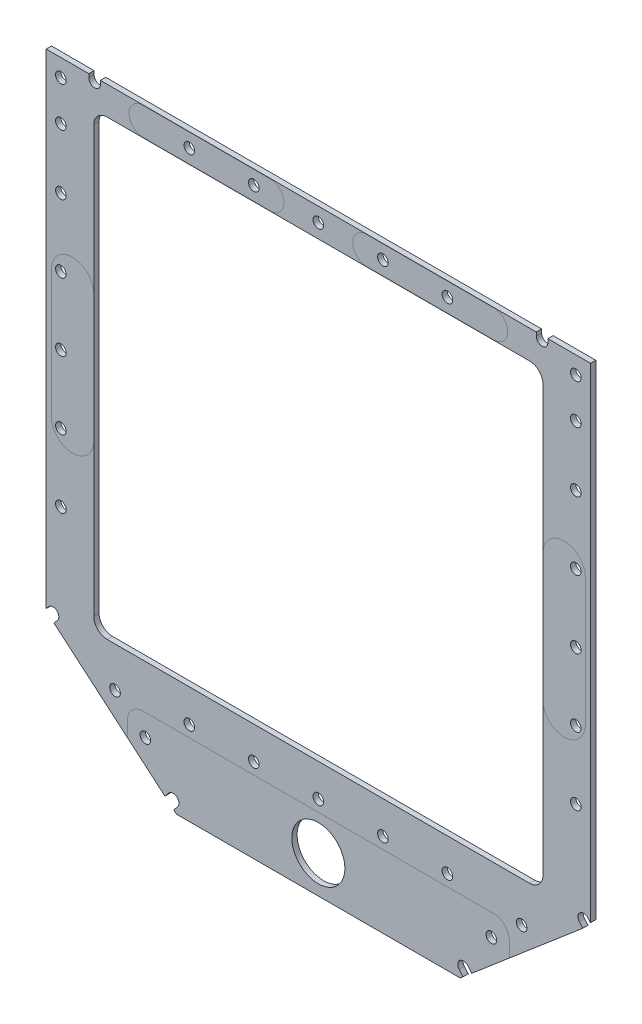
SolidWorks part; units mm, degrees
ref_plane "Front" through (0, 0, 0) normal (0, 0, 1) x (1, 0, 0)
ref_plane "Top" through (0, 0, 0) normal (0, 1, 0) x (1, 0, 0)
ref_plane "Right" through (0, 0, 0) normal (1, 0, 0) x (0, 0, -1)
sketch "Sketch1" plane through (0, 0, -8.9364) normal (0, 0, 1) x (1, 0, 0)
  line L0 (-62.992, 192.0875) -> (62.992, 192.0875)
  line L1 (-66.675, 183.0705) -> (66.675, 183.0705) construction
  line L2 (-66.675, 48.768) -> (66.675, 48.768) construction
  line L3 (-66.675, 48.768) -> (66.675, 48.768) construction
  line L4 (66.675, 183.0705) -> (66.675, 48.768) construction
  line L5 (62.992, 192.0875) -> (62.992, 187.071)
  line L6 (62.992, 187.071) -> (70.866, 187.071)
  line L7 (70.866, 187.071) -> (70.866, 192.0875)
  line L8 (70.866, 192.0875) -> (81.407, 192.0875)
  line L9 (81.407, 192.0875) -> (81.407, 50.8)
  line L10 (81.407, 50.8) -> (75.438, 50.8)
  line L11 (75.438, 50.8) -> (75.438, 41.4295)
  line L12 (75.438, 41.4295) -> (47.5845, 17.7206)
  line L13 (47.5845, 17.7206) -> (35.3184, 32.131)
  line L14 (35.3184, 32.131) -> (-35.3184, 32.131)
  line L15 (-67.183, 183.5785) -> (67.183, 183.5785)
  line L16 (67.183, 183.5785) -> (67.183, 48.26)
  line L17 (-67.183, 48.26) -> (67.183, 48.26)
  line L18 (-67.183, 48.26) -> (67.183, 48.26) construction
  line L19 (81.915, 162.3536) -> (81.915, 172.6784) construction
  line L20 (0, 194.183) -> (0, 11.7602) construction
  line L22 (46.5936, 16.2101) -> (78.9144, 43.7216) construction
  line L23 (-67.183, 183.5785) -> (67.183, 183.5785) construction
  line L24 (-66.675, 183.0705) -> (66.675, 183.0705) construction
  line L25 (-66.675, 183.0705) -> (-66.675, 48.768) construction
  line L26 (-67.183, 183.5785) -> (-67.183, 48.26) construction
  line L27 (33.1388, 192.5955) -> (24.7732, 192.5955) construction
  line L28 (81.915, 192.5955) -> (69.6786, 192.5955) construction
  line L29 (-43.2308, 13.3477) -> (43.2308, 13.3477) construction
  line L34 (-66.675, 183.0705) -> (-66.675, 48.768) construction
  line L35 (-67.183, 183.5785) -> (-67.183, 48.26)
  line L36 (-47.5845, 17.7206) -> (-35.3184, 32.131)
  line L37 (-75.438, 41.4295) -> (-47.5845, 17.7206)
  line L38 (-75.438, 50.8) -> (-75.438, 41.4295)
  line L39 (-81.407, 50.8) -> (-75.438, 50.8)
  line L40 (-81.407, 192.0875) -> (-81.407, 50.8)
  line L41 (-70.866, 192.0875) -> (-81.407, 192.0875)
  line L42 (-70.866, 187.071) -> (-70.866, 192.0875)
  line L43 (-62.992, 187.071) -> (-70.866, 187.071)
  line L44 (-62.992, 192.0875) -> (-62.992, 187.071)
  circle A0 centre (79.375, 46.863) radius 3.937 construction
  circle A3 centre (43.434, 16.5227) radius 3.937 construction
  circle A5 centre (66.929, 191.008) radius 3.937 construction
  circle A7 centre (-66.929, 191.008) radius 3.937 construction
  circle A8 centre (-43.434, 16.5227) radius 3.937 construction
  circle A9 centre (-79.375, 46.863) radius 3.937 construction
  point P29 (0, 183.5785)
  point P30 (0, 183.0705)
  point P66 (0, 48.768)
  point P67 (0, 48.26)
  point P69 (0, 32.131)
  point P78 (0, 192.0875)
  dimension "D6" = 18.7833
  dimension "D1" = 0.508
  dimension "D2" = 0.508
  dimension "D3" = 0.508
  dimension "D4" = 0.508
  dimension "D5" = 0.508
extrude "Boss-Extrude1" add sketch "Sketch1" along normal blind 1.5875
sketch "Sketch2" plane through (0, 0, -7.3489) normal (0, 0, 1) x (1, 0, 0)
  line L2 (67.1735, 135.763) -> (67.1735, 97.663)
  line L3 (79.8735, 97.663) -> (79.8735, 135.763)
  line L4 (67.1735, 135.763) -> (67.1735, 97.663)
  line L5 (79.8735, 97.663) -> (79.8735, 135.763)
  line L6 (-67.1735, 97.663) -> (-67.1735, 135.763)
  line L7 (-79.8735, 135.763) -> (-79.8735, 97.663)
  line L8 (-67.1735, 97.663) -> (-67.1735, 135.763)
  line L9 (-79.8735, 135.763) -> (-79.8735, 97.663)
  line L14 (-57.15, 23.111) -> (-48.4599, 15.7139)
  line L15 (-57.15, 30.2895) -> (-57.15, 23.111)
  line L16 (52.3875, 35.052) -> (-52.3875, 35.052)
  line L17 (57.15, 23.111) -> (57.15, 30.2895)
  line L18 (48.4599, 15.7139) -> (57.15, 23.111)
  line L19 (-33.8657, 12.3825) -> (33.8657, 12.3825)
  line L20 (-57.15, 23.111) -> (-48.4599, 15.7139)
  line L21 (-57.15, 30.2895) -> (-57.15, 23.111)
  line L22 (52.3875, 35.052) -> (-52.3875, 35.052)
  line L23 (57.15, 23.111) -> (57.15, 30.2895)
  line L24 (48.4599, 15.7139) -> (57.15, 23.111)
  line L25 (-33.8657, 12.3825) -> (33.8657, 12.3825)
  line L52 (14.4145, 183.7055) -> (52.5145, 183.7055)
  line L53 (52.5145, 191.9605) -> (14.4145, 191.9605)
  line L54 (14.4145, 183.7055) -> (52.5145, 183.7055)
  line L55 (52.5145, 191.9605) -> (14.4145, 191.9605)
  line L56 (-14.4145, 191.9605) -> (-52.5145, 191.9605)
  line L57 (-52.5145, 183.7055) -> (-14.4145, 183.7055)
  line L58 (-14.4145, 191.9605) -> (-52.5145, 191.9605)
  line L59 (-52.5145, 183.7055) -> (-14.4145, 183.7055)
  arc A4 (73.5235, 91.313) -> (79.8735, 97.663) centre (73.5235, 97.663) ccw
  arc A5 (67.1735, 97.663) -> (73.5235, 91.313) centre (73.5235, 97.663) ccw
  arc A6 (73.5235, 142.113) -> (67.1735, 135.763) centre (73.5235, 135.763) ccw
  arc A7 (79.8735, 135.763) -> (73.5235, 142.113) centre (73.5235, 135.763) ccw
  arc A8 (73.5235, 91.313) -> (79.8735, 97.663) centre (73.5235, 97.663) ccw
  arc A9 (67.1735, 97.663) -> (73.5235, 91.313) centre (73.5235, 97.663) ccw
  arc A10 (73.5235, 142.113) -> (67.1735, 135.763) centre (73.5235, 135.763) ccw
  arc A11 (79.8735, 135.763) -> (73.5235, 142.113) centre (73.5235, 135.763) ccw
  arc A12 (-73.5235, 91.313) -> (-67.1735, 97.663) centre (-73.5235, 97.663) ccw
  arc A13 (-79.8735, 97.663) -> (-73.5235, 91.313) centre (-73.5235, 97.663) ccw
  arc A14 (-73.5235, 142.113) -> (-79.8735, 135.763) centre (-73.5235, 135.763) ccw
  arc A15 (-67.1735, 135.763) -> (-73.5235, 142.113) centre (-73.5235, 135.763) ccw
  arc A16 (-73.5235, 91.313) -> (-67.1735, 97.663) centre (-73.5235, 97.663) ccw
  arc A17 (-79.8735, 97.663) -> (-73.5235, 91.313) centre (-73.5235, 97.663) ccw
  arc A18 (-73.5235, 142.113) -> (-79.8735, 135.763) centre (-73.5235, 135.763) ccw
  arc A19 (-67.1735, 135.763) -> (-73.5235, 142.113) centre (-73.5235, 135.763) ccw
  arc A24 (-52.3875, 35.052) -> (-57.15, 30.2895) centre (-52.3875, 30.2895) ccw
  arc A25 (57.15, 30.2895) -> (52.3875, 35.052) centre (52.3875, 30.2895) ccw
  arc A26 (48.2498, 16.8359) -> (48.4599, 15.7139) centre (53.0023, 17.145) ccw
  arc A27 (48.2498, 16.8359) -> (38.6182, 16.8359) centre (43.434, 16.5227) ccw
  arc A28 (33.8657, 12.3825) -> (38.6182, 16.8359) centre (33.8657, 17.145) ccw
  arc A29 (-38.6182, 16.8359) -> (-33.8657, 12.3825) centre (-33.8657, 17.145) ccw
  arc A30 (-38.6182, 16.8359) -> (-48.2498, 16.8359) centre (-43.434, 16.5227) ccw
  arc A31 (-48.4599, 15.7139) -> (-48.2498, 16.8359) centre (-53.0023, 17.145) ccw
  arc A32 (-52.3875, 35.052) -> (-57.15, 30.2895) centre (-52.3875, 30.2895) ccw
  arc A33 (57.15, 30.2895) -> (52.3875, 35.052) centre (52.3875, 30.2895) ccw
  arc A34 (48.2498, 16.8359) -> (48.4599, 15.7139) centre (53.0023, 17.145) ccw
  arc A35 (48.2498, 16.8359) -> (38.6182, 16.8359) centre (43.434, 16.5227) ccw
  arc A36 (33.8657, 12.3825) -> (38.6182, 16.8359) centre (33.8657, 17.145) ccw
  arc A37 (-38.6182, 16.8359) -> (-33.8657, 12.3825) centre (-33.8657, 17.145) ccw
  arc A38 (-38.6182, 16.8359) -> (-48.2498, 16.8359) centre (-43.434, 16.5227) ccw
  arc A39 (-48.4599, 15.7139) -> (-48.2498, 16.8359) centre (-53.0023, 17.145) ccw
  arc A82 (14.4145, 191.9605) -> (14.4145, 183.7055) centre (14.4145, 187.833) ccw
  arc A83 (52.5145, 183.7055) -> (52.5145, 191.9605) centre (52.5145, 187.833) ccw
  arc A84 (14.4145, 191.9605) -> (14.4145, 183.7055) centre (14.4145, 187.833) ccw
  arc A85 (52.5145, 183.7055) -> (52.5145, 191.9605) centre (52.5145, 187.833) ccw
  arc A86 (-14.4145, 183.7055) -> (-14.4145, 191.9605) centre (-14.4145, 187.833) ccw
  arc A87 (-52.5145, 191.9605) -> (-52.5145, 183.7055) centre (-52.5145, 187.833) ccw
  arc A88 (-14.4145, 183.7055) -> (-14.4145, 191.9605) centre (-14.4145, 187.833) ccw
  arc A89 (-52.5145, 191.9605) -> (-52.5145, 183.7055) centre (-52.5145, 187.833) ccw
  dimension "D1" = 0
  dimension "D2" = 0
  dimension "D3" = 0
  dimension "D4" = 0
  dimension "D5" = 0
split line "Split Line1"
sketch "Sketch3" plane through (0, 0, -8.9364) normal (0, 0, -1) x (-1, 0, 0)
  line L0 (81.407, 50.8) -> (81.407, 46.5104)
  line L1 (75.438, 41.4295) -> (81.407, 46.5104)
  line L3 (75.438, 41.4295) -> (75.438, 50.8)
  line L4 (75.438, 50.8) -> (81.407, 50.8)
  line L5 (47.5845, 17.7206) -> (42.4471, 13.3477)
  line L6 (70.866, 187.071) -> (62.992, 187.071)
  line L7 (70.866, 187.071) -> (70.866, 192.0875)
  line L8 (70.866, 192.0875) -> (62.992, 192.0875)
  line L9 (62.992, 187.071) -> (62.992, 192.0875)
  line L10 (0, 32.131) -> (0, 13.3477)
  line L12 (-42.4471, 13.3477) -> (42.4471, 13.3477)
  line L14 (-35.3184, 32.131) -> (35.3184, 32.131)
  line L15 (35.3184, 32.131) -> (47.5845, 17.7206)
  line L16 (-35.3184, 32.131) -> (-47.5845, 17.7206)
  line L17 (-62.992, 187.071) -> (-62.992, 192.0875)
  line L18 (-70.866, 192.0875) -> (-62.992, 192.0875)
  line L19 (-70.866, 187.071) -> (-70.866, 192.0875)
  line L20 (-70.866, 187.071) -> (-62.992, 187.071)
  line L21 (-47.5845, 17.7206) -> (-42.4471, 13.3477)
  line L22 (-75.438, 50.8) -> (-81.407, 50.8)
  line L23 (-75.438, 41.4295) -> (-75.438, 50.8)
  line L24 (-75.438, 41.4295) -> (-81.407, 46.5104)
  line L25 (-81.407, 50.8) -> (-81.407, 46.5104)
extrude "Boss-Extrude4" add sketch "Sketch3" against normal through all contours L10 L12 L5 | L21 L12 L10 | L1 L0 | L25 L24 | L18 | L8 region at (-78.0525, 47.2275, -8.9364) region at (-21.2873, 22.341, -8.9364) region at (21.2873, 22.341, -8.9364) region at (-66.929, 189.5793, -8.9364) region at (66.929, 189.5793, -8.9364) region at (78.0525, 47.2275, -8.9364)
sketch "Sketch5" plane through (0, 0, -8.9364) normal (0, 0, 1) x (1, 0, 0)
  line L0 (81.407, 46.5104) -> (81.407, 192.0875) construction
  line L1 (81.407, 46.5104) -> (84.407, 49.064)
  line L2 (81.407, 46.5104) -> (81.407, 195.0875)
  line L3 (81.407, 195.0875) -> (84.407, 195.0875)
  line L4 (84.407, 49.064) -> (84.407, 195.0875)
  line L5 (42.4471, 13.3477) -> (81.407, 46.5104) construction
  line L6 (81.407, 192.0875) -> (-81.407, 192.0875) construction
  line L7 (-81.407, 192.0875) -> (-81.407, 195.0875)
  line L8 (-81.407, 192.0875) -> (81.407, 192.0875)
  line L9 (0, 192.0875) -> (0, 195.0875)
  line L10 (-81.407, 195.0875) -> (81.407, 195.0875)
  line L11 (81.407, 192.0875) -> (81.407, 195.0875)
  line L12 (-84.407, 49.064) -> (-84.407, 195.0875)
  line L13 (-81.407, 195.0875) -> (-84.407, 195.0875)
  line L14 (-81.407, 46.5104) -> (-81.407, 195.0875)
  line L15 (-81.407, 46.5104) -> (-84.407, 49.064)
  dimension "D2" = 3
  dimension "D1" = 3
extrude "Boss-Extrude5" add sketch "Sketch5" against normal through all rebuild error yes
sketch "Sketch4" plane through (0, 0, -8.9364) normal (0, 0, -1) x (-1, 0, 0)
  line L0 (43.434, 16.5227) -> (45.739, 13.8148) construction
  line L1 (44.7492, 17.6422) -> (47.0542, 14.9343)
  line L2 (42.1188, 15.4032) -> (44.4237, 12.6952)
  line L3 (48.0029, 18.0768) -> (42.4471, 13.3477) construction
  line L4 (79.375, 46.863) -> (81.4305, 44.4481) construction
  line L5 (80.6902, 47.9825) -> (82.7458, 45.5677)
  line L6 (78.0598, 45.7435) -> (80.1153, 43.3286)
  line L7 (81.407, 46.5104) -> (57.15, 25.8628) construction
  line L8 (66.929, 191.008) -> (66.929, 199.167) construction
  line L9 (65.2018, 191.008) -> (65.2018, 199.167)
  line L10 (68.6562, 191.008) -> (68.6562, 199.167)
  line L12 (-84.407, 195.0875) -> (84.407, 195.0875) construction
  line L13 (-67.183, 183.5785) -> (67.183, 183.5785) construction
  line L14 (0, 13.3477) -> (0, 195.0875) construction
  line L15 (-42.4471, 13.3477) -> (42.4471, 13.3477) construction
  line L16 (-43.434, 16.5227) -> (-45.739, 13.8148) construction
  line L17 (-44.7492, 17.6422) -> (-47.0542, 14.9343)
  line L18 (-42.1188, 15.4032) -> (-44.4237, 12.6952)
  line L19 (-79.375, 46.863) -> (-81.4305, 44.4481) construction
  line L20 (-80.6902, 47.9825) -> (-82.7458, 45.5677)
  line L21 (-78.0598, 45.7435) -> (-80.1153, 43.3286)
  line L22 (-66.929, 191.008) -> (-66.929, 199.167) construction
  line L23 (-65.2018, 191.008) -> (-65.2018, 199.167)
  line L24 (-68.6562, 191.008) -> (-68.6562, 199.167)
  arc A0 (44.7492, 17.6422) -> (42.1188, 15.4032) centre (43.434, 16.5227) ccw
  arc A1 (44.4237, 12.6952) -> (47.0542, 14.9343) centre (45.739, 13.8148) ccw
  circle A2 centre (43.434, 16.5227) radius 1.7272 construction
  arc A3 (80.6902, 47.9825) -> (78.0598, 45.7435) centre (79.375, 46.863) ccw
  arc A4 (80.1153, 43.3286) -> (82.7458, 45.5677) centre (81.4305, 44.4481) ccw
  circle A5 centre (79.375, 46.863) radius 1.7272 construction
  arc A6 (65.2018, 191.008) -> (68.6562, 191.008) centre (66.929, 191.008) ccw
  arc A7 (68.6562, 199.167) -> (65.2018, 199.167) centre (66.929, 199.167) ccw
  circle A8 centre (66.929, 191.008) radius 1.7272 construction
  arc A9 (-44.7492, 17.6422) -> (-42.1188, 15.4032) centre (-43.434, 16.5227) cw
  arc A10 (-44.4237, 12.6952) -> (-47.0542, 14.9343) centre (-45.739, 13.8148) cw
  arc A11 (-80.6902, 47.9825) -> (-78.0598, 45.7435) centre (-79.375, 46.863) cw
  arc A12 (-80.1153, 43.3286) -> (-82.7458, 45.5677) centre (-81.4305, 44.4481) cw
  arc A13 (-65.2018, 191.008) -> (-68.6562, 191.008) centre (-66.929, 191.008) cw
  arc A14 (-68.6562, 199.167) -> (-65.2018, 199.167) centre (-66.929, 199.167) cw
  point P2 (44.5865, 15.1687)
  point P12 (80.4028, 45.6556)
  point P27 (66.929, 195.0875)
  point P44 (-44.5865, 15.1687)
  point P51 (-80.4028, 45.6556)
  point P58 (-66.929, 195.0875)
extrude "Cut-Extrude1" cut sketch "Sketch4" against normal through all
sketch "Sketch6" plane through (0, 0, -8.9364) normal (0, 0, -1) x (-1, 0, 0)
  circle A0 centre (51.756, 28.5263) radius 1.5875
  circle A1 centre (60.8225, 36.2437) radius 1.5875
  circle A2 centre (38.608, 38.481) radius 1.5875
  circle A3 centre (19.304, 38.481) radius 1.5875
  circle A4 centre (0, 38.481) radius 1.5875
  circle A5 centre (-19.304, 38.481) radius 1.5875
  circle A6 centre (-38.608, 38.481) radius 1.5875
  circle A7 centre (-51.756, 28.5263) radius 1.5875
  circle A8 centre (-60.8225, 36.2437) radius 1.5875
  circle A9 centre (-77.0255, 75.692) radius 1.5875
  circle A10 centre (-77.0255, 96.012) radius 1.5875
  circle A11 centre (-77.0255, 116.332) radius 1.5875
  circle A12 centre (-77.0255, 136.652) radius 1.5875
  circle A13 centre (-77.0255, 156.972) radius 1.5875
  circle A14 centre (-77.0255, 174.9584) radius 1.5875
  circle A15 centre (-77.0255, 186.8646) radius 1.5875
  circle A16 centre (-38.608, 187.833) radius 1.5875
  circle A17 centre (-19.304, 187.833) radius 1.5875
  circle A18 centre (0, 187.833) radius 1.5875
  circle A19 centre (19.304, 187.833) radius 1.5875
  circle A20 centre (38.608, 187.833) radius 1.5875
  circle A21 centre (77.0255, 186.8646) radius 1.5875
  circle A22 centre (77.0255, 174.9584) radius 1.5875
  circle A23 centre (77.0255, 156.972) radius 1.5875
  circle A24 centre (77.0255, 136.652) radius 1.5875
  circle A25 centre (77.0255, 116.332) radius 1.5875
  circle A26 centre (77.0255, 96.012) radius 1.5875
  circle A27 centre (77.0255, 75.692) radius 1.5875
  point P0 (77.0255, 156.972)
  point P2 (77.0255, 174.9584)
  point P4 (77.0255, 186.8646)
  point P6 (38.608, 187.833)
  point P8 (19.304, 187.833)
  point P10 (-38.608, 187.833)
  point P12 (-19.304, 187.833)
  point P14 (0, 187.833)
  point P16 (77.0255, 75.692)
  point P18 (77.0255, 96.012)
  point P20 (77.0255, 116.332)
  point P22 (77.0255, 136.652)
  point P24 (-60.8225, 36.2437)
  point P26 (-51.756, 28.5263)
  point P28 (-38.608, 38.481)
  point P30 (-19.304, 38.481)
  point P32 (0, 38.481)
  point P34 (19.304, 38.481)
  point P36 (38.608, 38.481)
  point P38 (51.756, 28.5263)
  point P40 (60.8225, 36.2437)
  point P42 (-77.0255, 186.8646)
  point P44 (-77.0255, 174.9584)
  point P46 (-77.0255, 156.972)
  point P48 (-77.0255, 136.652)
  point P50 (-77.0255, 116.332)
  point P52 (-77.0255, 96.012)
  point P54 (-77.0255, 75.692)
  dimension "D1" = 3.175
extrude "Cut-Extrude2" cut sketch "Sketch6" against normal through all
fillet "Fillet1" radius 4 4 edges at (-67.183, 183.5785, -8.1426) (67.183, 183.5785, -8.1426) (67.183, 48.26, -8.1426) (-67.183, 48.26, -8.1426)
sketch "Sketch7" plane through (0, 0, -8.9364) normal (0, 0, -1) x (-1, 0, 0)
  line L0 (63.574, 184.2406) -> (64.1599, 185.7918) construction
  line L1 (64.1599, 185.7918) -> (62.988, 185.7918) construction
  line L2 (62.988, 185.7918) -> (63.574, 184.2406) construction
  line L3 (69.4055, 183.8325) -> (69.4055, 186.3725) construction
  line L4 (68.6435, 187.1345) -> (57.4675, 187.1345) construction
  line L5 (56.7055, 186.3725) -> (56.7055, 183.8325) construction
  line L6 (57.4675, 183.0705) -> (68.6435, 183.0705) construction
  line L7 (63.574, 184.2406) -> (64.1599, 185.7918)
  line L8 (64.1599, 185.7918) -> (62.988, 185.7918)
  line L9 (62.988, 185.7918) -> (63.574, 184.2406)
  line L10 (69.4055, 183.8325) -> (69.4055, 186.3725)
  line L11 (68.6435, 187.1345) -> (57.4675, 187.1345)
  line L12 (56.7055, 186.3725) -> (56.7055, 183.8325)
  line L13 (57.4675, 183.0705) -> (68.6435, 183.0705)
  line L17 (-61.5637, 183.8089) -> (-61.5633, 183.8097) construction
  line L18 (61.4031, 186.5254) -> (61.4031, 183.6686)
  line L19 (61.7659, 183.6839) -> (61.7652, 186.5251)
  line L20 (61.4031, 186.5254) -> (61.4031, 183.6686)
  line L21 (58.9604, 185.8548) -> (60.4424, 183.5881)
  line L22 (58.9611, 183.712) -> (58.9604, 185.8548)
  line L23 (58.553, 186.5211) -> (58.5523, 183.6932)
  line L24 (60.4375, 184.3387) -> (58.9604, 186.6204)
  line L25 (60.4375, 186.516) -> (60.4375, 184.3387)
  line L26 (60.8463, 183.7033) -> (60.8456, 186.4853)
  line L27 (58.9604, 185.8548) -> (60.4424, 183.5881)
  line L28 (58.9611, 183.712) -> (58.9604, 185.8548)
  line L29 (58.553, 186.5211) -> (58.5523, 183.6932)
  line L30 (60.4375, 184.3387) -> (58.9604, 186.6204)
  line L31 (60.4375, 186.516) -> (60.4375, 184.3387)
  line L32 (60.8463, 183.7033) -> (60.8456, 186.4853)
  line L33 (61.7659, 183.6839) -> (61.7652, 186.5251)
  line L34 (-56.7055, 183.8325) -> (-56.7055, 186.3725) construction
  line L35 (-57.4675, 187.1345) -> (-68.6435, 187.1345) construction
  line L36 (-69.4055, 186.3725) -> (-69.4055, 183.8325) construction
  line L37 (65.8574, 185.2803) -> (65.8574, 185.7969)
  line L38 (62.8241, 186.1999) -> (62.6801, 186.5871)
  line L39 (64.3139, 186.1999) -> (62.8241, 186.1999)
  line L40 (64.473, 186.6116) -> (64.3139, 186.1999)
  line L41 (63.7876, 183.6042) -> (64.8502, 186.4155)
  line L42 (62.2781, 186.4499) -> (63.3505, 183.6494)
  line L43 (62.8241, 186.1999) -> (62.6801, 186.5871)
  line L44 (64.3139, 186.1999) -> (62.8241, 186.1999)
  line L45 (64.473, 186.6116) -> (64.3139, 186.1999)
  line L46 (63.7876, 183.6042) -> (64.8502, 186.4155)
  line L47 (62.2781, 186.4499) -> (63.3505, 183.6494)
  line L48 (66.2181, 185.281) -> (65.8574, 185.2803)
  line L49 (65.7166, 184.8722) -> (66.1979, 184.8722)
  line L50 (65.4501, 185.9276) -> (65.4494, 185.1492)
  line L51 (65.8574, 185.2803) -> (65.8574, 185.7969)
  line L52 (66.2181, 185.281) -> (65.8574, 185.2803)
  line L53 (65.7166, 184.8722) -> (66.1979, 184.8722)
  line L54 (65.4501, 185.9276) -> (65.4494, 185.1492)
  line L55 (-68.6435, 183.0705) -> (-57.4675, 183.0705) construction
  line L56 (-61.5637, 183.8089) -> (-61.5633, 183.8097)
  line L57 (-56.7055, 183.8325) -> (-56.7055, 186.3725)
  line L58 (-57.4675, 187.1345) -> (-68.6435, 187.1345)
  line L59 (-69.4055, 186.3725) -> (-69.4055, 183.8325)
  line L60 (-68.6435, 183.0705) -> (-57.4675, 183.0705)
  line L62 (-58.946, 183.4476) -> (-58.9464, 183.4469)
  line L63 (-58.946, 183.4476) -> (-58.9464, 183.4469)
  line L66 (-61.5633, 183.4016) -> (-61.5637, 183.4009)
  line L67 (-61.5633, 183.4016) -> (-61.5637, 183.4009)
  line L69 (-8.4611, 29.7565) -> (-7.6566, 29.7565) construction
  line L70 (-67.3978, 183.8549) -> (-68.0632, 183.8549)
  line L71 (-67.3978, 186.5002) -> (-67.3978, 183.8549)
  line L72 (-66.9897, 183.8549) -> (-66.9897, 186.4751)
  line L73 (-66.3187, 183.8556) -> (-66.9897, 183.8549)
  line L74 (-68.0774, 183.4476) -> (-66.3441, 183.4469)
  line L75 (-67.3978, 183.8549) -> (-68.0632, 183.8549)
  line L76 (-67.3978, 186.5002) -> (-67.3978, 183.8549)
  line L77 (-66.9897, 183.8549) -> (-66.9897, 186.4751)
  line L78 (-66.3187, 183.8556) -> (-66.9897, 183.8549)
  line L79 (-68.0774, 183.4476) -> (-66.3441, 183.4469)
  line L80 (-7.6566, 29.7565) -> (-7.6566, 30.9577) construction
  line L81 (-65.1505, 185.8548) -> (-63.6685, 183.5881)
  line L82 (-65.1498, 183.712) -> (-65.1505, 185.8548)
  line L83 (-65.5578, 186.5211) -> (-65.5586, 183.6932)
  line L84 (-63.6734, 184.3387) -> (-65.1505, 186.6204)
  line L85 (-63.6734, 186.516) -> (-63.6734, 184.3387)
  line L86 (-63.2646, 183.7033) -> (-63.2653, 186.4853)
  line L87 (-65.1505, 185.8548) -> (-63.6685, 183.5881)
  line L88 (-65.1498, 183.712) -> (-65.1505, 185.8548)
  line L89 (-65.5578, 186.5211) -> (-65.5586, 183.6932)
  line L90 (-63.6734, 184.3387) -> (-65.1505, 186.6204)
  line L91 (-63.6734, 186.516) -> (-63.6734, 184.3387)
  line L92 (-63.2646, 183.7033) -> (-63.2653, 186.4853)
  line L93 (-7.6566, 30.9577) -> (-8.4157, 30.9577) construction
  line L94 (-8.5703, 28.469) -> (-7.6913, 28.469) construction
  line L95 (-37.2245, 25.8054) -> (-37.2245, 28.3454)
  line L96 (-37.9865, 29.1074) -> (-46.1145, 29.1074)
  line L97 (-46.8765, 28.3454) -> (-46.8765, 25.8054)
  line L98 (-46.1145, 25.0434) -> (-37.9865, 25.0434)
  line L99 (-44.7633, 26.9798) -> (-43.9134, 25.5695)
  line L100 (-45.6133, 25.5513) -> (-44.7633, 26.9798)
  line L101 (-46.0012, 28.499) -> (-46.0019, 25.6357)
  line L102 (-45.5939, 26.4037) -> (-45.5939, 28.4745)
  line L103 (-44.9868, 27.412) -> (-45.5939, 26.4037)
  line L104 (-43.9328, 26.4037) -> (-44.5495, 27.4367)
  line L105 (-43.9328, 28.4653) -> (-43.9328, 26.4037)
  line L106 (-43.524, 25.6892) -> (-43.5248, 28.4547)
  line L107 (-44.7633, 26.9798) -> (-43.9134, 25.5695)
  line L108 (-45.6133, 25.5513) -> (-44.7633, 26.9798)
  line L109 (-46.0012, 28.499) -> (-46.0019, 25.6357)
  line L110 (-45.5939, 26.4037) -> (-45.5939, 28.4745)
  line L111 (-44.9868, 27.412) -> (-45.5939, 26.4037)
  line L112 (-43.9328, 26.4037) -> (-44.5495, 27.4367)
  line L113 (-43.9328, 28.4653) -> (-43.9328, 26.4037)
  line L114 (-43.524, 25.6892) -> (-43.5248, 28.4547)
  line L115 (-42.5585, 25.5613) -> (-41.8412, 26.9144)
  line L116 (-39.2259, 25.4198) -> (-38.9059, 25.4354)
  line L117 (-39.2551, 25.4205) -> (-39.2259, 25.4198)
  line L118 (-39.1812, 25.8256) -> (-39.2061, 25.8256)
  line L119 (-38.9325, 25.8307) -> (-39.1812, 25.8256)
  line L120 (-39.4275, 26.8502) -> (-38.891, 26.7399)
  line L121 (-38.9059, 28.7246) -> (-39.2289, 28.7246)
  line L122 (-38.3735, 27.8144) -> (-38.3742, 27.7743)
  line L123 (-39.2069, 28.3259) -> (-38.9108, 28.3256)
  line L124 (-38.7917, 27.1441) -> (-39.3259, 27.2579)
  line L125 (-39.2259, 25.4198) -> (-38.9059, 25.4354)
  line L126 (-39.2551, 25.4205) -> (-39.2259, 25.4198)
  line L127 (-39.1812, 25.8256) -> (-39.2061, 25.8256)
  line L128 (-38.9325, 25.8307) -> (-39.1812, 25.8256)
  line L129 (-39.4275, 26.8502) -> (-38.891, 26.7399)
  line L130 (-38.9059, 28.7246) -> (-39.2289, 28.7246)
  line L131 (-38.3735, 27.8144) -> (-38.3742, 27.7743)
  line L132 (-39.2069, 28.3259) -> (-38.9108, 28.3256)
  line L133 (-38.7917, 27.1441) -> (-39.3259, 27.2579)
  line L134 (-41.8412, 26.9144) -> (-41.133, 25.5814)
  line L135 (-40.7451, 25.7424) -> (-40.7556, 25.7618)
  line L136 (-40.7556, 25.7618) -> (-41.6396, 27.4156)
  line L137 (-41.6396, 27.4156) -> (-41.6396, 28.4931)
  line L138 (-42.0476, 28.4782) -> (-42.0476, 27.4156)
  line L139 (-42.0476, 27.4156) -> (-42.9068, 25.7818)
  line L140 (-42.9068, 25.7818) -> (-42.9167, 25.7668)
  line L141 (-42.5585, 25.5613) -> (-41.8412, 26.9144)
  line L142 (-41.8412, 26.9144) -> (-41.133, 25.5814)
  line L143 (-40.7451, 25.7424) -> (-40.7556, 25.7618)
  line L144 (-40.7556, 25.7618) -> (-41.6396, 27.4156)
  line L145 (-41.6396, 27.4156) -> (-41.6396, 28.4931)
  line L146 (-42.0476, 28.4782) -> (-42.0476, 27.4156)
  line L147 (-42.0476, 27.4156) -> (-42.9068, 25.7818)
  line L148 (-42.9068, 25.7818) -> (-42.9167, 25.7668)
  line L149 (-37.2245, 25.8054) -> (-37.2245, 28.3454)
  line L150 (-37.9865, 29.1074) -> (-46.1145, 29.1074)
  line L151 (-46.8765, 28.3454) -> (-46.8765, 25.8054)
  line L152 (-46.1145, 25.0434) -> (-37.9865, 25.0434)
  line L153 (-6.35, 28.4466) -> (-6.35, 30.9866)
  line L154 (-7.112, 31.7486) -> (-15.24, 31.7486)
  line L155 (-16.002, 30.9866) -> (-16.002, 28.4466)
  line L156 (-15.24, 27.6846) -> (-7.112, 27.6846)
  line L157 (-6.35, 28.4466) -> (-6.35, 30.9866)
  line L158 (-7.112, 31.7486) -> (-15.24, 31.7486)
  line L159 (-16.002, 30.9866) -> (-16.002, 28.4466)
  line L160 (-15.24, 27.6846) -> (-7.112, 27.6846)
  line L161 (-7.6913, 28.469) -> (-7.6913, 29.3484) construction
  line L162 (-7.6913, 29.3484) -> (-8.5795, 29.3484) construction
  line L163 (-11.1624, 28.469) -> (-10.4145, 28.469) construction
  line L164 (-10.4145, 28.469) -> (-10.4145, 29.5783) construction
  line L165 (-10.4145, 29.5783) -> (-11.1264, 29.5783) construction
  line L166 (-8.4611, 29.7565) -> (-7.6566, 29.7565)
  line L167 (-7.6566, 29.7565) -> (-7.6566, 30.9577)
  line L168 (-7.6566, 30.9577) -> (-8.4157, 30.9577)
  line L169 (-8.5703, 28.469) -> (-7.6913, 28.469)
  line L170 (-7.6913, 28.469) -> (-7.6913, 29.3484)
  line L171 (-7.6913, 29.3484) -> (-8.5795, 29.3484)
  line L172 (-11.1624, 28.469) -> (-10.4145, 28.469)
  line L173 (-10.4145, 28.469) -> (-10.4145, 29.5783)
  line L174 (-10.4145, 29.5783) -> (-11.1264, 29.5783)
  line L177 (73.2934, 39.1971) -> (73.2934, 41.7371) construction
  line L178 (-8.6148, 28.0617) -> (-7.4977, 28.061)
  line L179 (-7.244, 28.3124) -> (-7.2444, 31.1052)
  line L180 (-7.5026, 31.3658) -> (-8.4213, 31.3658)
  line L181 (-8.6148, 28.0617) -> (-7.4977, 28.061)
  line L182 (-7.244, 28.3124) -> (-7.2444, 31.1052)
  line L183 (-7.5026, 31.3658) -> (-8.4213, 31.3658)
  line L184 (72.5314, 42.4991) -> (64.4034, 42.4991) construction
  line L185 (63.6414, 41.7371) -> (63.6414, 39.1971) construction
  line L186 (64.4034, 38.4351) -> (72.5314, 38.4351) construction
  line L187 (46.8765, 25.8054) -> (46.8765, 28.3454) construction
  line L188 (-12.1028, 30.9951) -> (-11.3595, 29.9718)
  line L189 (-10.8541, 29.9864) -> (-11.7779, 31.2353)
  line L190 (-10.4145, 29.9864) -> (-10.8541, 29.9864)
  line L191 (-10.4145, 31.0978) -> (-10.4145, 29.9864)
  line L192 (-10.0057, 28.3476) -> (-10.0064, 31.078)
  line L193 (-11.1465, 28.0617) -> (-10.3063, 28.061)
  line L194 (-12.1028, 30.9951) -> (-11.3595, 29.9718)
  line L195 (-10.8541, 29.9864) -> (-11.7779, 31.2353)
  line L196 (-10.4145, 29.9864) -> (-10.8541, 29.9864)
  line L197 (-10.4145, 31.0978) -> (-10.4145, 29.9864)
  line L198 (-10.0057, 28.3476) -> (-10.0064, 31.078)
  line L199 (-11.1465, 28.0617) -> (-10.3063, 28.061)
  line L200 (-14.0009, 28.469) -> (-14.6664, 28.469)
  line L201 (-14.0009, 31.1143) -> (-14.0009, 28.469)
  line L202 (-13.5928, 28.469) -> (-13.5928, 31.0892)
  line L203 (-12.9218, 28.4697) -> (-13.5928, 28.469)
  line L204 (-14.6806, 28.0617) -> (-12.9473, 28.061)
  line L205 (-14.0009, 28.469) -> (-14.6664, 28.469)
  line L206 (-14.0009, 31.1143) -> (-14.0009, 28.469)
  line L207 (-13.5928, 28.469) -> (-13.5928, 31.0892)
  line L208 (-12.9218, 28.4697) -> (-13.5928, 28.469)
  line L209 (-14.6806, 28.0617) -> (-12.9473, 28.061)
  line L210 (46.1145, 29.1074) -> (37.9865, 29.1074) construction
  line L211 (37.2245, 28.3454) -> (37.2245, 25.8054) construction
  line L212 (37.9865, 25.0434) -> (46.1145, 25.0434) construction
  line L213 (16.002, 28.4466) -> (16.002, 30.9866) construction
  line L214 (15.24, 31.7486) -> (7.112, 31.7486) construction
  line L215 (6.35, 30.9866) -> (6.35, 28.4466) construction
  line L216 (7.112, 27.6846) -> (15.24, 27.6846) construction
  line L217 (73.2934, 39.1971) -> (73.2934, 41.7371)
  line L218 (72.5314, 42.4991) -> (64.4034, 42.4991)
  line L219 (63.6414, 41.7371) -> (63.6414, 39.1971)
  line L220 (64.4034, 38.4351) -> (72.5314, 38.4351)
  line L221 (46.8765, 25.8054) -> (46.8765, 28.3454)
  line L222 (46.1145, 29.1074) -> (37.9865, 29.1074)
  line L223 (37.2245, 28.3454) -> (37.2245, 25.8054)
  line L224 (37.9865, 25.0434) -> (46.1145, 25.0434)
  line L225 (16.002, 28.4466) -> (16.002, 30.9866)
  line L226 (15.24, 31.7486) -> (7.112, 31.7486)
  line L227 (6.35, 30.9866) -> (6.35, 28.4466)
  line L228 (7.112, 27.6846) -> (15.24, 27.6846)
  line L231 (45.2473, 25.8279) -> (45.8008, 25.8279) construction
  line L232 (45.8008, 25.8279) -> (45.8008, 28.3166) construction
  line L233 (45.8008, 28.3166) -> (45.2526, 28.3166) construction
  line L234 (42.1322, 26.2135) -> (42.7181, 27.7648) construction
  line L235 (67.8438, 40.6449) -> (67.8438, 41.1615)
  line L236 (65.5505, 39.2195) -> (64.8851, 39.2195)
  line L237 (65.5505, 41.8648) -> (65.5505, 39.2195)
  line L238 (65.9586, 39.2195) -> (65.9586, 41.8397)
  line L239 (66.6296, 39.2202) -> (65.9586, 39.2195)
  line L240 (64.8709, 38.8122) -> (66.6042, 38.8114)
  line L241 (65.5505, 39.2195) -> (64.8851, 39.2195)
  line L242 (65.5505, 41.8648) -> (65.5505, 39.2195)
  line L243 (65.9586, 39.2195) -> (65.9586, 41.8397)
  line L244 (66.6296, 39.2202) -> (65.9586, 39.2195)
  line L245 (64.8709, 38.8122) -> (66.6042, 38.8114)
  line L246 (68.2044, 40.6456) -> (67.8438, 40.6449)
  line L247 (67.703, 40.2368) -> (68.1843, 40.2368)
  line L248 (67.4364, 41.2922) -> (67.4357, 40.5137)
  line L249 (67.8438, 40.6449) -> (67.8438, 41.1615)
  line L250 (68.2044, 40.6456) -> (67.8438, 40.6449)
  line L251 (67.703, 40.2368) -> (68.1843, 40.2368)
  line L252 (67.4364, 41.2922) -> (67.4357, 40.5137)
  line L253 (42.7181, 27.7648) -> (41.5462, 27.7648) construction
  line L254 (41.5462, 27.7648) -> (42.1322, 26.2135) construction
  line L255 (70.6026, 41.2194) -> (72.0846, 38.9527)
  line L256 (70.6033, 39.0765) -> (70.6026, 41.2194)
  line L257 (70.1952, 41.8857) -> (70.1945, 39.0578)
  line L258 (72.0797, 39.7033) -> (70.6026, 41.985)
  line L259 (72.0797, 41.8806) -> (72.0797, 39.7033)
  line L260 (72.4885, 39.0679) -> (72.4878, 41.8499)
  line L261 (70.6026, 41.2194) -> (72.0846, 38.9527)
  line L262 (70.6033, 39.0765) -> (70.6026, 41.2194)
  line L263 (70.1952, 41.8857) -> (70.1945, 39.0578)
  line L264 (72.0797, 39.7033) -> (70.6026, 41.985)
  line L265 (72.0797, 41.8806) -> (72.0797, 39.7033)
  line L266 (72.4885, 39.0679) -> (72.4878, 41.8499)
  line L267 (45.2473, 25.8279) -> (45.8008, 25.8279)
  line L268 (45.8008, 25.8279) -> (45.8008, 28.3166)
  line L269 (45.8008, 28.3166) -> (45.2526, 28.3166)
  line L270 (42.1322, 26.2135) -> (42.7181, 27.7648)
  line L271 (42.7181, 27.7648) -> (41.5462, 27.7648)
  line L272 (41.5462, 27.7648) -> (42.1322, 26.2135)
  line L278 (46.2096, 25.6777) -> (46.2089, 28.4247)
  line L279 (45.2627, 25.4205) -> (45.9434, 25.4198)
  line L280 (41.3823, 28.1729) -> (41.2383, 28.56)
  line L281 (42.8721, 28.1729) -> (41.3823, 28.1729)
  line L282 (43.0312, 28.5845) -> (42.8721, 28.1729)
  line L283 (39.2022, 26.9144) -> (39.9103, 25.5814)
  line L284 (38.4849, 25.5613) -> (39.2022, 26.9144)
  line L285 (38.1366, 25.7818) -> (38.1267, 25.7668)
  line L286 (38.9957, 27.4156) -> (38.1366, 25.7818)
  line L287 (38.9957, 28.4782) -> (38.9957, 27.4156)
  line L288 (39.4038, 27.4156) -> (39.4038, 28.4931)
  line L289 (40.2877, 25.7618) -> (39.4038, 27.4156)
  line L290 (40.2982, 25.7424) -> (40.2877, 25.7618)
  line L291 (39.2022, 26.9144) -> (39.9103, 25.5814)
  line L292 (38.4849, 25.5613) -> (39.2022, 26.9144)
  line L293 (38.1366, 25.7818) -> (38.1267, 25.7668)
  line L294 (38.9957, 27.4156) -> (38.1366, 25.7818)
  line L295 (38.9957, 28.4782) -> (38.9957, 27.4156)
  line L296 (39.4038, 27.4156) -> (39.4038, 28.4931)
  line L297 (40.2877, 25.7618) -> (39.4038, 27.4156)
  line L298 (40.2982, 25.7424) -> (40.2877, 25.7618)
  line L299 (42.3458, 25.5771) -> (43.4084, 28.3885)
  line L300 (40.8363, 28.4229) -> (41.9087, 25.6223)
  line L301 (41.3823, 28.1729) -> (41.2383, 28.56)
  line L302 (42.8721, 28.1729) -> (41.3823, 28.1729)
  line L303 (43.0312, 28.5845) -> (42.8721, 28.1729)
  line L304 (42.3458, 25.5771) -> (43.4084, 28.3885)
  line L305 (40.8363, 28.4229) -> (41.9087, 25.6223)
  line L306 (45.9538, 28.7246) -> (45.2523, 28.7246)
  line L307 (46.2096, 25.6777) -> (46.2089, 28.4247)
  line L308 (45.2627, 25.4205) -> (45.9434, 25.4198)
  line L309 (45.9538, 28.7246) -> (45.2523, 28.7246)
  line L311 (14.0246, 28.0157) -> (14.0243, 28.015)
  line L312 (14.0246, 28.0157) -> (14.0243, 28.015)
  line L313 (14.0243, 28.4231) -> (14.0246, 28.4238)
  line L314 (14.0243, 28.4231) -> (14.0246, 28.4238)
  line L317 (9.1557, 29.3024) -> (9.1557, 28.469)
  line L318 (9.1557, 28.469) -> (7.5865, 28.469)
  line L319 (7.5867, 28.0617) -> (9.2723, 28.061)
  line L320 (9.5645, 28.3383) -> (9.5638, 31.0979)
  line L321 (9.1557, 31.0985) -> (9.1557, 29.7105)
  line L322 (9.1557, 29.7105) -> (8.0533, 29.7105)
  line L323 (8.0386, 29.3024) -> (9.1557, 29.3024)
  line L324 (9.1557, 29.3024) -> (9.1557, 28.469)
  line L325 (9.1557, 28.469) -> (7.5865, 28.469)
  line L326 (7.5867, 28.0617) -> (9.2723, 28.061)
  line L327 (9.5645, 28.3383) -> (9.5638, 31.0979)
  line L328 (9.1557, 31.0985) -> (9.1557, 29.7105)
  line L329 (9.1557, 29.7105) -> (8.0533, 29.7105)
  line L330 (8.0386, 29.3024) -> (9.1557, 29.3024)
  line L331 (11.9146, 28.469) -> (10.3453, 28.469)
  line L332 (11.9146, 29.3024) -> (11.9146, 28.469)
  line L333 (10.7974, 29.3024) -> (11.9146, 29.3024)
  line L334 (11.9146, 29.7105) -> (10.8121, 29.7105)
  line L335 (11.9146, 31.0985) -> (11.9146, 29.7105)
  line L336 (12.3234, 28.3383) -> (12.3226, 31.0979)
  line L337 (10.3455, 28.0617) -> (12.0312, 28.061)
  line L338 (11.9146, 28.469) -> (10.3453, 28.469)
  line L339 (11.9146, 29.3024) -> (11.9146, 28.469)
  line L340 (10.7974, 29.3024) -> (11.9146, 29.3024)
  line L341 (11.9146, 29.7105) -> (10.8121, 29.7105)
  line L342 (11.9146, 31.0985) -> (11.9146, 29.7105)
  line L343 (12.3234, 28.3383) -> (12.3226, 31.0979)
  line L344 (10.3455, 28.0617) -> (12.0312, 28.061)
  arc A0 (69.4055, 186.3725) -> (68.6435, 187.1345) centre (68.6435, 186.3725) ccw construction
  arc A1 (57.4675, 187.1345) -> (56.7055, 186.3725) centre (57.4675, 186.3725) ccw construction
  arc A2 (56.7055, 183.8325) -> (57.4675, 183.0705) centre (57.4675, 183.8325) ccw construction
  arc A3 (68.6435, 183.0705) -> (69.4055, 183.8325) centre (68.6435, 183.8325) ccw construction
  arc A4 (69.4055, 186.3725) -> (68.6435, 187.1345) centre (68.6435, 186.3725) ccw
  arc A5 (57.4675, 187.1345) -> (56.7055, 186.3725) centre (57.4675, 186.3725) ccw
  arc A6 (56.7055, 183.8325) -> (57.4675, 183.0705) centre (57.4675, 183.8325) ccw
  arc A7 (68.6435, 183.0705) -> (69.4055, 183.8325) centre (68.6435, 183.8325) ccw
  arc A8 (-56.7055, 186.3725) -> (-57.4675, 187.1345) centre (-57.4675, 186.3725) ccw construction
  arc A9 (-68.6435, 187.1345) -> (-69.4055, 186.3725) centre (-68.6435, 186.3725) ccw construction
  arc A10 (-69.4055, 183.8325) -> (-68.6435, 183.0705) centre (-68.6435, 183.8325) ccw construction
  arc A11 (-57.4675, 183.0705) -> (-56.7055, 183.8325) centre (-57.4675, 183.8325) ccw construction
  arc A12 (-56.7055, 186.3725) -> (-57.4675, 187.1345) centre (-57.4675, 186.3725) ccw
  arc A13 (-68.6435, 187.1345) -> (-69.4055, 186.3725) centre (-68.6435, 186.3725) ccw
  arc A14 (-69.4055, 183.8325) -> (-68.6435, 183.0705) centre (-68.6435, 183.8325) ccw
  arc A15 (-57.4675, 183.0705) -> (-56.7055, 183.8325) centre (-57.4675, 183.8325) ccw
  arc A16 (73.2934, 41.7371) -> (72.5314, 42.4991) centre (72.5314, 41.7371) ccw construction
  arc A17 (64.4034, 42.4991) -> (63.6414, 41.7371) centre (64.4034, 41.7371) ccw construction
  arc A18 (63.6414, 39.1971) -> (64.4034, 38.4351) centre (64.4034, 39.1971) ccw construction
  arc A19 (72.5314, 38.4351) -> (73.2934, 39.1971) centre (72.5314, 39.1971) ccw construction
  arc A20 (-37.2245, 28.3454) -> (-37.9865, 29.1074) centre (-37.9865, 28.3454) ccw
  arc A21 (-46.1145, 29.1074) -> (-46.8765, 28.3454) centre (-46.1145, 28.3454) ccw
  arc A22 (-46.8765, 25.8054) -> (-46.1145, 25.0434) centre (-46.1145, 25.8054) ccw
  arc A23 (-37.9865, 25.0434) -> (-37.2245, 25.8054) centre (-37.9865, 25.8054) ccw
  arc A24 (-37.2245, 28.3454) -> (-37.9865, 29.1074) centre (-37.9865, 28.3454) ccw
  arc A25 (-46.1145, 29.1074) -> (-46.8765, 28.3454) centre (-46.1145, 28.3454) ccw
  arc A26 (-46.8765, 25.8054) -> (-46.1145, 25.0434) centre (-46.1145, 25.8054) ccw
  arc A27 (-37.9865, 25.0434) -> (-37.2245, 25.8054) centre (-37.9865, 25.8054) ccw
  arc A28 (-6.35, 30.9866) -> (-7.112, 31.7486) centre (-7.112, 30.9866) ccw
  arc A29 (-15.24, 31.7486) -> (-16.002, 30.9866) centre (-15.24, 30.9866) ccw
  arc A30 (-16.002, 28.4466) -> (-15.24, 27.6846) centre (-15.24, 28.4466) ccw
  arc A31 (-7.112, 27.6846) -> (-6.35, 28.4466) centre (-7.112, 28.4466) ccw
  arc A32 (-6.35, 30.9866) -> (-7.112, 31.7486) centre (-7.112, 30.9866) ccw
  arc A33 (-15.24, 31.7486) -> (-16.002, 30.9866) centre (-15.24, 30.9866) ccw
  arc A34 (-16.002, 28.4466) -> (-15.24, 27.6846) centre (-15.24, 28.4466) ccw
  arc A35 (-7.112, 27.6846) -> (-6.35, 28.4466) centre (-7.112, 28.4466) ccw
  arc A36 (46.8765, 28.3454) -> (46.1145, 29.1074) centre (46.1145, 28.3454) ccw construction
  arc A37 (37.9865, 29.1074) -> (37.2245, 28.3454) centre (37.9865, 28.3454) ccw construction
  arc A38 (37.2245, 25.8054) -> (37.9865, 25.0434) centre (37.9865, 25.8054) ccw construction
  arc A39 (46.1145, 25.0434) -> (46.8765, 25.8054) centre (46.1145, 25.8054) ccw construction
  arc A40 (16.002, 30.9866) -> (15.24, 31.7486) centre (15.24, 30.9866) ccw construction
  arc A41 (7.112, 31.7486) -> (6.35, 30.9866) centre (7.112, 30.9866) ccw construction
  arc A42 (6.35, 28.4466) -> (7.112, 27.6846) centre (7.112, 28.4466) ccw construction
  arc A43 (15.24, 27.6846) -> (16.002, 28.4466) centre (15.24, 28.4466) ccw construction
  arc A44 (73.2934, 41.7371) -> (72.5314, 42.4991) centre (72.5314, 41.7371) ccw
  arc A45 (64.4034, 42.4991) -> (63.6414, 41.7371) centre (64.4034, 41.7371) ccw
  arc A46 (63.6414, 39.1971) -> (64.4034, 38.4351) centre (64.4034, 39.1971) ccw
  arc A47 (72.5314, 38.4351) -> (73.2934, 39.1971) centre (72.5314, 39.1971) ccw
  arc A48 (46.8765, 28.3454) -> (46.1145, 29.1074) centre (46.1145, 28.3454) ccw
  arc A49 (37.9865, 29.1074) -> (37.2245, 28.3454) centre (37.9865, 28.3454) ccw
  arc A50 (37.2245, 25.8054) -> (37.9865, 25.0434) centre (37.9865, 25.8054) ccw
  arc A51 (46.1145, 25.0434) -> (46.8765, 25.8054) centre (46.1145, 25.8054) ccw
  arc A52 (16.002, 30.9866) -> (15.24, 31.7486) centre (15.24, 30.9866) ccw
  arc A53 (7.112, 31.7486) -> (6.35, 30.9866) centre (7.112, 30.9866) ccw
  arc A54 (6.35, 28.4466) -> (7.112, 27.6846) centre (7.112, 28.4466) ccw
  arc A55 (15.24, 27.6846) -> (16.002, 28.4466) centre (15.24, 28.4466) ccw
  spline S1 degree 3 poles (-3060.0465, 73.5123) (-33.153, 198.9485) (-62.8994, 191.1954) (-62.2812, 184.7118) (-62.256, 184.5543) (-62.2198, 184.4104) (-62.1719, 184.2808) (-62.1133, 184.1652) (-59.962, 180.9518) (-32.5374, 199.0468) (-2350.7074, -1755.2416) knots -16.246234 -16.246234 -16.246234 -16.246234 0.158526 0.305347 0.441073 0.567265 0.685246 0.79486 0.899135 10.554301 10.554301 10.554301 10.554301 only from (-62.299, 185.0641) to (-61.9613, 183.9771) construction
  spline S2 degree 3 poles (-1742.1311, -2301.2727) (-48.4052, 215.9171) (-64.8522, 185.3758) (-61.7895, 183.8637) (-61.7192, 183.8355) (-61.666, 183.8214) (-59.3677, 183.3743) (-54.5551, 205.3734) (-391.0969, -2797.9542) knots -22.481071 -22.481071 -22.481071 -22.481071 0.250469 0.51191 0.643201 0.766782 0.88624 16.568765 16.568765 16.568765 16.568765 only from (-61.9613, 183.9771) to (-61.5637, 183.8089) construction
  spline S3 degree 3 poles (243.0218, -2800.5163) (-68.9464, 205.8851) (-64.002, 183.3353) (-61.4468, 183.824) (-61.3866, 183.8423) (-61.3256, 183.8662) (-61.2668, 183.8964) (-61.2109, 183.9298) (-58.9109, 185.7058) (-71.761, 204.1662) (1959.7336, -2033.125) knots -15.120085 -15.120085 -15.120085 -15.120085 0.113234 0.23097 0.35623 0.488401 0.62135 0.750283 0.876638 17.912497 17.912497 17.912497 17.912497 only from (-61.5633, 183.8097) to (-61.1157, 184.0123) construction
  spline S4 degree 3 poles (2326.4288, -1632.3674) (-89.6215, 196.7954) (-62.8615, 181.0705) (-60.9865, 184.1907) (-60.9362, 184.3022) (-60.8954, 184.4279) (-60.8626, 184.5658) (-60.8389, 184.7152) (-60.2763, 191.5131) (-86.2697, 199.2918) (2937.5179, 88.6122) knots -9.610678 -9.610678 -9.610678 -9.610678 0.095962 0.198413 0.309334 0.43022 0.559678 0.697123 0.843875 19.219133 19.219133 19.219133 19.219133 only from (-61.1157, 184.0123) to (-60.8226, 185.0432) construction
  spline S5 degree 3 poles (2938.081, 261.0638) (-85.3055, 170.5442) (-60.3555, 178.3408) (-60.8352, 185.366) (-60.8529, 185.5104) (-60.8777, 185.6426) (-60.9104, 185.7637) (-60.9526, 185.8738) (-62.5836, 189.3276) (-90.0992, 177.6212) (2523.7959, 1708.2812) knots -19.366495 -19.366495 -19.366495 -19.366495 0.159126 0.307102 0.442974 0.568572 0.685342 0.795643 0.899956 11.404944 11.404944 11.404944 11.404944 only from (-60.8226, 185.0432) to (-61.0611, 186.0649) construction
  spline S6 degree 3 poles (2208.5698, 2147.7666) (-76.7048, 164.4659) (-58.9281, 184.0078) (-61.1636, 186.1799) (-61.2236, 186.2279) (-61.2886, 186.2683) (-61.356, 186.3017) (-61.4251, 186.3242) (-63.961, 186.9397) (-70.1288, 159.4112) (317.386, 3162.2161) knots -15.293382 -15.293382 -15.293382 -15.293382 0.130585 0.259601 0.387732 0.517475 0.645012 0.766137 0.883696 13.754039 13.754039 13.754039 13.754039 only from (-61.0611, 186.0649) to (-61.5633, 186.3436) construction
  spline S7 degree 3 poles (826.0181, -3742.6028) (51.3835, 216.1928) (59.8663, 182.7711) (61.6718, 183.4676) (63.3669, 184.5949) (42.0009, 210.8377) (2770.0271, -2759.915) knots -30.062168 -30.062168 -30.062168 -30.062168 0.252822 0.495908 0.737887 32.739417 32.739417 32.739417 32.739417 only from (61.582, 183.4476) to (61.7422, 183.5295)
  spline S8 degree 3 poles (-3923.7729, -157.9433) (90.0691, 191.0632) (60.9521, 186.0294) (61.4131, 183.5717) (61.427, 183.5325) (61.4469, 183.5003) (61.4724, 183.4748) (61.5047, 183.4585) (63.2132, 182.9562) (69.1356, 215.4245) (-441.7694, -3784.5499) knots -22.482466 -22.482466 -22.482466 -22.482466 0.162439 0.303775 0.43068 0.542576 0.650112 0.75758 0.872008 16.879207 16.879207 16.879207 16.879207 only from (61.4031, 183.6686) to (61.582, 183.4476)
  spline S9 degree 3 poles (-3771.1118, 1331.6827) (84.8572, 183.1409) (61.7368, 188.272) (61.4064, 186.6123) (61.1482, 183.7746) (86.6825, 180.0626) (-3936.3695, 315.0573) knots -33.839718 -33.839718 -33.839718 -33.839718 0.196636 0.386764 0.637659 58.371466 58.371466 58.371466 58.371466 only from (61.4225, 186.6698) to (61.4031, 186.5254)
  spline S10 degree 3 poles (-3158.2633, -2190.9717) (73.3504, 200.4984) (58.5873, 185.84) (60.4933, 183.5217) (60.5186, 183.4969) (60.5509, 183.4718) (62.3857, 182.5837) (72.6824, 222.7872) (-741.3924, -3735.1665) knots -33.268415 -33.268415 -33.268415 -33.268415 0.169217 0.3203 0.451757 0.567066 0.78044 22.779628 22.779628 22.779628 22.779628 only from (60.4424, 183.5881) to (60.6545, 183.4476)
  spline S11 degree 3 poles (437.0482, -3798.3779) (51.4086, 214.7699) (56.6844, 182.9432) (58.8481, 183.4591) (58.8856, 183.4779) (58.9149, 183.5061) (58.9372, 183.5431) (58.9516, 183.5903) (59.4031, 186.777) (30.5508, 191.7934) (4051.4394, -58.3106) knots -16.611545 -16.611545 -16.611545 -16.611545 0.130999 0.246717 0.350533 0.449564 0.555403 0.679484 0.826682 25.242828 25.242828 25.242828 25.242828 only from (58.7542, 183.4476) to (58.9611, 183.712)
  spline S12 degree 3 poles (-3927.5066, -147.705) (88.2811, 191.5297) (58.0797, 186.2581) (58.5628, 183.5839) (58.5774, 183.5393) (58.5997, 183.5034) (58.6294, 183.476) (58.6652, 183.4572) (60.6407, 182.9781) (65.2343, 216.0732) (-247.905, -3804.6181) knots -21.653266 -21.653266 -21.653266 -21.653266 0.16208 0.304988 0.429155 0.54241 0.64608 0.754429 0.869073 17.033789 17.033789 17.033789 17.033789 only from (58.5523, 183.6932) to (58.7542, 183.4476)
  spline S13 degree 3 poles (-465.176, 4152.0503) (66.6911, 156.3223) (60.5815, 187.275) (58.666, 186.7388) (58.6314, 186.721) (58.6032, 186.6947) (58.5811, 186.6613) (58.5659, 186.6205) (58.0331, 184.1366) (87.1456, 178.2275) (-3915.5149, 640.1392) knots -16.832035 -16.832035 -16.832035 -16.832035 0.129823 0.246796 0.357906 0.465733 0.578613 0.704189 0.842964 22.631119 22.631119 22.631119 22.631119 only from (58.7492, 186.7517) to (58.553, 186.5211)
  spline S14 degree 3 poles (3010.8074, 2885.61) (32.9005, 155.8101) (60.9374, 185.0702) (58.8655, 186.7219) (56.9929, 187.6176) (46.2811, 148.2447) (912.616, 4094.3459) knots -29.519749 -29.519749 -29.519749 -29.519749 0.290623 0.542214 0.774801 23.745209 23.745209 23.745209 23.745209 only from (58.9604, 186.6204) to (58.7492, 186.7517)
  spline S15 degree 3 poles (-419.3781, 4157.6418) (68.4396, 156.8469) (62.6062, 187.2983) (60.5572, 186.7378) (60.5215, 186.7184) (60.4912, 186.6924) (60.4689, 186.6576) (60.4514, 186.617) (59.8941, 184.0302) (88.2863, 178.5404) (-3919.926, 579.9003) knots -17.412045 -17.412045 -17.412045 -17.412045 0.13213 0.251966 0.362464 0.472906 0.585187 0.708511 0.845513 22.812068 22.812068 22.812068 22.812068 only from (60.6444, 186.7517) to (60.4375, 186.516)
  spline S16 degree 3 poles (3024.7759, 2872.5307) (36.0973, 158.9005) (62.4033, 185.5061) (60.7527, 186.7267) (58.6648, 187.5448) (49.1807, 151.5455) (843.8765, 4109.1506) knots -27.1858 -27.1858 -27.1858 -27.1858 0.247683 0.484068 0.729372 30.838384 30.838384 30.838384 30.838384 only from (60.8262, 186.6511) to (60.6444, 186.7517)
  spline S17 degree 3 poles (4059.4371, 87.7177) (41.2187, 178.2858) (61.0251, 182.2177) (60.8434, 186.5891) (60.5218, 188.239) (37.7567, 182.8565) (3876.6125, 1384.7975) knots -77.130565 -77.130565 -77.130565 -77.130565 0.379232 0.640476 0.832404 30.209683 30.209683 30.209683 30.209683 only from (60.8456, 186.4853) to (60.8262, 186.6511)
  spline S18 degree 3 poles (3970.0883, -661.3135) (38.4272, 185.6498) (60.7046, 182.2471) (60.8456, 183.6173) (60.8293, 188.3701) (76.4498, 193.1829) (-3938.9874, 180.4845) knots -29.638778 -29.638778 -29.638778 -29.638778 0.164011 0.339607 0.5985 105.017557 105.017557 105.017557 105.017557 only from (60.8362, 183.5683) to (60.8463, 183.7033)
  spline S19 degree 3 poles (1109.8169, -3676.3477) (46.1365, 221.6569) (58.9231, 182.522) (60.7676, 183.4799) (62.2365, 184.6589) (29.2879, 211.0739) (3288.4401, -2178.755) knots -25.766705 -25.766705 -25.766705 -25.766705 0.257226 0.515442 0.763924 24.073304 24.073304 24.073304 24.073304 only from (60.6545, 183.4476) to (60.8362, 183.5683)
  spline S20 degree 3 poles (60.4424, 183.5881) (60.4512, 183.5759) (60.4677, 183.5527) (60.4933, 183.5217) (60.5186, 183.4969) (60.5509, 183.4718) (60.596, 183.45) (60.6348, 183.4484) (60.6545, 183.4476) knots 0 0 0 0 0.169217 0.3203 0.451757 0.567066 0.78044 1 1 1 1
  spline S21 degree 3 poles (58.7542, 183.4476) (58.7713, 183.4479) (58.8034, 183.4485) (58.8481, 183.4591) (58.8856, 183.4779) (58.9149, 183.5061) (58.9372, 183.5431) (58.9516, 183.5903) (58.9598, 183.6477) (58.9606, 183.6894) (58.9611, 183.712) knots 0 0 0 0 0.130999 0.246717 0.350533 0.449564 0.555403 0.679484 0.826682 1 1 1 1
  spline S22 degree 3 poles (58.5523, 183.6932) (58.5527, 183.6733) (58.5535, 183.6359) (58.5628, 183.5839) (58.5774, 183.5393) (58.5997, 183.5034) (58.6294, 183.476) (58.6652, 183.4572) (58.7079, 183.4469) (58.7381, 183.4473) (58.7542, 183.4476) knots 0 0 0 0 0.16208 0.304988 0.429155 0.54241 0.64608 0.754429 0.869073 1 1 1 1
  spline S23 degree 3 poles (58.7492, 186.7517) (58.7342, 186.7511) (58.7058, 186.75) (58.666, 186.7388) (58.6314, 186.721) (58.6032, 186.6947) (58.5811, 186.6613) (58.5659, 186.6205) (58.5557, 186.573) (58.554, 186.5391) (58.553, 186.5211) knots 0 0 0 0 0.129823 0.246796 0.357906 0.465733 0.578613 0.704189 0.842964 1 1 1 1
  spline S24 degree 3 poles (58.9604, 186.6204) (58.9458, 186.6411) (58.9185, 186.6796) (58.8655, 186.7219) (58.8088, 186.749) (58.7688, 186.7508) (58.7492, 186.7517) knots 0 0 0 0 0.290623 0.542214 0.774801 1 1 1 1
  spline S25 degree 3 poles (60.6444, 186.7517) (60.6288, 186.7508) (60.599, 186.7492) (60.5572, 186.7378) (60.5215, 186.7184) (60.4912, 186.6924) (60.4689, 186.6576) (60.4514, 186.617) (60.441, 186.5687) (60.4387, 186.5343) (60.4375, 186.516) knots 0 0 0 0 0.13213 0.251966 0.362464 0.472906 0.585187 0.708511 0.845513 1 1 1 1
  spline S26 degree 3 poles (60.8262, 186.6511) (60.8159, 186.6659) (60.7958, 186.6949) (60.7527, 186.7267) (60.7014, 186.7469) (60.664, 186.75) (60.6444, 186.7517) knots 0 0 0 0 0.247683 0.484068 0.729372 1 1 1 1
  spline S27 degree 3 poles (60.8456, 186.4853) (60.8455, 186.5066) (60.8454, 186.5425) (60.8434, 186.5891) (60.8367, 186.6235) (60.8295, 186.6423) (60.8262, 186.6511) knots 0 0 0 0 0.379232 0.640476 0.832404 1 1 1 1
  spline S28 degree 3 poles (60.8362, 183.5683) (60.8384, 183.5754) (60.8428, 183.5902) (60.8456, 183.6173) (60.8455, 183.6552) (60.846, 183.6851) (60.8463, 183.7033) knots 0 0 0 0 0.164011 0.339607 0.5985 1 1 1 1
  spline S29 degree 3 poles (60.6545, 183.4476) (60.6745, 183.4492) (60.7145, 183.4524) (60.7676, 183.4799) (60.8134, 183.5167) (60.8288, 183.5514) (60.8362, 183.5683) knots 0 0 0 0 0.257226 0.515442 0.763924 1 1 1 1
  spline S30 degree 3 poles (-822.6202, 4087.6909) (72.8667, 153.5845) (63.2401, 187.4577) (61.4899, 186.7299) (60.0175, 185.8562) (83.5193, 158.2369) (-2670.6379, 3107.9169) knots -29.51573 -29.51573 -29.51573 -29.51573 0.252909 0.513256 0.767106 27.41137 27.41137 27.41137 27.41137 only from (61.582, 186.7517) to (61.4225, 186.6698)
  spline S31 degree 3 poles (3141.9468, 2738.3022) (35.5504, 160.3913) (63.1465, 185.6143) (61.6851, 186.7252) (59.7611, 187.556) (49.5087, 152.5072) (961.9243, 4083.9548) knots -25.340687 -25.340687 -25.340687 -25.340687 0.230334 0.479964 0.74004 30.250728 30.250728 30.250728 30.250728 only from (61.7515, 186.6511) to (61.582, 186.7517)
  spline S32 degree 3 poles (4023.1687, -366.5966) (48.3393, 178.2643) (61.8242, 181.5115) (61.7649, 186.6053) (61.5234, 187.8898) (38.5579, 181.7552) (3863.2459, 1429.8898) knots -118.500934 -118.500934 -118.500934 -118.500934 0.400719 0.653819 0.825724 30.843883 30.843883 30.843883 30.843883 only from (61.7652, 186.5251) to (61.7515, 186.6511)
  spline S33 degree 3 poles (3774.4012, -1304.6919) (36.4541, 190.6512) (61.4316, 182.1863) (61.7624, 183.5856) (62.0057, 187.48) (40.4873, 191.6106) (4061.3939, 150.08) knots -26.422659 -26.422659 -26.422659 -26.422659 0.170737 0.353675 0.609135 74.1132 74.1132 74.1132 74.1132 only from (61.7422, 183.5295) to (61.7659, 183.6839)
  spline S34 degree 3 poles (61.582, 183.4476) (61.5977, 183.4487) (61.6285, 183.4509) (61.6718, 183.4676) (61.7108, 183.4936) (61.7314, 183.5172) (61.7422, 183.5295) knots 0 0 0 0 0.252822 0.495908 0.737887 1 1 1 1
  spline S35 degree 3 poles (61.4031, 183.6686) (61.4035, 183.6509) (61.4044, 183.6178) (61.4131, 183.5717) (61.427, 183.5325) (61.4469, 183.5003) (61.4724, 183.4748) (61.5047, 183.4585) (61.5415, 183.4476) (61.568, 183.4476) (61.582, 183.4476) knots 0 0 0 0 0.162439 0.303775 0.43068 0.542576 0.650112 0.75758 0.872008 1 1 1 1
  spline S36 degree 3 poles (61.4225, 186.6698) (61.4191, 186.6608) (61.4125, 186.643) (61.4064, 186.6123) (61.4028, 186.5731) (61.403, 186.5431) (61.4031, 186.5254) knots 0 0 0 0 0.196636 0.386764 0.637659 1 1 1 1
  spline S37 degree 3 poles (61.582, 186.7517) (61.5662, 186.7506) (61.5343, 186.7484) (61.4899, 186.7299) (61.4494, 186.7059) (61.4312, 186.6815) (61.4225, 186.6698) knots 0 0 0 0 0.252909 0.513256 0.767106 1 1 1 1
  spline S38 degree 3 poles (61.7515, 186.6511) (61.7434, 186.6649) (61.7266, 186.6937) (61.6851, 186.7252) (61.6358, 186.7465) (61.5999, 186.75) (61.582, 186.7517) knots 0 0 0 0 0.230334 0.479964 0.74004 1 1 1 1
  spline S39 degree 3 poles (61.7652, 186.5251) (61.7652, 186.5422) (61.7653, 186.5701) (61.7649, 186.6053) (61.7601, 186.6306) (61.7544, 186.6442) (61.7515, 186.6511) knots 0 0 0 0 0.400719 0.653819 0.825724 1 1 1 1
  spline S40 degree 3 poles (61.7422, 183.5295) (61.7464, 183.5375) (61.755, 183.5541) (61.7624, 183.5856) (61.7652, 183.6293) (61.7656, 183.6633) (61.7659, 183.6839) knots 0 0 0 0 0.170737 0.353675 0.609135 1 1 1 1
  spline S41 degree 3 poles (-343.8607, 3172.8799) (-54.1708, 163.6415) (-59.0676, 186.8286) (-61.685, 186.3289) (-61.7463, 186.3088) (-61.8078, 186.2833) (-61.8674, 186.2513) (-61.9234, 186.214) (-64.2433, 184.3347) (-50.6968, 165.5469) (-2119.0125, 2369.7137) knots -14.949494 -14.949494 -14.949494 -14.949494 0.11493 0.234385 0.357558 0.486319 0.61793 0.7474 0.874017 17.796604 17.796604 17.796604 17.796604 only from (-61.5633, 186.3436) to (-62.0209, 186.1252) construction
  spline S42 degree 3 poles (3659.8371, 1935.8486) (39.641, 170.5246) (63.7823, 184.7587) (62.6434, 186.662) (62.6217, 186.6922) (62.5958, 186.7154) (62.5684, 186.7338) (62.5385, 186.7464) (60.7398, 187.0562) (57.8335, 160.8658) (225.7841, 4183.3143) knots -22.725963 -22.725963 -22.725963 -22.725963 0.155712 0.294933 0.423708 0.54252 0.656478 0.767676 0.879718 19.597569 19.597569 19.597569 19.597569 only from (62.6801, 186.5871) to (62.4721, 186.7517)
  spline S43 degree 3 poles (-290.3419, 4170.808) (70.5151, 159.9285) (66.323, 187.1122) (64.611, 186.7446) (64.5812, 186.7337) (64.5538, 186.7189) (64.5294, 186.6987) (64.508, 186.6739) (63.4133, 185.0876) (86.2502, 170.3936) (-3445.4508, 2104.416) knots -19.343417 -19.343417 -19.343417 -19.343417 0.130338 0.252182 0.370626 0.488416 0.604093 0.72711 0.858039 22.347723 22.347723 22.347723 22.347723 only from (64.677, 186.7517) to (64.473, 186.6116)
  spline S44 degree 3 poles (4019.7954, 784.3505) (36.1393, 178.4711) (65.461, 184.8306) (64.8749, 186.64) (64.8537, 186.6722) (64.827, 186.7004) (64.795, 186.7235) (64.7582, 186.739) (62.8544, 187.259) (56.6459, 157.7035) (627.396, 4146.7925) knots -17.414101 -17.414101 -17.414101 -17.414101 0.127988 0.249904 0.36818 0.490097 0.615322 0.739205 0.865718 19.192345 19.192345 19.192345 19.192345 only from (64.8904, 186.5627) to (64.677, 186.7517)
  spline S45 degree 3 poles (-3803.0259, 1205.3911) (72.4791, 175.9202) (63.3354, 182.6159) (64.8717, 186.4707) (64.8774, 186.492) (64.8846, 186.5128) (65.2177, 187.9662) (40.7102, 191.8854) (4045.4447, -205.0796) knots -80.445396 -80.445396 -80.445396 -80.445396 0.220157 0.39487 0.541435 0.649468 0.826608 29.474016 29.474016 29.474016 29.474016 only from (64.8502, 186.4155) to (64.8904, 186.5627)
  spline S46 degree 3 poles (233.9986, -3812.596) (59.121, 211.1914) (62.002, 183.1414) (63.6491, 183.4523) (63.6782, 183.4641) (63.7054, 183.4808) (63.7299, 183.5037) (63.7524, 183.5319) (64.9425, 185.65) (43.9836, 197.7999) (3709.4427, -1461.9216) knots -17.595793 -17.595793 -17.595793 -17.595793 0.1216 0.234761 0.346222 0.458938 0.577979 0.706875 0.847112 26.728707 26.728707 26.728707 26.728707 only from (63.5843, 183.4476) to (63.7876, 183.6042)
  spline S47 degree 3 poles (-3584.2671, -1457.5348) (84.5291, 200.0247) (61.9372, 186.3515) (63.3955, 183.5507) (63.4194, 183.5141) (63.4456, 183.4869) (63.4741, 183.4668) (63.5074, 183.4552) (65.4272, 183.0603) (70.0534, 211.8754) (-301.2617, -3799.5398) knots -27.657267 -27.657267 -27.657267 -27.657267 0.1782 0.330029 0.459111 0.5663 0.664595 0.76729 0.87824 18.060308 18.060308 18.060308 18.060308 only from (63.3505, 183.6494) to (63.5843, 183.4476)
  spline S48 degree 3 poles (-3917.1448, -216.3745) (78.7046, 192.3784) (61.9596, 188.5712) (62.2643, 186.5063) (62.6751, 184.4852) (80.4898, 186.92) (-3811.6382, -809.3211) knots -53.716087 -53.716087 -53.716087 -53.716087 0.225997 0.491418 0.766256 54.048248 54.048248 54.048248 54.048248 only from (62.258, 186.5627) to (62.2781, 186.4499)
  spline S49 degree 3 poles (-509.2758, 4145.5549) (70.581, 157.083) (64.2512, 187.2751) (62.3903, 186.7384) (62.3536, 186.7219) (62.3214, 186.699) (62.2945, 186.6707) (62.2741, 186.6383) (61.6759, 184.9365) (91.9199, 177.6681) (-3874.6856, 893.457) knots -17.832645 -17.832645 -17.832645 -17.832645 0.134406 0.263812 0.388741 0.514081 0.63611 0.756416 0.874147 17.541945 17.541945 17.541945 17.541945 only from (62.4721, 186.7517) to (62.258, 186.5627)
  spline S50 degree 3 poles (62.6801, 186.5871) (62.6746, 186.6009) (62.6642, 186.6272) (62.6434, 186.662) (62.6217, 186.6922) (62.5958, 186.7154) (62.5684, 186.7338) (62.5385, 186.7464) (62.5059, 186.752) (62.4836, 186.7518) (62.4721, 186.7517) knots 0 0 0 0 0.155712 0.294933 0.423708 0.54252 0.656478 0.767676 0.879718 1 1 1 1
  spline S51 degree 3 poles (64.677, 186.7517) (64.6655, 186.7516) (64.6432, 186.7515) (64.611, 186.7446) (64.5812, 186.7337) (64.5538, 186.7189) (64.5294, 186.6987) (64.508, 186.6739) (64.4881, 186.645) (64.4782, 186.623) (64.473, 186.6116) knots 0 0 0 0 0.130338 0.252182 0.370626 0.488416 0.604093 0.72711 0.858039 1 1 1 1
  spline S52 degree 3 poles (64.8904, 186.5627) (64.8892, 186.5762) (64.887, 186.6026) (64.8749, 186.64) (64.8537, 186.6722) (64.827, 186.7004) (64.795, 186.7235) (64.7582, 186.739) (64.7188, 186.7497) (64.6912, 186.751) (64.677, 186.7517) knots 0 0 0 0 0.127988 0.249904 0.36818 0.490097 0.615322 0.739205 0.865718 1 1 1 1
  spline S53 degree 3 poles (64.8502, 186.4155) (64.8542, 186.4261) (64.8615, 186.4449) (64.8717, 186.4707) (64.8774, 186.492) (64.8846, 186.5128) (64.8899, 186.5359) (64.8902, 186.5538) (64.8904, 186.5627) knots 0 0 0 0 0.220157 0.39487 0.541435 0.649468 0.826608 1 1 1 1
  spline S54 degree 3 poles (63.5843, 183.4476) (63.5955, 183.4471) (63.6173, 183.4463) (63.6491, 183.4523) (63.6782, 183.4641) (63.7054, 183.4808) (63.7299, 183.5037) (63.7524, 183.5319) (63.7716, 183.5661) (63.7821, 183.5911) (63.7876, 183.6042) knots 0 0 0 0 0.1216 0.234761 0.346222 0.458938 0.577979 0.706875 0.847112 1 1 1 1
  spline S55 degree 3 poles (63.3505, 183.6494) (63.3579, 183.6308) (63.3717, 183.5964) (63.3955, 183.5507) (63.4194, 183.5141) (63.4456, 183.4869) (63.4741, 183.4668) (63.5074, 183.4552) (63.5444, 183.4476) (63.5706, 183.4476) (63.5843, 183.4476) knots 0 0 0 0 0.1782 0.330029 0.459111 0.5663 0.664595 0.76729 0.87824 1 1 1 1
  spline S56 degree 3 poles (62.258, 186.5627) (62.2586, 186.5541) (62.26, 186.5353) (62.2643, 186.5063) (62.2702, 186.4772) (62.2756, 186.4585) (62.2781, 186.4499) knots 0 0 0 0 0.225997 0.491418 0.766256 1 1 1 1
  spline S57 degree 3 poles (62.4721, 186.7517) (62.4579, 186.7511) (62.43, 186.7498) (62.3903, 186.7384) (62.3536, 186.7219) (62.3214, 186.699) (62.2945, 186.6707) (62.2741, 186.6383) (62.2613, 186.6017) (62.2591, 186.576) (62.258, 186.5627) knots 0 0 0 0 0.134406 0.263812 0.388741 0.514081 0.63611 0.756416 0.874147 1 1 1 1
  spline S58 degree 3 poles (-2516.0572, 1911.4348) (-33.3473, 175.2646) (-60.2363, 189.335) (-62.1476, 185.9353) (-62.1946, 185.8216) (-62.2335, 185.6963) (-62.2634, 185.5581) (-62.2848, 185.4061) (-62.8025, 178.0747) (-37.38, 169.991) (-3061.3485, 256.3914) knots -10.099893 -10.099893 -10.099893 -10.099893 0.098603 0.202113 0.311442 0.427783 0.553323 0.690136 0.838826 20.239801 20.239801 20.239801 20.239801 only from (-62.0209, 186.1252) to (-62.299, 185.0641) construction
  spline S59 degree 3 poles (-62.299, 185.0641) (-62.2985, 185.0022) (-62.2975, 184.8831) (-62.2812, 184.7118) (-62.256, 184.5543) (-62.2198, 184.4104) (-62.1719, 184.2808) (-62.1133, 184.1652) (-62.0447, 184.0627) (-61.9888, 184.0053) (-61.9613, 183.9771) knots 0 0 0 0 0.158526 0.305347 0.441073 0.567265 0.685246 0.79486 0.899135 1 1 1 1
  spline S60 degree 3 poles (-61.9613, 183.9771) (-61.9329, 183.9536) (-61.8747, 183.9058) (-61.7895, 183.8637) (-61.7192, 183.8355) (-61.666, 183.8214) (-61.6146, 183.8114) (-61.5803, 183.8098) (-61.5637, 183.8089) knots 0 0 0 0 0.250469 0.51191 0.643201 0.766782 0.88624 1 1 1 1
  spline S61 degree 3 poles (-61.5633, 183.8097) (-61.5443, 183.8107) (-61.5057, 183.8128) (-61.4468, 183.824) (-61.3866, 183.8423) (-61.3256, 183.8662) (-61.2668, 183.8964) (-61.2109, 183.9298) (-61.1605, 183.9687) (-61.1305, 183.9978) (-61.1157, 184.0123) knots 0 0 0 0 0.113234 0.23097 0.35623 0.488401 0.62135 0.750283 0.876638 1 1 1 1
  spline S62 degree 3 poles (-61.1157, 184.0123) (-61.0926, 184.0387) (-61.0449, 184.0934) (-60.9865, 184.1907) (-60.9362, 184.3022) (-60.8954, 184.4279) (-60.8626, 184.5658) (-60.8389, 184.7152) (-60.8257, 184.8756) (-60.8236, 184.9862) (-60.8226, 185.0432) knots 0 0 0 0 0.095962 0.198413 0.309334 0.43022 0.559678 0.697123 0.843875 1 1 1 1
  spline S63 degree 3 poles (-60.8226, 185.0432) (-60.8232, 185.0998) (-60.8245, 185.2089) (-60.8352, 185.366) (-60.8529, 185.5104) (-60.8777, 185.6426) (-60.9104, 185.7637) (-60.9526, 185.8738) (-61.0005, 185.9751) (-61.0412, 186.0354) (-61.0611, 186.0649) knots 0 0 0 0 0.159126 0.307102 0.442974 0.568572 0.685342 0.795643 0.899956 1 1 1 1
  spline S64 degree 3 poles (-61.0611, 186.0649) (-61.0769, 186.0854) (-61.1084, 186.1262) (-61.1636, 186.1799) (-61.2236, 186.2279) (-61.2886, 186.2683) (-61.356, 186.3017) (-61.4251, 186.3242) (-61.4938, 186.3408) (-61.5402, 186.3427) (-61.5633, 186.3436) knots 0 0 0 0 0.130585 0.259601 0.387732 0.517475 0.645012 0.766137 0.883696 1 1 1 1
  spline S65 degree 3 poles (-61.5633, 186.3436) (-61.5832, 186.3426) (-61.6238, 186.3406) (-61.685, 186.3289) (-61.7463, 186.3088) (-61.8078, 186.2833) (-61.8674, 186.2513) (-61.9234, 186.214) (-61.975, 186.1722) (-62.0057, 186.1408) (-62.0209, 186.1252) knots 0 0 0 0 0.11493 0.234385 0.357558 0.486319 0.61793 0.7474 0.874017 1 1 1 1
  spline S66 degree 3 poles (-62.0209, 186.1252) (-62.0437, 186.0963) (-62.0905, 186.037) (-62.1476, 185.9353) (-62.1946, 185.8216) (-62.2335, 185.6963) (-62.2634, 185.5581) (-62.2848, 185.4061) (-62.2965, 185.2398) (-62.2981, 185.1242) (-62.299, 185.0641) knots 0 0 0 0 0.098603 0.202113 0.311442 0.427783 0.553323 0.690136 0.838826 1 1 1 1
  spline S70 degree 3 poles (-856.6614, -2847.6992) (-6.392, 53.2998) (-10.8148, 30.1862) (-8.5869, 29.7609) (-4.7069, 29.5092) (-0.5028, 48.8339) (-49.1204, -2969.8956) knots -29.176417 -29.176417 -29.176417 -29.176417 0.223184 0.436078 0.677355 51.548715 51.548715 51.548715 51.548715 only from (-8.6844, 29.7874) to (-8.4611, 29.7565) construction
  spline S71 degree 3 poles (-61.1697, 3030.4359) (-0.3346, 14.2833) (-4.6099, 31.1463) (-8.5365, 30.9547) (-8.5884, 30.9498) (-8.6481, 30.9405) (-11.4704, 30.1877) (-3.4786, 2.384) (-1128.78, 2813.8297) knots -30.274783 -30.274783 -30.274783 -30.274783 0.168545 0.320411 0.455875 0.575326 0.792943 23.152289 23.152289 23.152289 23.152289 only from (-8.4157, 30.9577) to (-8.7886, 30.8873) construction
  spline S72 degree 3 poles (-1811.4348, 2428.8413) (12.3165, 12.667) (-6.6893, 32.8452) (-8.912, 30.7906) (-8.9627, 30.7306) (-9.0055, 30.6637) (-9.0407, 30.5922) (-9.067, 30.5173) (-9.6753, 27.4249) (16.6397, 21.7077) (-2995.3935, 315.2169) knots -13.944553 -13.944553 -13.944553 -13.944553 0.12496 0.248147 0.371648 0.497536 0.624203 0.749385 0.873415 15.52983 15.52983 15.52983 15.52983 only from (-8.7886, 30.8873) to (-9.0861, 30.36) construction
  spline S73 degree 3 poles (-3928.2096, 400.5167) (95.7226, 175.7684) (65.3706, 181.7321) (65.8683, 185.9622) (66.5473, 188.6829) (97.9046, 179.9968) (-3681.2835, 1584.8248) knots -41.907975 -41.907975 -41.907975 -41.907975 0.315137 0.564743 0.783427 28.322163 28.322163 28.322163 28.322163 only from (65.8574, 185.7969) to (65.912, 186.0878)
  spline S74 degree 3 poles (1860.0151, 3760.2765) (54.6976, 155.3843) (67.8051, 184.8822) (66.3418, 185.2744) (66.3139, 185.2778) (66.2869, 185.2801) (62.0738, 185.3032) (58.3434, 197.6037) (-100.4479, -3811.0961) knots -23.121448 -23.121448 -23.121448 -23.121448 0.182266 0.368403 0.483277 0.627957 0.7988 67.233962 67.233962 67.233962 67.233962 only from (66.4006, 185.2465) to (66.2181, 185.281)
  spline S75 degree 3 poles (3981.2891, 1005.4803) (33.088, 173.9268) (67.2269, 183.2269) (66.4669, 185.1747) (65.3573, 186.8269) (38.4783, 163.4493) (2932.8548, 2974.9208) knots -30.49288 -30.49288 -30.49288 -30.49288 0.263007 0.50693 0.748806 29.937254 29.937254 29.937254 29.937254 only from (66.4897, 185.077) to (66.4006, 185.2465)
  spline S76 degree 3 poles (2355.5438, -3095.1229) (39.7897, 215.7832) (65.0151, 183.3734) (66.4571, 184.9643) (67.4043, 186.8738) (29.4408, 198.6801) (3943.9119, -796.9176) knots -25.73408 -25.73408 -25.73408 -25.73408 0.256624 0.508417 0.75258 26.612704 26.612704 26.612704 26.612704 only from (66.3611, 184.8924) to (66.4897, 185.077)
  spline S77 degree 3 poles (178.3408, -3813.4361) (58.2915, 208.8909) (62.6684, 184.6367) (66.3026, 184.8752) (67.7432, 185.1486) (61.509, 208.71) (1320.0461, -3613.3247) knots -65.04524 -65.04524 -65.04524 -65.04524 0.390474 0.660083 0.846264 26.74882 26.74882 26.74882 26.74882 only from (66.1979, 184.8722) to (66.3611, 184.8924)
  spline S78 degree 3 poles (-3931.7745, 39.59) (95.381, 192.6453) (65.0121, 188.2435) (65.4583, 185.0199) (65.4759, 184.9696) (65.5029, 184.9295) (65.541, 184.9) (65.5905, 184.8822) (68.3544, 184.3756) (73.5451, 218.8458) (-204.8955, -3805.7973) knots -20.895116 -20.895116 -20.895116 -20.895116 0.156685 0.290563 0.404675 0.504289 0.604164 0.715892 0.847189 18.99211 18.99211 18.99211 18.99211 only from (65.4494, 185.1492) to (65.7166, 184.8722)
  spline S79 degree 3 poles (-3487.6215, 2022.9791) (104.2872, 174.4838) (66.7348, 189.6551) (65.4775, 186.1699) (65.462, 186.1033) (65.4543, 186.049) (65.1866, 182.3958) (89.1343, 178.094) (-3933.1358, 285.217) knots -24.846596 -24.846596 -24.846596 -24.846596 0.244047 0.473562 0.590872 0.716416 0.852588 25.900573 25.900573 25.900573 25.900573 only from (65.5614, 186.3393) to (65.4501, 185.9276)
  spline S80 degree 3 poles (-304.8198, 4169.3128) (79.0253, 150.766) (70.7894, 187.5812) (66.1542, 186.7243) (66.0358, 186.6892) (65.9223, 186.6403) (65.8158, 186.5807) (65.7192, 186.5104) (62.5019, 183.5203) (87.3985, 155.5596) (-2930.7019, 2836.1272) knots -14.172725 -14.172725 -14.172725 -14.172725 0.129341 0.255945 0.382925 0.511215 0.638108 0.760229 0.880413 14.191261 14.191261 14.191261 14.191261 only from (66.4006, 186.7517) to (65.5614, 186.3393)
  spline S81 degree 3 poles (3046.9808, 2854.5854) (46.3169, 153.0515) (71.0711, 182.6971) (67.1089, 186.4805) (67.0028, 186.5647) (66.8911, 186.6325) (66.7756, 186.6869) (66.6545, 186.7236) (62.1332, 187.6077) (53.7197, 148.4826) (444.5145, 4168.6012) knots -15.033115 -15.033115 -15.033115 -15.033115 0.140081 0.272541 0.399688 0.521682 0.640878 0.759144 0.878104 13.601129 13.601129 13.601129 13.601129 only from (67.3037, 186.2689) to (66.4006, 186.7517)
  spline S82 degree 3 poles (4058.9411, 446.8333) (33.3774, 170.8056) (68.4697, 179.3417) (67.6725, 185.4154) (67.6412, 185.5688) (67.5967, 185.72) (67.5398, 185.8667) (67.4733, 186.0082) (64.3146, 191.4094) (31.8837, 177.085) (3377.3692, 2431.7437) knots -14.317043 -14.317043 -14.317043 -14.317043 0.124378 0.248448 0.373554 0.500054 0.626424 0.751212 0.875218 15.628103 15.628103 15.628103 15.628103 only from (67.6974, 185.1057) to (67.3037, 186.2689)
  spline S83 degree 3 poles (2682.7961, -2842.1958) (41.5316, 198.266) (63.6041, 180.372) (67.1671, 183.7839) (67.2355, 183.8572) (67.2996, 183.935) (67.3593, 184.017) (67.4148, 184.1037) (67.4665, 184.1948) (67.5136, 184.2901) (67.5558, 184.3879) (67.5923, 184.4873) (67.6243, 184.5874) (67.6502, 184.6889) (67.6701, 184.7916) (67.6854, 184.8954) (68.172, 190.2405) (41.1658, 196.8623) (4063.5802, 10.2657) knots -8.737268 -8.737268 -8.737268 -8.737268 0.059978 0.120362 0.180764 0.241409 0.302516 0.364301 0.427564 0.491905 0.556544 0.620298 0.683478 0.746539 0.809683 0.872744 0.936262 10.513582 10.513582 10.513582 10.513582 only from (67.0177, 183.6516) to (67.6974, 185.1057)
  spline S84 degree 3 poles (301.0101, -3809.408) (56.7206, 210.7527) (62.4983, 182.9587) (66.5563, 183.4601) (66.6391, 183.4776) (66.7212, 183.5012) (66.8012, 183.5304) (66.8778, 183.5648) (70.478, 185.5776) (59.0655, 210.9898) (2233.6734, -3178.3782) knots -17.908709 -17.908709 -17.908709 -17.908709 0.123466 0.247726 0.373733 0.502061 0.629989 0.754799 0.877733 19.073517 19.073517 19.073517 19.073517 only from (66.3905, 183.4476) to (67.0177, 183.6516)
  spline S85 degree 3 poles (-2658.4498, -2745.1101) (80.9028, 215.3494) (61.7048, 186.9302) (65.7682, 183.6575) (65.865, 183.5933) (65.964, 183.5392) (66.0672, 183.4992) (66.1725, 183.4694) (70.4452, 182.7289) (77.7058, 217.932) (-256.3862, -3803.4003) knots -16.719485 -16.719485 -16.719485 -16.719485 0.13864 0.270197 0.396837 0.520113 0.640282 0.759668 0.879385 14.848106 14.848106 14.848106 14.848106 only from (65.5859, 183.8212) to (66.3905, 183.4476)
  spline S86 degree 3 poles (-3853.2826, -617.6359) (102.7573, 196.0089) (64.5951, 185.9749) (65.4702, 183.9782) (65.4943, 183.9364) (65.5195, 183.9009) (67.7059, 181.0965) (86.6274, 192.1765) (-3007.6877, -2376.1873) knots -20.128162 -20.128162 -20.128162 -20.128162 0.192743 0.4011 0.521085 0.658775 0.819953 34.794128 34.794128 34.794128 34.794128 only from (65.445, 184.0906) to (65.5859, 183.8212)
  spline S87 degree 3 poles (-712.1457, 4107.8138) (75.1581, 154.7161) (67.2901, 184.9444) (65.5707, 184.303) (65.5361, 184.2808) (65.5058, 184.2511) (65.4792, 184.2169) (65.4605, 184.1776) (64.8701, 182.276) (96.2214, 175.2249) (-3883.9597, 816.6936) knots -15.721172 -15.721172 -15.721172 -15.721172 0.120036 0.237513 0.35583 0.481904 0.612193 0.73746 0.865712 18.11815 18.11815 18.11815 18.11815 only from (65.6491, 184.3212) to (65.445, 184.0906)
  spline S88 degree 3 poles (3137.7033, 2745.91) (53.1229, 165.2931) (67.912, 181.845) (65.7942, 184.2451) (65.769, 184.2722) (65.7389, 184.2967) (64.1726, 185.1668) (52.7403, 146.4179) (1028.1748, 4066.493) knots -36.09518 -36.09518 -36.09518 -36.09518 0.194971 0.365719 0.503177 0.616054 0.809501 20.413223 20.413223 20.413223 20.413223 only from (65.8531, 184.1732) to (65.6491, 184.3212)
  spline S89 degree 3 poles (-333.218, -3795.9999) (75.6018, 215.7874) (69.2285, 183.2539) (66.2348, 183.8723) (66.1675, 183.8949) (66.103, 183.9292) (66.0399, 183.9739) (65.977, 184.0297) (62.9004, 187.228) (84.13, 211.0176) (-2992.2345, -2394.0717) knots -14.007111 -14.007111 -14.007111 -14.007111 0.113034 0.223454 0.334425 0.446464 0.566353 0.698289 0.841935 21.44113 21.44113 21.44113 21.44113 only from (66.3761, 183.8556) to (65.8531, 184.1732)
  spline S90 degree 3 poles (3375.3885, -2063.6299) (44.2758, 212.0743) (70.113, 188.1675) (66.901, 184.1151) (66.8233, 184.0352) (66.7416, 183.9694) (66.6556, 183.9188) (66.566, 183.8821) (63.0541, 183.0424) (55.1642, 220.1746) (517.3918, -3790.3369) knots -17.815873 -17.815873 -17.815873 -17.815873 0.151677 0.29208 0.422576 0.544866 0.661738 0.774135 0.88625 13.345831 13.345831 13.345831 13.345831 only from (67.0421, 184.3154) to (66.3761, 183.8556)
  spline S91 degree 3 poles (4061.6744, -22.5005) (38.8005, 196.5175) (67.8271, 189.8956) (67.2742, 184.8855) (67.254, 184.7822) (67.2258, 184.681) (67.1911, 184.5827) (67.1482, 184.4891) (65.0095, 180.5206) (35.9176, 193.3544) (3456.5818, -1939.1382) knots -17.768726 -17.768726 -17.768726 -17.768726 0.127898 0.25386 0.380528 0.506848 0.632481 0.755751 0.877863 16.861463 16.861463 16.861463 16.861463 only from (67.2886, 185.0964) to (67.0421, 184.3154)
  spline S92 degree 3 poles (3301.4359, 2538.9385) (33.7668, 174.9045) (64.2522, 190.3834) (67.0829, 185.8555) (67.1434, 185.7369) (67.1948, 185.6123) (67.2351, 185.4837) (67.266, 185.3547) (68.0103, 180.1387) (34.212, 172.4839) (4057.9052, 456.513) knots -14.794696 -14.794696 -14.794696 -14.794696 0.122127 0.246164 0.371739 0.500703 0.629378 0.754682 0.877856 15.590323 15.590323 15.590323 15.590323 only from (66.9337, 186.0684) to (67.2886, 185.0964)
  spline S93 degree 3 poles (308.1652, 4178.9186) (57.669, 154.8692) (63.1127, 186.8756) (66.5284, 186.3303) (66.603, 186.308) (66.6755, 186.2789) (66.7449, 186.2396) (66.811, 186.1907) (69.7231, 183.6412) (49.521, 158.3917) (2926.2879, 2983.0439) knots -15.5727 -15.5727 -15.5727 -15.5727 0.123063 0.244195 0.363057 0.482803 0.604839 0.730937 0.862788 18.470371 18.470371 18.470371 18.470371 only from (66.3711, 186.3436) to (66.9337, 186.0684)
  spline S94 degree 3 poles (-3250.9476, 2421.5683) (89.3939, 163.3587) (64.0973, 183.9689) (65.9894, 186.197) (66.0399, 186.2409) (66.097, 186.2774) (66.159, 186.3074) (66.2262, 186.3277) (69.3711, 186.9342) (75.761, 154.7027) (-320.4846, 4167.4708) knots -15.421452 -15.421452 -15.421452 -15.421452 0.122635 0.241641 0.362339 0.484574 0.608423 0.735058 0.864582 17.936179 17.936179 17.936179 17.936179 only from (65.912, 186.0878) to (66.3711, 186.3436)
  spline S95 degree 3 poles (65.8574, 185.7969) (65.8581, 185.8283) (65.8592, 185.8846) (65.8683, 185.9622) (65.8849, 186.0287) (65.903, 186.0682) (65.912, 186.0878) knots 0 0 0 0 0.315137 0.564743 0.783427 1 1 1 1
  spline S96 degree 3 poles (66.4006, 185.2465) (66.391, 185.2531) (66.3718, 185.2664) (66.3418, 185.2744) (66.3139, 185.2778) (66.2869, 185.2801) (66.2542, 185.2802) (66.2308, 185.2808) (66.2181, 185.281) knots 0 0 0 0 0.182266 0.368403 0.483277 0.627957 0.7988 1 1 1 1
  spline S97 degree 3 poles (66.4897, 185.077) (66.4881, 185.0944) (66.4851, 185.128) (66.4669, 185.1747) (66.4393, 185.2157) (66.4136, 185.2361) (66.4006, 185.2465) knots 0 0 0 0 0.263007 0.50693 0.748806 1 1 1 1
  spline S98 degree 3 poles (66.3611, 184.8924) (66.3795, 184.9013) (66.4161, 184.9191) (66.4571, 184.9643) (66.4838, 185.0182) (66.4877, 185.0573) (66.4897, 185.077) knots 0 0 0 0 0.256624 0.508417 0.75258 1 1 1 1
  spline S99 degree 3 poles (66.1979, 184.8722) (66.2195, 184.8722) (66.256, 184.8721) (66.3026, 184.8752) (66.336, 184.8815) (66.3532, 184.889) (66.3611, 184.8924) knots 0 0 0 0 0.390474 0.660083 0.846264 1 1 1 1
  spline S100 degree 3 poles (65.4494, 185.1492) (65.4495, 185.1253) (65.4498, 185.0811) (65.4583, 185.0199) (65.4759, 184.9696) (65.5029, 184.9295) (65.541, 184.9) (65.5905, 184.8822) (65.65, 184.8713) (65.6933, 184.8719) (65.7166, 184.8722) knots 0 0 0 0 0.156685 0.290563 0.404675 0.504289 0.604164 0.715892 0.847189 1 1 1 1
  spline S101 degree 3 poles (65.5614, 186.3393) (65.5428, 186.3092) (65.5067, 186.2509) (65.4775, 186.1699) (65.462, 186.1033) (65.4543, 186.049) (65.45, 185.99) (65.45, 185.949) (65.4501, 185.9276) knots 0 0 0 0 0.244047 0.473562 0.590872 0.716416 0.852588 1 1 1 1
  spline S102 degree 3 poles (66.4006, 186.7517) (66.3588, 186.7501) (66.2762, 186.7468) (66.1542, 186.7243) (66.0358, 186.6892) (65.9223, 186.6403) (65.8158, 186.5807) (65.7192, 186.5104) (65.6333, 186.4305) (65.5854, 186.3697) (65.5614, 186.3393) knots 0 0 0 0 0.129341 0.255945 0.382925 0.511215 0.638108 0.760229 0.880413 1 1 1 1
  spline S103 degree 3 poles (67.3037, 186.2689) (67.2724, 186.3075) (67.2115, 186.3825) (67.1089, 186.4805) (67.0028, 186.5647) (66.8911, 186.6325) (66.7756, 186.6869) (66.6545, 186.7236) (66.5292, 186.7481) (66.4438, 186.7505) (66.4006, 186.7517) knots 0 0 0 0 0.140081 0.272541 0.399688 0.521682 0.640878 0.759144 0.878104 1 1 1 1
  spline S104 degree 3 poles (67.6974, 185.1057) (67.6958, 185.1575) (67.6928, 185.261) (67.6725, 185.4154) (67.6412, 185.5688) (67.5967, 185.72) (67.5398, 185.8667) (67.4733, 186.0082) (67.3946, 186.1427) (67.334, 186.2267) (67.3037, 186.2689) knots 0 0 0 0 0.124378 0.248448 0.373554 0.500054 0.626424 0.751212 0.875218 1 1 1 1
  spline S105 degree 3 poles (67.0177, 183.6516) (67.0434, 183.6726) (67.0949, 183.7147) (67.1671, 183.7839) (67.2355, 183.8572) (67.2996, 183.935) (67.3593, 184.017) (67.4148, 184.1037) (67.4665, 184.1948) (67.5136, 184.2901) (67.5558, 184.3879) (67.5923, 184.4873) (67.6243, 184.5874) (67.6502, 184.6889) (67.6701, 184.7916) (67.6854, 184.8954) (67.695, 185.0002) (67.6966, 185.0705) (67.6974, 185.1057) knots 0 0 0 0 0.059978 0.120362 0.180764 0.241409 0.302516 0.364301 0.427564 0.491905 0.556544 0.620298 0.683478 0.746539 0.809683 0.872744 0.936262 1 1 1 1
  spline S106 degree 3 poles (66.3905, 183.4476) (66.4181, 183.4483) (66.4734, 183.4499) (66.5563, 183.4601) (66.6391, 183.4776) (66.7212, 183.5012) (66.8012, 183.5304) (66.8778, 183.5648) (66.95, 183.6052) (66.9952, 183.6362) (67.0177, 183.6516) knots 0 0 0 0 0.123466 0.247726 0.373733 0.502061 0.629989 0.754799 0.877733 1 1 1 1
  spline S107 degree 3 poles (65.5859, 183.8212) (65.6158, 183.7914) (65.674, 183.7334) (65.7682, 183.6575) (65.865, 183.5933) (65.964, 183.5392) (66.0672, 183.4992) (66.1725, 183.4694) (66.2806, 183.4507) (66.3538, 183.4486) (66.3905, 183.4476) knots 0 0 0 0 0.13864 0.270197 0.396837 0.520113 0.640282 0.759668 0.879385 1 1 1 1
  spline S108 degree 3 poles (65.445, 184.0906) (65.446, 184.0705) (65.4481, 184.0286) (65.4702, 183.9782) (65.4943, 183.9364) (65.5195, 183.9009) (65.55, 183.8617) (65.5735, 183.8352) (65.5859, 183.8212) knots 0 0 0 0 0.192743 0.4011 0.521085 0.658775 0.819953 1 1 1 1
  spline S109 degree 3 poles (65.6491, 184.3212) (65.6355, 184.3199) (65.6088, 184.3172) (65.5707, 184.303) (65.5361, 184.2808) (65.5058, 184.2511) (65.4792, 184.2169) (65.4605, 184.1776) (65.4474, 184.1355) (65.4458, 184.1058) (65.445, 184.0906) knots 0 0 0 0 0.120036 0.237513 0.35583 0.481904 0.612193 0.73746 0.865712 1 1 1 1
  spline S110 degree 3 poles (65.8531, 184.1732) (65.8427, 184.1867) (65.8233, 184.2121) (65.7942, 184.2451) (65.769, 184.2722) (65.7389, 184.2967) (65.6998, 184.3184) (65.6659, 184.3203) (65.6491, 184.3212) knots 0 0 0 0 0.194971 0.365719 0.503177 0.616054 0.809501 1 1 1 1
  spline S111 degree 3 poles (66.3761, 183.8556) (66.3521, 183.8564) (66.3046, 183.8578) (66.2348, 183.8723) (66.1675, 183.8949) (66.103, 183.9292) (66.0399, 183.9739) (65.977, 184.0297) (65.913, 184.0961) (65.8737, 184.1467) (65.8531, 184.1732) knots 0 0 0 0 0.113034 0.223454 0.334425 0.446464 0.566353 0.698289 0.841935 1 1 1 1
  spline S112 degree 3 poles (67.0421, 184.3154) (67.0193, 184.2791) (66.9755, 184.209) (66.901, 184.1151) (66.8233, 184.0352) (66.7416, 183.9694) (66.6556, 183.9188) (66.566, 183.8821) (66.4723, 183.8597) (66.4084, 183.857) (66.3761, 183.8556) knots 0 0 0 0 0.151677 0.29208 0.422576 0.544866 0.661738 0.774135 0.88625 1 1 1 1
  spline S113 degree 3 poles (67.2886, 185.0964) (67.2876, 185.0609) (67.2858, 184.9905) (67.2742, 184.8855) (67.254, 184.7822) (67.2258, 184.681) (67.1911, 184.5827) (67.1482, 184.4891) (67.0997, 184.3993) (67.0613, 184.3434) (67.0421, 184.3154) knots 0 0 0 0 0.127898 0.25386 0.380528 0.506848 0.632481 0.755751 0.877863 1 1 1 1
  spline S114 degree 3 poles (66.9337, 186.0684) (66.9601, 186.0346) (67.0135, 185.9665) (67.0829, 185.8555) (67.1434, 185.7369) (67.1948, 185.6123) (67.2351, 185.4837) (67.266, 185.3547) (67.2844, 185.2255) (67.2872, 185.1393) (67.2886, 185.0964) knots 0 0 0 0 0.122127 0.246164 0.371739 0.500703 0.629378 0.754682 0.877856 1 1 1 1
  spline S115 degree 3 poles (66.3711, 186.3436) (66.3977, 186.3433) (66.4506, 186.3427) (66.5284, 186.3303) (66.603, 186.308) (66.6755, 186.2789) (66.7449, 186.2396) (66.811, 186.1907) (66.8755, 186.1343) (66.914, 186.0907) (66.9337, 186.0684) knots 0 0 0 0 0.123063 0.244195 0.363057 0.482803 0.604839 0.730937 0.862788 1 1 1 1
  spline S116 degree 3 poles (65.912, 186.0878) (65.9234, 186.1074) (65.9459, 186.1459) (65.9894, 186.197) (66.0399, 186.2409) (66.097, 186.2774) (66.159, 186.3074) (66.2262, 186.3277) (66.2973, 186.3414) (66.3461, 186.3429) (66.3711, 186.3436) knots 0 0 0 0 0.122635 0.241641 0.362339 0.484574 0.608423 0.735058 0.864582 1 1 1 1
  spline S117 degree 3 poles (-2985.8764, -340.8783) (20.5285, 40.4689) (-9.8383, 33.345) (-9.0587, 30.1739) (-9.0235, 30.0867) (-8.9742, 30.0064) (-8.9162, 29.9326) (-8.847, 29.8714) (-6.2447, 28.1641) (10.5155, 55.1988) (-1328.7851, -2664.0812) knots -12.707739 -12.707739 -12.707739 -12.707739 0.127816 0.252799 0.377875 0.505136 0.631424 0.754432 0.875955 13.095358 13.095358 13.095358 13.095358 only from (-9.0861, 30.36) to (-8.6844, 29.7874) construction
  spline S118 degree 3 poles (-614.6379, -2909.5888) (-8.0456, 49.4932) (-10.4733, 28.6697) (-8.6709, 28.4704) (-1.2271, 28.3502) (6.1866, 36.3514) (20.3787, -2971.2328) knots -30.302789 -30.302789 -30.302789 -30.302789 0.206997 0.409555 0.659984 127.754994 127.754994 127.754994 127.754994 only from (-8.7441, 28.4841) to (-8.5703, 28.469) construction
  spline S119 degree 3 poles (-51.8182, 3028.9289) (-0.1896, 8.1436) (-4.6505, 29.6657) (-8.7273, 29.3419) (-10.8775, 28.8173) (-3.9088, 4.2987) (-1078.1907, 2832.1684) knots -46.321767 -46.321767 -46.321767 -46.321767 0.329037 0.5818 0.795659 25.703499 25.703499 25.703499 25.703499 only from (-8.5795, 29.3484) to (-8.8332, 29.3053) construction
  spline S120 degree 3 poles (-1565.9529, 2593.4515) (8.5348, 10.7705) (-6.8109, 30.8434) (-8.9389, 29.2376) (-8.9825, 29.1933) (-9.0189, 29.143) (-9.0484, 29.0884) (-9.0703, 29.0305) (-9.6132, 26.5592) (16.4044, 21.2828) (-2992.9503, 338.9467) knots -15.61313 -15.61313 -15.61313 -15.61313 0.127943 0.252589 0.376028 0.500975 0.625554 0.748816 0.872751 15.786386 15.786386 15.786386 15.786386 only from (-8.8332, 29.3053) to (-9.0861, 28.9066) construction
  spline S121 degree 3 poles (-325.2081, 4175.5208) (-60.3369, 154.0507) (-65.2725, 184.293) (-68.1812, 183.8458) (-68.2293, 183.8314) (-68.2687, 183.8093) (-68.2999, 183.7811) (-68.3213, 183.7456) (-68.9206, 181.9292) (-34.9586, 175.0344) (-4026.1672, 761.1575) knots -22.476109 -22.476109 -22.476109 -22.476109 0.168067 0.313873 0.443459 0.557405 0.664641 0.767971 0.878026 15.422291 15.422291 15.422291 15.422291 only from (-68.0632, 183.8549) to (-68.3361, 183.6588)
  spline S122 degree 3 poles (-3854.238, 1474.4157) (-45.3101, 182.5894) (-67.0192, 188.2095) (-67.3948, 186.5906) (-67.637, 183.4979) (-42.9133, 180.1664) (-4067.1981, 217.0989) knots -32.811684 -32.811684 -32.811684 -32.811684 0.180688 0.369676 0.62249 62.724764 62.724764 62.724764 62.724764 only from (-67.3776, 186.6461) to (-67.3978, 186.5002)
  spline S123 degree 3 poles (-828.6727, 4113.4691) (-55.6244, 149.5622) (-65.2517, 187.5557) (-67.3046, 186.7267) (-68.9321, 185.4636) (-40.7006, 158.9614) (-3124.6884, 2765.6205) knots -28.475977 -28.475977 -28.475977 -28.475977 0.271625 0.513707 0.751405 27.386498 27.386498 27.386498 27.386498 only from (-67.193, 186.7517) to (-67.3776, 186.6461)
  spline S124 degree 3 poles (3592.7557, 1800.6157) (-91.1342, 172.6139) (-66.1954, 185.3336) (-67.02, 186.6674) (-67.0404, 186.692) (-67.0663, 186.712) (-67.0947, 186.7296) (-67.126, 186.7415) (-68.8227, 187.1851) (-74.4069, 160.2227) (491.0801, 4147.4694) knots -17.521391 -17.521391 -17.521391 -17.521391 0.120075 0.238469 0.3575 0.484643 0.612941 0.740114 0.867525 20.655721 20.655721 20.655721 20.655721 only from (-66.994, 186.6109) to (-67.193, 186.7517)
  spline S125 degree 3 poles (3932.7827, 184.707) (-86.9108, 179.0786) (-66.9116, 182.8387) (-66.9894, 186.5601) (-67.083, 188.4054) (-84.9052, 188.527) (3913.7662, 576.5613) knots -81.27053 -81.27053 -81.27053 -81.27053 0.401467 0.649783 0.824414 41.123368 41.123368 41.123368 41.123368 only from (-66.9897, 186.4751) to (-66.994, 186.6109)
  spline S126 degree 3 poles (3880.137, 835.5798) (-99.139, 174.1644) (-65.451, 181.8028) (-66.0715, 183.7353) (-66.0911, 183.7737) (-66.1223, 183.8032) (-66.1596, 183.8279) (-66.2061, 183.8437) (-68.9455, 184.3595) (-74.7392, 154.241) (324.4585, 4164.5786) knots -15.358555 -15.358555 -15.358555 -15.358555 0.129367 0.244583 0.353255 0.461557 0.575019 0.700289 0.84096 22.253803 22.253803 22.253803 22.253803 only from (-66.0557, 183.6437) to (-66.3187, 183.8556)
  spline S127 degree 3 poles (213.9686, -3806.7003) (-74.6021, 213.7254) (-69.2856, 182.969) (-66.218, 183.4575) (-66.1674, 183.4719) (-66.1252, 183.4928) (-66.0929, 183.5214) (-66.0693, 183.5563) (-65.5087, 185.5014) (-97.7798, 190.8431) (3912.9456, -223.7746) knots -22.862038 -22.862038 -22.862038 -22.862038 0.174047 0.323777 0.455577 0.569309 0.675346 0.776885 0.882429 15.686057 15.686057 15.686057 15.686057 only from (-66.3441, 183.4469) to (-66.0557, 183.6437)
  spline S128 degree 3 poles (-4017.4488, -450.8098) (-35.2928, 192.9873) (-68.9397, 185.5057) (-68.3203, 183.5672) (-68.3006, 183.5291) (-68.2705, 183.4992) (-68.2333, 183.4755) (-68.1881, 183.4596) (-65.5075, 182.9411) (-59.8248, 213.3706) (-448.3296, -3798.284) knots -15.561907 -15.561907 -15.561907 -15.561907 0.130829 0.247349 0.357249 0.465448 0.577582 0.702496 0.841047 22.03408 22.03408 22.03408 22.03408 only from (-68.3361, 183.6588) to (-68.0774, 183.4476)
  spline S129 degree 3 poles (3221.1547, -2106.3578) (-93.6764, 193.3922) (-61.1908, 178.6769) (-57.848, 184.1768) (-57.7767, 184.3188) (-57.7172, 184.4652) (-57.6695, 184.6148) (-57.635, 184.7664) (-56.8091, 190.5759) (-93.1952, 199.0434) (3932.8301, -88.3752) knots -14.948663 -14.948663 -14.948663 -14.948663 0.12811 0.255289 0.381248 0.50707 0.63174 0.755364 0.877608 14.602136 14.602136 14.602136 14.602136 only from (-58.0271, 183.911) to (-57.609, 185.0734)
  spline S130 degree 3 poles (259.0352, -3803.6669) (-72.0072, 218.346) (-63.8376, 182.6172) (-58.6829, 183.4743) (-58.5589, 183.5114) (-58.4399, 183.5617) (-58.3273, 183.6278) (-58.2208, 183.7083) (-54.255, 187.3623) (-78.2094, 216.97) (2879.1279, -2531.2619) knots -14.277795 -14.277795 -14.277795 -14.277795 0.126561 0.248779 0.369585 0.489659 0.611274 0.73585 0.8645 15.736135 15.736135 15.736135 15.736135 only from (-58.9464, 183.4469) to (-58.0271, 183.911)
  spline S131 degree 3 poles (-2926.6316, -2605.2858) (-41.5458, 216.2533) (-63.5904, 187.2345) (-59.5974, 183.6881) (-59.4976, 183.6134) (-59.394, 183.5521) (-59.2865, 183.5052) (-59.1758, 183.4722) (-54.8644, 182.667) (-47.0885, 219.574) (-416.1849, -3800.3952) knots -16.019324 -16.019324 -16.019324 -16.019324 0.140971 0.27474 0.402395 0.524769 0.644718 0.762605 0.88028 14.110366 14.110366 14.110366 14.110366 only from (-59.7852, 183.8758) to (-58.946, 183.4476)
  spline S132 degree 3 poles (-4008.1553, -456.037) (-26.6779, 193.16) (-60.4998, 185.7567) (-59.8566, 183.9712) (-58.0733, 181.2524) (-33.1334, 197.0744) (-3177.4146, -2322.0142) knots -25.729036 -25.729036 -25.729036 -25.729036 0.217331 0.424758 0.675269 45.918825 45.918825 45.918825 45.918825 only from (-59.875, 184.0626) to (-59.7852, 183.8758)
  spline S133 degree 3 poles (-672.7706, 4136.8667) (-51.3383, 155.6746) (-57.8682, 184.847) (-59.7515, 184.2596) (-59.7864, 184.2392) (-59.8168, 184.2129) (-59.8425, 184.1813) (-59.8601, 184.1447) (-60.4346, 182.3044) (-29.6506, 175.2793) (-4006.7235, 832.646) knots -17.55969 -17.55969 -17.55969 -17.55969 0.12848 0.252983 0.372188 0.496943 0.620589 0.743529 0.867389 18.193134 18.193134 18.193134 18.193134 only from (-59.6709, 184.2752) to (-59.875, 184.0626)
  spline S134 degree 3 poles (2982.0028, 2781.8817) (-75.2919, 163.3078) (-57.5859, 182.1633) (-59.5083, 184.2002) (-59.5343, 184.2277) (-59.5669, 184.2528) (-61.428, 185.1142) (-71.2661, 144.1213) (684.3825, 4114.1835) knots -29.50009 -29.50009 -29.50009 -29.50009 0.18622 0.345944 0.48012 0.589873 0.786183 21.87442 21.87442 21.87442 21.87442 only from (-59.4475, 184.1279) to (-59.6709, 184.2752)
  spline S135 degree 3 poles (-437.8191, -3797.8983) (-49.7604, 214.5452) (-55.9609, 183.2746) (-59.078, 183.8715) (-59.1462, 183.8924) (-59.2114, 183.9229) (-59.2746, 183.9616) (-59.3357, 184.0081) (-62.2753, 186.8659) (-43.5511, 209.0858) (-3047.3495, -2474.9291) knots -15.445928 -15.445928 -15.445928 -15.445928 0.119873 0.239099 0.355666 0.475593 0.597491 0.72553 0.858394 21.034103 21.034103 21.034103 21.034103 only from (-58.936, 183.8556) to (-59.4475, 184.1279)
  spline S136 degree 3 poles (3929.99, -121.5824) (-88.4892, 198.251) (-57.3227, 190.2802) (-58.0388, 184.8508) (-58.0605, 184.7354) (-58.0916, 184.6247) (-58.1303, 184.5187) (-58.1774, 184.4176) (-58.2322, 184.321) (-58.294, 184.2298) (-58.3618, 184.1462) (-58.4333, 184.0718) (-58.5088, 184.0088) (-58.5871, 183.9555) (-58.6698, 183.9147) (-58.7552, 183.8833) (-62.4275, 183.0304) (-70.6614, 216.6544) (458.2208, -3782.3579) knots -9.498286 -9.498286 -9.498286 -9.498286 0.073672 0.144808 0.214096 0.282072 0.348651 0.414274 0.479768 0.545566 0.60964 0.670672 0.728318 0.784091 0.838278 0.891672 0.945302 7.503765 7.503765 7.503765 7.503765 only from (-58.0178, 185.0935) to (-58.936, 183.8556)
  spline S137 degree 3 poles (3157.2822, 2564.7881) (-92.5626, 173.4834) (-61.006, 190.2571) (-58.2271, 185.8566) (-58.1651, 185.7388) (-58.1129, 185.6142) (-58.0715, 185.4856) (-58.0414, 185.3554) (-57.2698, 180.254) (-92.4181, 172.3625) (3930.6044, 484.7948) knots -14.302055 -14.302055 -14.302055 -14.302055 0.123429 0.246362 0.371654 0.499321 0.627274 0.75299 0.87671 15.172782 15.172782 15.172782 15.172782 only from (-58.3799, 186.0699) to (-58.0178, 185.0935)
  spline S138 degree 3 poles (236.6596, 4175.1087) (-68.0275, 154.0762) (-62.1423, 186.8914) (-58.7878, 186.3298) (-58.712, 186.3095) (-58.6395, 186.2784) (-58.5696, 186.2399) (-58.5032, 186.1914) (-55.5741, 183.6589) (-75.71, 158.1527) (2781.178, 3003.0892) knots -15.263372 -15.263372 -15.263372 -15.263372 0.123712 0.244398 0.364644 0.484372 0.606921 0.731908 0.862543 18.416577 18.416577 18.416577 18.416577 only from (-58.946, 186.3436) to (-58.3799, 186.0699)
  spline S139 degree 3 poles (-3130.9677, 2748.2866) (-42.579, 160.0669) (-62.5679, 182.8338) (-59.3717, 186.1639) (-59.3046, 186.2199) (-59.2368, 186.2669) (-59.1665, 186.3027) (-59.0943, 186.3269) (-56.1222, 186.9557) (-49.7867, 152.7557) (-437.4966, 4168.1537) knots -20.383712 -20.383712 -20.383712 -20.383712 0.149864 0.289861 0.421163 0.544177 0.661735 0.775991 0.887369 14.315068 14.315068 14.315068 14.315068 only from (-59.4971, 186.0203) to (-58.946, 186.3436)
  spline S140 degree 3 poles (492.539, -3775.6832) (-68.9473, 222.3465) (-61.6037, 185.2263) (-59.5762, 185.94) (-57.6757, 187.4306) (-83.1767, 213.5214) (2920.3017, -2482.1563) knots -28.147175 -28.147175 -28.147175 -28.147175 0.259798 0.482573 0.716463 32.813961 32.813961 32.813961 32.813961 only from (-59.681, 185.9204) to (-59.4971, 186.0203)
  spline S141 degree 3 poles (-4030.9813, -292.2758) (-31.2773, 193.8057) (-60.4069, 188.1208) (-59.8666, 186.0441) (-59.8482, 186.0085) (-59.8241, 185.9777) (-59.7948, 185.9526) (-59.7607, 185.9339) (-57.8095, 185.3982) (-52.1166, 213.8456) (-567.6898, -3781.6362) knots -19.379516 -19.379516 -19.379516 -19.379516 0.140842 0.269864 0.392287 0.511159 0.631131 0.747646 0.870232 19.259011 19.259011 19.259011 19.259011 only from (-59.88, 186.1295) to (-59.681, 185.9204)
  spline S142 degree 3 poles (-3037.6571, 2856.6725) (-40.5769, 183.1098) (-56.3777, 190.2275) (-59.7968, 186.3079) (-59.8249, 186.2714) (-59.8517, 186.231) (-60.76, 184.5027) (-23.8506, 173.216) (-3938.7884, 1162.1119) knots -49.017736 -49.017736 -49.017736 -49.017736 0.200215 0.371652 0.518084 0.638274 0.834208 18.707713 18.707713 18.707713 18.707713 only from (-59.7205, 186.3932) to (-59.88, 186.1295)
  spline S143 degree 3 poles (-349.0565, 4176.0001) (-47.433, 152.9532) (-54.6113, 187.4513) (-59.1463, 186.7308) (-59.253, 186.7017) (-59.3559, 186.663) (-59.4542, 186.6123) (-59.5477, 186.5499) (-63.4007, 183.4253) (-44.0624, 155.435) (-2795.1823, 3104.5394) knots -14.856717 -14.856717 -14.856717 -14.856717 0.12683 0.250997 0.373134 0.494165 0.61602 0.740198 0.867607 17.084672 17.084672 17.084672 17.084672 only from (-58.9216, 186.7517) to (-59.7205, 186.3932)
  spline S144 degree 3 poles (2946.0232, 2827.2276) (-78.186, 153.5695) (-54.1045, 182.4804) (-58.1948, 186.4762) (-58.303, 186.5619) (-58.4167, 186.6313) (-58.5354, 186.6862) (-58.6597, 186.7238) (-63.3431, 187.6048) (-71.6979, 148.5156) (297.4172, 4170.5205) knots -15.345627 -15.345627 -15.345627 -15.345627 0.139278 0.27153 0.397654 0.519268 0.638444 0.757385 0.876903 13.741879 13.741879 13.741879 13.741879 only from (-57.9977, 186.2596) to (-58.9216, 186.7517)
  spline S145 degree 3 poles (3936.3496, 401.4664) (-90.8045, 170.2601) (-56.8618, 178.8256) (-57.6326, 185.3954) (-57.6647, 185.5523) (-57.7072, 185.706) (-57.7628, 185.8546) (-57.8289, 185.9972) (-60.7867, 191.1985) (-94.5928, 175.9149) (3267.4815, 2408.7086) knots -15.224318 -15.224318 -15.224318 -15.224318 0.128002 0.254475 0.380313 0.506069 0.631037 0.754574 0.877253 14.73986 14.73986 14.73986 14.73986 only from (-57.609, 185.0734) to (-57.9977, 186.2596)
  spline S146 degree 3 poles (-58.0271, 183.911) (-57.9951, 183.9541) (-57.9312, 184.04) (-57.848, 184.1768) (-57.7767, 184.3188) (-57.7172, 184.4652) (-57.6695, 184.6148) (-57.635, 184.7664) (-57.6133, 184.9195) (-57.6104, 185.0221) (-57.609, 185.0734) knots 0 0 0 0 0.12811 0.255289 0.381248 0.50707 0.63174 0.755364 0.877608 1 1 1 1
  spline S147 degree 3 poles (-58.9464, 183.4469) (-58.9014, 183.4488) (-58.813, 183.4526) (-58.6829, 183.4743) (-58.5589, 183.5114) (-58.4399, 183.5617) (-58.3273, 183.6278) (-58.2208, 183.7083) (-58.1188, 183.8022) (-58.0582, 183.8741) (-58.0271, 183.911) knots 0 0 0 0 0.126561 0.248779 0.369585 0.489659 0.611274 0.73585 0.8645 1 1 1 1
  spline S148 degree 3 poles (-59.7852, 183.8758) (-59.7547, 183.8416) (-59.6953, 183.775) (-59.5974, 183.6881) (-59.4976, 183.6134) (-59.394, 183.5521) (-59.2865, 183.5052) (-59.1758, 183.4722) (-59.062, 183.451) (-58.9849, 183.4487) (-58.946, 183.4476) knots 0 0 0 0 0.140971 0.27474 0.402395 0.524769 0.644718 0.762605 0.88028 1 1 1 1
  spline S149 degree 3 poles (-59.875, 184.0626) (-59.8743, 184.0471) (-59.8731, 184.0169) (-59.8566, 183.9712) (-59.8261, 183.9247) (-59.7999, 183.8934) (-59.7852, 183.8758) knots 0 0 0 0 0.217331 0.424758 0.675269 1 1 1 1
  spline S150 degree 3 poles (-59.6709, 184.2752) (-59.6849, 184.2741) (-59.7124, 184.2718) (-59.7515, 184.2596) (-59.7864, 184.2392) (-59.8168, 184.2129) (-59.8425, 184.1813) (-59.8601, 184.1447) (-59.8725, 184.105) (-59.8741, 184.077) (-59.875, 184.0626) knots 0 0 0 0 0.12848 0.252983 0.372188 0.496943 0.620589 0.743529 0.867389 1 1 1 1
  spline S151 degree 3 poles (-59.4475, 184.1279) (-59.458, 184.1418) (-59.4776, 184.1676) (-59.5083, 184.2002) (-59.5343, 184.2277) (-59.5669, 184.2528) (-59.6121, 184.2737) (-59.6508, 184.2747) (-59.6709, 184.2752) knots 0 0 0 0 0.18622 0.345944 0.48012 0.589873 0.786183 1 1 1 1
  spline S152 degree 3 poles (-58.936, 183.8556) (-58.96, 183.8565) (-59.0078, 183.8581) (-59.078, 183.8715) (-59.1462, 183.8924) (-59.2114, 183.9229) (-59.2746, 183.9616) (-59.3357, 184.0081) (-59.3936, 184.0644) (-59.4292, 184.1063) (-59.4475, 184.1279) knots 0 0 0 0 0.119873 0.239099 0.355666 0.475593 0.597491 0.72553 0.858394 1 1 1 1
  spline S153 degree 3 poles (-58.0178, 185.0935) (-58.0196, 185.052) (-58.023, 184.9705) (-58.0388, 184.8508) (-58.0605, 184.7354) (-58.0916, 184.6247) (-58.1303, 184.5187) (-58.1774, 184.4176) (-58.2322, 184.321) (-58.294, 184.2298) (-58.3618, 184.1462) (-58.4333, 184.0718) (-58.5088, 184.0088) (-58.5871, 183.9555) (-58.6698, 183.9147) (-58.7552, 183.8833) (-58.8443, 183.8626) (-58.9052, 183.858) (-58.936, 183.8556) knots 0 0 0 0 0.073672 0.144808 0.214096 0.282072 0.348651 0.414274 0.479768 0.545566 0.60964 0.670672 0.728318 0.784091 0.838278 0.891672 0.945302 1 1 1 1
  spline S154 degree 3 poles (-58.3799, 186.0699) (-58.3524, 186.0359) (-58.2974, 185.9681) (-58.2271, 185.8566) (-58.1651, 185.7388) (-58.1129, 185.6142) (-58.0715, 185.4856) (-58.0414, 185.3554) (-58.0216, 185.2246) (-58.0191, 185.1372) (-58.0178, 185.0935) knots 0 0 0 0 0.123429 0.246362 0.371654 0.499321 0.627274 0.75299 0.87671 1 1 1 1
  spline S155 degree 3 poles (-58.946, 186.3436) (-58.9191, 186.3434) (-58.866, 186.3429) (-58.7878, 186.3298) (-58.712, 186.3095) (-58.6395, 186.2784) (-58.5696, 186.2399) (-58.5032, 186.1914) (-58.4386, 186.1355) (-58.3998, 186.0921) (-58.3799, 186.0699) knots 0 0 0 0 0.123712 0.244398 0.364644 0.484372 0.606921 0.731908 0.862543 1 1 1 1
  spline S156 degree 3 poles (-59.4971, 186.0203) (-59.4764, 186.0463) (-59.4364, 186.0965) (-59.3717, 186.1639) (-59.3046, 186.2199) (-59.2368, 186.2669) (-59.1665, 186.3027) (-59.0943, 186.3269) (-59.0207, 186.3424) (-58.971, 186.3432) (-58.946, 186.3436) knots 0 0 0 0 0.149864 0.289861 0.421163 0.544177 0.661735 0.775991 0.887369 1 1 1 1
  spline S157 degree 3 poles (-59.681, 185.9204) (-59.6619, 185.9211) (-59.6265, 185.9223) (-59.5762, 185.94) (-59.533, 185.9739) (-59.5098, 186.0039) (-59.4971, 186.0203) knots 0 0 0 0 0.259798 0.482573 0.716463 1 1 1 1
  spline S158 degree 3 poles (-59.88, 186.1295) (-59.8791, 186.1144) (-59.8773, 186.0853) (-59.8666, 186.0441) (-59.8482, 186.0085) (-59.8241, 185.9777) (-59.7948, 185.9526) (-59.7607, 185.9339) (-59.7221, 185.9233) (-59.6949, 185.9214) (-59.681, 185.9204) knots 0 0 0 0 0.140842 0.269864 0.392287 0.511159 0.631131 0.747646 0.870232 1 1 1 1
  spline S159 degree 3 poles (-59.7205, 186.3932) (-59.7347, 186.3777) (-59.761, 186.3489) (-59.7968, 186.3079) (-59.8249, 186.2714) (-59.8517, 186.231) (-59.8757, 186.1852) (-59.8787, 186.147) (-59.88, 186.1295) knots 0 0 0 0 0.200215 0.371652 0.518084 0.638274 0.834208 1 1 1 1
  spline S160 degree 3 poles (-58.9216, 186.7517) (-58.9597, 186.7506) (-59.0352, 186.7484) (-59.1463, 186.7308) (-59.253, 186.7017) (-59.3559, 186.663) (-59.4542, 186.6123) (-59.5477, 186.5499) (-59.6376, 186.4771) (-59.6925, 186.4215) (-59.7205, 186.3932) knots 0 0 0 0 0.12683 0.250997 0.373134 0.494165 0.61602 0.740198 0.867607 1 1 1 1
  spline S161 degree 3 poles (-57.9977, 186.2596) (-58.0295, 186.2988) (-58.0915, 186.3752) (-58.1948, 186.4762) (-58.303, 186.5619) (-58.4167, 186.6313) (-58.5354, 186.6862) (-58.6597, 186.7238) (-58.7889, 186.7481) (-58.8769, 186.7505) (-58.9216, 186.7517) knots 0 0 0 0 0.139278 0.27153 0.397654 0.519268 0.638444 0.757385 0.876903 1 1 1 1
  spline S162 degree 3 poles (-57.609, 185.0734) (-57.6106, 185.1276) (-57.6138, 185.2353) (-57.6326, 185.3954) (-57.6647, 185.5523) (-57.7072, 185.706) (-57.7628, 185.8546) (-57.8289, 185.9972) (-57.9062, 186.1333) (-57.9672, 186.2174) (-57.9977, 186.2596) knots 0 0 0 0 0.128002 0.254475 0.380313 0.506069 0.631037 0.754574 0.877253 1 1 1 1
  spline S163 degree 3 poles (-68.0632, 183.8549) (-68.0847, 183.8548) (-68.125, 183.8545) (-68.1812, 183.8458) (-68.2293, 183.8314) (-68.2687, 183.8093) (-68.2999, 183.7811) (-68.3213, 183.7456) (-68.3349, 183.7043) (-68.3357, 183.6745) (-68.3361, 183.6588) knots 0 0 0 0 0.168067 0.313873 0.443459 0.557405 0.664641 0.767971 0.878026 1 1 1 1
  spline S164 degree 3 poles (-67.3776, 186.6461) (-67.381, 186.6378) (-67.3878, 186.6208) (-67.3948, 186.5906) (-67.3979, 186.5501) (-67.3978, 186.5189) (-67.3978, 186.5002) knots 0 0 0 0 0.180688 0.369676 0.62249 1 1 1 1
  spline S165 degree 3 poles (-67.193, 186.7517) (-67.2133, 186.7504) (-67.2518, 186.748) (-67.3046, 186.7267) (-67.3483, 186.6928) (-67.3677, 186.6619) (-67.3776, 186.6461) knots 0 0 0 0 0.271625 0.513707 0.751405 1 1 1 1
  spline S166 degree 3 poles (-66.994, 186.6109) (-66.9972, 186.6209) (-67.0036, 186.6407) (-67.02, 186.6674) (-67.0404, 186.692) (-67.0663, 186.712) (-67.0947, 186.7296) (-67.126, 186.7415) (-67.1588, 186.75) (-67.1815, 186.7511) (-67.193, 186.7517) knots 0 0 0 0 0.120075 0.238469 0.3575 0.484643 0.612941 0.740114 0.867525 1 1 1 1
  spline S167 degree 3 poles (-66.9897, 186.4751) (-66.9893, 186.4933) (-66.9886, 186.5227) (-66.9894, 186.5601) (-66.9908, 186.5872) (-66.9929, 186.603) (-66.994, 186.6109) knots 0 0 0 0 0.401467 0.649783 0.824414 1 1 1 1
  spline S168 degree 3 poles (-66.0557, 183.6437) (-66.0564, 183.6604) (-66.0576, 183.6918) (-66.0715, 183.7353) (-66.0911, 183.7737) (-66.1223, 183.8032) (-66.1596, 183.8279) (-66.2061, 183.8437) (-66.2598, 183.8538) (-66.2983, 183.855) (-66.3187, 183.8556) knots 0 0 0 0 0.129367 0.244583 0.353255 0.461557 0.575019 0.700289 0.84096 1 1 1 1
  spline S169 degree 3 poles (-66.3441, 183.4469) (-66.321, 183.4472) (-66.2779, 183.4479) (-66.218, 183.4575) (-66.1674, 183.4719) (-66.1252, 183.4928) (-66.0929, 183.5214) (-66.0693, 183.5563) (-66.0572, 183.5984) (-66.0562, 183.6281) (-66.0557, 183.6437) knots 0 0 0 0 0.174047 0.323777 0.455577 0.569309 0.675346 0.776885 0.882429 1 1 1 1
  spline S170 degree 3 poles (-68.3361, 183.6588) (-68.3354, 183.6421) (-68.3342, 183.6107) (-68.3203, 183.5672) (-68.3006, 183.5291) (-68.2705, 183.4992) (-68.2333, 183.4755) (-68.1881, 183.4596) (-68.1353, 183.4494) (-68.0976, 183.4482) (-68.0774, 183.4476) knots 0 0 0 0 0.130829 0.247349 0.357249 0.465448 0.577582 0.702496 0.841047 1 1 1 1
  spline S171 degree 3 poles (307.0728, -3799.4415) (-72.9459, 214.8453) (-65.5964, 182.6795) (-61.3618, 183.4238) (-61.2608, 183.453) (-61.1598, 183.4914) (-61.0626, 183.5398) (-60.9706, 183.5964) (-57.38, 186.247) (-75.6551, 214.3146) (2554.3767, -2842.7405) knots -14.856231 -14.856231 -14.856231 -14.856231 0.1189 0.238815 0.363412 0.491768 0.621792 0.748494 0.874822 16.427969 16.427969 16.427969 16.427969 only from (-61.5637, 183.4009) to (-60.8075, 183.7328)
  spline S172 degree 3 poles (3151.4598, -2199.3991) (-98.546, 199.0764) (-63.3245, 179.5224) (-60.6332, 183.9777) (-60.565, 184.1218) (-60.5104, 184.2802) (-60.4677, 184.4517) (-60.4361, 184.6352) (-59.673, 192.6203) (-95.2891, 202.1831) (3936.2602, 28.3636) knots -10.878632 -10.878632 -10.878632 -10.878632 0.105705 0.215134 0.329018 0.449631 0.576639 0.710541 0.851416 17.888908 17.888908 17.888908 17.888908 only from (-60.8075, 183.7328) to (-60.4138, 185.0332)
  spline S173 degree 3 poles (-3282.3741, -2190.9717) (-50.7605, 200.4984) (-65.5236, 185.84) (-63.6176, 183.5217) (-63.5922, 183.4969) (-63.5599, 183.4718) (-61.7252, 182.5837) (-51.4285, 222.7872) (-865.5033, -3735.1665) knots -33.268415 -33.268415 -33.268415 -33.268415 0.169217 0.3203 0.451757 0.567066 0.78044 22.779628 22.779628 22.779628 22.779628 only from (-63.6685, 183.5881) to (-63.4564, 183.4476)
  spline S174 degree 3 poles (312.9373, -3798.3779) (-72.7022, 214.7699) (-67.4265, 182.9432) (-65.2627, 183.4591) (-65.2253, 183.4779) (-65.1959, 183.5061) (-65.1737, 183.5431) (-65.1592, 183.5903) (-64.7078, 186.777) (-93.56, 191.7934) (3927.3286, -58.3106) knots -16.611545 -16.611545 -16.611545 -16.611545 0.130999 0.246717 0.350533 0.449564 0.555403 0.679484 0.826682 25.242828 25.242828 25.242828 25.242828 only from (-65.3567, 183.4476) to (-65.1498, 183.712)
  spline S175 degree 3 poles (-4051.6174, -147.705) (-35.8298, 191.5297) (-66.0311, 186.2581) (-65.548, 183.5839) (-65.5334, 183.5393) (-65.5111, 183.5034) (-65.4815, 183.476) (-65.4456, 183.4572) (-63.4702, 182.9781) (-58.8766, 216.0732) (-372.0159, -3804.6181) knots -21.653266 -21.653266 -21.653266 -21.653266 0.16208 0.304988 0.429155 0.54241 0.64608 0.754429 0.869073 17.033789 17.033789 17.033789 17.033789 only from (-65.5586, 183.6932) to (-65.3567, 183.4476)
  spline S176 degree 3 poles (-589.2869, 4152.0503) (-57.4197, 156.3223) (-63.5293, 187.275) (-65.4449, 186.7388) (-65.4795, 186.721) (-65.5077, 186.6947) (-65.5297, 186.6613) (-65.545, 186.6205) (-66.0778, 184.1366) (-36.9653, 178.2275) (-4039.6257, 640.1392) knots -16.832035 -16.832035 -16.832035 -16.832035 0.129823 0.246796 0.357906 0.465733 0.578613 0.704189 0.842964 22.631119 22.631119 22.631119 22.631119 only from (-65.3617, 186.7517) to (-65.5578, 186.5211)
  spline S177 degree 3 poles (2886.6965, 2885.61) (-91.2104, 155.8101) (-63.1735, 185.0702) (-65.2454, 186.7219) (-67.118, 187.6176) (-77.8297, 148.2447) (788.5051, 4094.3459) knots -29.519749 -29.519749 -29.519749 -29.519749 0.290623 0.542214 0.774801 23.745209 23.745209 23.745209 23.745209 only from (-65.1505, 186.6204) to (-65.3617, 186.7517)
  spline S178 degree 3 poles (-543.489, 4157.6418) (-55.6713, 156.8469) (-61.5046, 187.2983) (-63.5537, 186.7378) (-63.5893, 186.7184) (-63.6197, 186.6924) (-63.642, 186.6576) (-63.6595, 186.617) (-64.2167, 184.0302) (-35.8245, 178.5404) (-4044.0369, 579.9003) knots -17.412045 -17.412045 -17.412045 -17.412045 0.13213 0.251966 0.362464 0.472906 0.585187 0.708511 0.845513 22.812068 22.812068 22.812068 22.812068 only from (-63.4664, 186.7517) to (-63.6734, 186.516)
  spline S179 degree 3 poles (2900.665, 2872.5307) (-88.0135, 158.9005) (-61.7075, 185.5061) (-63.3582, 186.7267) (-65.4461, 187.5448) (-74.9302, 151.5455) (719.7657, 4109.1506) knots -27.1858 -27.1858 -27.1858 -27.1858 0.247683 0.484068 0.729372 30.838384 30.838384 30.838384 30.838384 only from (-63.2847, 186.6511) to (-63.4664, 186.7517)
  spline S180 degree 3 poles (3935.3263, 87.7177) (-82.8921, 178.2858) (-63.0857, 182.2177) (-63.2674, 186.5891) (-63.589, 188.239) (-86.3541, 182.8565) (3752.5016, 1384.7975) knots -77.130565 -77.130565 -77.130565 -77.130565 0.379232 0.640476 0.832404 30.209683 30.209683 30.209683 30.209683 only from (-63.2653, 186.4853) to (-63.2847, 186.6511)
  spline S181 degree 3 poles (3845.9775, -661.3135) (-85.6836, 185.6498) (-63.4063, 182.2471) (-63.2653, 183.6173) (-63.2815, 188.3701) (-47.6611, 193.1829) (-4063.0983, 180.4845) knots -29.638778 -29.638778 -29.638778 -29.638778 0.164011 0.339607 0.5985 105.017557 105.017557 105.017557 105.017557 only from (-63.2746, 183.5683) to (-63.2646, 183.7033)
  spline S182 degree 3 poles (985.706, -3676.3477) (-77.9744, 221.6569) (-65.1878, 182.522) (-63.3432, 183.4799) (-61.8743, 184.6589) (-94.8229, 211.0739) (3164.3292, -2178.755) knots -25.766705 -25.766705 -25.766705 -25.766705 0.257226 0.515442 0.763924 24.073304 24.073304 24.073304 24.073304 only from (-63.4564, 183.4476) to (-63.2746, 183.5683)
  spline S183 degree 3 poles (-63.6685, 183.5881) (-63.6597, 183.5759) (-63.6431, 183.5527) (-63.6176, 183.5217) (-63.5922, 183.4969) (-63.5599, 183.4718) (-63.5149, 183.45) (-63.4761, 183.4484) (-63.4564, 183.4476) knots 0 0 0 0 0.169217 0.3203 0.451757 0.567066 0.78044 1 1 1 1
  spline S184 degree 3 poles (-65.3567, 183.4476) (-65.3396, 183.4479) (-65.3075, 183.4485) (-65.2627, 183.4591) (-65.2253, 183.4779) (-65.1959, 183.5061) (-65.1737, 183.5431) (-65.1592, 183.5903) (-65.1511, 183.6477) (-65.1502, 183.6894) (-65.1498, 183.712) knots 0 0 0 0 0.130999 0.246717 0.350533 0.449564 0.555403 0.679484 0.826682 1 1 1 1
  spline S185 degree 3 poles (-65.5586, 183.6932) (-65.5582, 183.6733) (-65.5574, 183.6359) (-65.548, 183.5839) (-65.5334, 183.5393) (-65.5111, 183.5034) (-65.4815, 183.476) (-65.4456, 183.4572) (-65.403, 183.4469) (-65.3728, 183.4473) (-65.3567, 183.4476) knots 0 0 0 0 0.16208 0.304988 0.429155 0.54241 0.64608 0.754429 0.869073 1 1 1 1
  spline S186 degree 3 poles (-65.3617, 186.7517) (-65.3766, 186.7511) (-65.405, 186.75) (-65.4449, 186.7388) (-65.4795, 186.721) (-65.5077, 186.6947) (-65.5297, 186.6613) (-65.545, 186.6205) (-65.5552, 186.573) (-65.5569, 186.5391) (-65.5578, 186.5211) knots 0 0 0 0 0.129823 0.246796 0.357906 0.465733 0.578613 0.704189 0.842964 1 1 1 1
  spline S187 degree 3 poles (-65.1505, 186.6204) (-65.1651, 186.6411) (-65.1924, 186.6796) (-65.2454, 186.7219) (-65.302, 186.749) (-65.342, 186.7508) (-65.3617, 186.7517) knots 0 0 0 0 0.290623 0.542214 0.774801 1 1 1 1
  spline S188 degree 3 poles (-63.4664, 186.7517) (-63.4821, 186.7508) (-63.5119, 186.7492) (-63.5537, 186.7378) (-63.5893, 186.7184) (-63.6197, 186.6924) (-63.642, 186.6576) (-63.6595, 186.617) (-63.6699, 186.5687) (-63.6722, 186.5343) (-63.6734, 186.516) knots 0 0 0 0 0.13213 0.251966 0.362464 0.472906 0.585187 0.708511 0.845513 1 1 1 1
  spline S189 degree 3 poles (-63.2847, 186.6511) (-63.295, 186.6659) (-63.315, 186.6949) (-63.3582, 186.7267) (-63.4095, 186.7469) (-63.4469, 186.75) (-63.4664, 186.7517) knots 0 0 0 0 0.247683 0.484068 0.729372 1 1 1 1
  spline S190 degree 3 poles (-63.2653, 186.4853) (-63.2654, 186.5066) (-63.2655, 186.5425) (-63.2674, 186.5891) (-63.2741, 186.6235) (-63.2813, 186.6423) (-63.2847, 186.6511) knots 0 0 0 0 0.379232 0.640476 0.832404 1 1 1 1
  spline S191 degree 3 poles (-63.2746, 183.5683) (-63.2725, 183.5754) (-63.2681, 183.5902) (-63.2653, 183.6173) (-63.2654, 183.6552) (-63.2649, 183.6851) (-63.2646, 183.7033) knots 0 0 0 0 0.164011 0.339607 0.5985 1 1 1 1
  spline S192 degree 3 poles (-63.4564, 183.4476) (-63.4364, 183.4492) (-63.3964, 183.4524) (-63.3432, 183.4799) (-63.2974, 183.5167) (-63.2821, 183.5514) (-63.2746, 183.5683) knots 0 0 0 0 0.257226 0.515442 0.763924 1 1 1 1
  spline S193 degree 3 poles (3937.5327, 308.0258) (-93.476, 167.1205) (-59.7698, 176.8834) (-60.4316, 185.4344) (-60.4565, 185.6178) (-60.4913, 185.7881) (-60.5362, 185.9455) (-60.592, 186.0893) (-62.8433, 190.716) (-98.3391, 175.5125) (3369.3354, 2243.6077) knots -18.393694 -18.393694 -18.393694 -18.393694 0.153124 0.297158 0.432037 0.559346 0.678717 0.790963 0.898004 11.948667 11.948667 11.948667 11.948667 only from (-60.4138, 185.0332) to (-60.7356, 186.3386)
  spline S194 degree 3 poles (2805.2914, 2976.2782) (-80.922, 154.5796) (-57.5287, 183.6265) (-60.9028, 186.5045) (-61.0024, 186.5747) (-61.1112, 186.6357) (-61.2252, 186.6857) (-61.3414, 186.7216) (-65.5987, 187.6188) (-74.1573, 150.9558) (385.1536, 4161.487) knots -13.419413 -13.419413 -13.419413 -13.419413 0.121113 0.243963 0.369981 0.501105 0.632263 0.757497 0.880131 14.157713 14.157713 14.157713 14.157713 only from (-60.7356, 186.3386) to (-61.5734, 186.7517)
  spline S195 degree 3 poles (-441.6905, 4168.4259) (-50.9759, 154.2078) (-58.0151, 187.4074) (-61.7575, 186.7322) (-61.8507, 186.7101) (-61.9426, 186.6764) (-62.0329, 186.6365) (-62.1172, 186.5869) (-65.4513, 184.3465) (-47.7711, 155.4782) (-2546.334, 3321.3651) knots -14.455166 -14.455166 -14.455166 -14.455166 0.118981 0.240318 0.364646 0.49276 0.622125 0.749523 0.874592 16.279877 16.279877 16.279877 16.279877 only from (-61.5734, 186.7517) to (-62.2695, 186.4686)
  spline S196 degree 3 poles (-3153.5839, 2724.6497) (-24.0312, 168.5308) (-59.5141, 190.6608) (-62.4659, 186.2183) (-62.5418, 186.0686) (-62.6022, 185.9026) (-62.6506, 185.7216) (-62.6834, 185.5246) (-63.4872, 177.1583) (-25.8513, 167.0619) (-4059.324, 347.3002) knots -10.407453 -10.407453 -10.407453 -10.407453 0.104917 0.212948 0.325254 0.443443 0.569143 0.703178 0.846557 17.532927 17.532927 17.532927 17.532927 only from (-62.2695, 186.4686) to (-62.7071, 185.0892)
  spline S197 degree 3 poles (-4062.3032, 149.1924) (-40.0283, 200.1918) (-63.0014, 192.3677) (-62.7015, 184.8429) (-62.6919, 184.7262) (-62.6794, 184.6142) (-62.662, 184.5071) (-62.6412, 184.4048) (-62.6171, 184.307) (-62.5882, 184.2143) (-62.556, 184.1265) (-62.52, 184.0433) (-62.4798, 183.9652) (-62.4359, 183.8914) (-62.3878, 183.8225) (-62.3359, 183.7584) (-59.7083, 180.9215) (-36.9892, 199.2304) (-2811.7074, -2721.1121) knots -14.132201 -14.132201 -14.132201 -14.132201 0.080424 0.157711 0.231972 0.303725 0.372685 0.438908 0.502962 0.564675 0.624091 0.681389 0.737383 0.791688 0.84518 0.897488 0.948885 8.210926 8.210926 8.210926 8.210926 only from (-62.7071, 185.0892) to (-62.22, 183.6459)
  spline S198 degree 3 poles (-2381.8969, -3074.9124) (-52.4953, 212.191) (-65.791, 185.8587) (-62.0697, 183.5421) (-61.989, 183.5002) (-61.9053, 183.4653) (-61.8201, 183.4371) (-61.7345, 183.4171) (-57.8893, 182.8371) (-51.6296, 213.162) (-365.5184, -3804.8616) knots -18.020871 -18.020871 -18.020871 -18.020871 0.128897 0.256024 0.383031 0.510763 0.636864 0.759967 0.880017 16.954001 16.954001 16.954001 16.954001 only from (-62.22, 183.6459) to (-61.5633, 183.4016)
  spline S199 degree 3 poles (-61.5637, 183.4009) (-61.5302, 183.4026) (-61.463, 183.406) (-61.3618, 183.4238) (-61.2608, 183.453) (-61.1598, 183.4914) (-61.0626, 183.5398) (-60.9706, 183.5964) (-60.8846, 183.6598) (-60.8331, 183.7085) (-60.8075, 183.7328) knots 0 0 0 0 0.1189 0.238815 0.363412 0.491768 0.621792 0.748494 0.874822 1 1 1 1
  spline S200 degree 3 poles (-60.8075, 183.7328) (-60.7761, 183.7704) (-60.7122, 183.8469) (-60.6332, 183.9777) (-60.565, 184.1218) (-60.5104, 184.2802) (-60.4677, 184.4517) (-60.4361, 184.6352) (-60.4175, 184.8304) (-60.415, 184.9644) (-60.4138, 185.0332) knots 0 0 0 0 0.105705 0.215134 0.329018 0.449631 0.576639 0.710541 0.851416 1 1 1 1
  spline S201 degree 3 poles (-60.4138, 185.0332) (-60.4147, 185.1029) (-60.4165, 185.2382) (-60.4316, 185.4344) (-60.4565, 185.6178) (-60.4913, 185.7881) (-60.5362, 185.9455) (-60.592, 186.0893) (-60.6561, 186.2212) (-60.7096, 186.3001) (-60.7356, 186.3386) knots 0 0 0 0 0.153124 0.297158 0.432037 0.559346 0.678717 0.790963 0.898004 1 1 1 1
  spline S202 degree 3 poles (-60.7356, 186.3386) (-60.7611, 186.368) (-60.8122, 186.4273) (-60.9028, 186.5045) (-61.0024, 186.5747) (-61.1112, 186.6357) (-61.2252, 186.6857) (-61.3414, 186.7216) (-61.4572, 186.746) (-61.5349, 186.7498) (-61.5734, 186.7517) knots 0 0 0 0 0.121113 0.243963 0.369981 0.501105 0.632263 0.757497 0.880131 1 1 1 1
  spline S203 degree 3 poles (-61.5734, 186.7517) (-61.6038, 186.7507) (-61.6654, 186.7489) (-61.7575, 186.7322) (-61.8507, 186.7101) (-61.9426, 186.6764) (-62.0329, 186.6365) (-62.1172, 186.5869) (-62.1977, 186.5328) (-62.2456, 186.49) (-62.2695, 186.4686) knots 0 0 0 0 0.118981 0.240318 0.364646 0.49276 0.622125 0.749523 0.874592 1 1 1 1
  spline S204 degree 3 poles (-62.2695, 186.4686) (-62.3048, 186.4304) (-62.3765, 186.353) (-62.4659, 186.2183) (-62.5418, 186.0686) (-62.6022, 185.9026) (-62.6506, 185.7216) (-62.6834, 185.5246) (-62.7039, 185.3121) (-62.706, 185.1652) (-62.7071, 185.0892) knots 0 0 0 0 0.104917 0.212948 0.325254 0.443443 0.569143 0.703178 0.846557 1 1 1 1
  spline S205 degree 3 poles (-62.7071, 185.0892) (-62.7068, 185.0471) (-62.7064, 184.9644) (-62.7015, 184.8429) (-62.6919, 184.7262) (-62.6794, 184.6142) (-62.662, 184.5071) (-62.6412, 184.4048) (-62.6171, 184.307) (-62.5882, 184.2143) (-62.556, 184.1265) (-62.52, 184.0433) (-62.4798, 183.9652) (-62.4359, 183.8914) (-62.3878, 183.8225) (-62.3359, 183.7584) (-62.2807, 183.6988) (-62.2402, 183.6635) (-62.22, 183.6459) knots 0 0 0 0 0.080424 0.157711 0.231972 0.303725 0.372685 0.438908 0.502962 0.564675 0.624091 0.681389 0.737383 0.791688 0.84518 0.897488 0.948885 1 1 1 1
  spline S206 degree 3 poles (-62.22, 183.6459) (-62.1956, 183.6273) (-62.1471, 183.5903) (-62.0697, 183.5421) (-61.989, 183.5002) (-61.9053, 183.4653) (-61.8201, 183.4371) (-61.7345, 183.4171) (-61.6489, 183.4042) (-61.5918, 183.4025) (-61.5633, 183.4016) knots 0 0 0 0 0.128897 0.256024 0.383031 0.510763 0.636864 0.759967 0.880017 1 1 1 1
  spline S207 degree 3 poles (-2978.3291, -399.1921) (20.3215, 38.3459) (-9.7778, 31.3034) (-9.0625, 28.7596) (-9.0335, 28.6924) (-8.991, 28.6326) (-8.9412, 28.5789) (-8.8826, 28.5355) (-6.4407, 27.3317) (5.7108, 54.3831) (-978.498, -2810.3311) knots -13.013765 -13.013765 -13.013765 -13.013765 0.129927 0.253758 0.376774 0.501445 0.625854 0.748966 0.871319 14.412823 14.412823 14.412823 14.412823 only from (-9.0861, 28.9066) to (-8.7441, 28.4841) construction
  spline S208 degree 3 poles (-1045.5286, -2787.578) (-7.2911, 53.8039) (-13.716, 29.0653) (-11.314, 28.4769) (-7.1865, 28.1159) (-2.5445, 49.508) (-72.6433, -2970.7891) knots -26.272173 -26.272173 -26.272173 -26.272173 0.217863 0.434298 0.685019 45.538822 45.538822 45.538822 45.538822 only from (-11.4296, 28.5157) to (-11.1624, 28.469) construction
  spline S209 degree 3 poles (-48.3468, 3029.2916) (-4.2997, 12.4741) (-7.8945, 29.7303) (-11.2307, 29.5765) (-11.2745, 29.5731) (-11.3246, 29.5666) (-13.7876, 28.9702) (-5.6808, 1.1192) (-1101.8068, 2824.2391) knots -30.178878 -30.178878 -30.178878 -30.178878 0.171425 0.32541 0.459923 0.575238 0.788455 23.541037 23.541037 23.541037 23.541037 only from (-11.1264, 29.5783) to (-11.4447, 29.5223) construction
  spline S210 degree 3 poles (-3519.7752, -1948.7951) (-25.7853, 41.0288) (-42.7635, 27.9546) (-41.0866, 25.5079) (-41.0601, 25.4798) (-41.0337, 25.456) (-41.0053, 25.4389) (-40.9763, 25.4258) (-39.2865, 25.1211) (-36.6697, 50.7001) (-180.6867, -3971.9306) knots -30.362164 -30.362164 -30.362164 -30.362164 0.159728 0.306464 0.438866 0.560897 0.675132 0.783553 0.89021 18.381797 18.381797 18.381797 18.381797 only from (-41.133, 25.5814) to (-40.9139, 25.4205)
  spline S211 degree 3 poles (556.2479, -3929.6881) (-49.195, 54.0882) (-42.7524, 24.8859) (-40.8325, 25.4345) (-40.7959, 25.4517) (-40.7638, 25.4761) (-40.7375, 25.5057) (-40.7161, 25.5386) (-40.1335, 27.3811) (-69.0041, 33.5288) (3917.7299, -549.0691) knots -18.160248 -18.160248 -18.160248 -18.160248 0.132796 0.258293 0.382484 0.508778 0.632443 0.751123 0.873627 18.471693 18.471693 18.471693 18.471693 only from (-40.9139, 25.4205) to (-40.7006, 25.6166)
  spline S212 degree 3 poles (-3382.4691, -2177.3155) (-30.4185, 41.506) (-45.561, 27.9309) (-43.8704, 25.5031) (-43.8505, 25.4778) (-43.8238, 25.4539) (-42.2187, 24.5804) (-30.9888, 64.9687) (-948.1394, -3870.7808) knots -36.35412 -36.35412 -36.35412 -36.35412 0.180134 0.33639 0.467656 0.579524 0.780795 22.516713 22.516713 22.516713 22.516713 only from (-43.9134, 25.5695) to (-43.7331, 25.4306)
  spline S213 degree 3 poles (653.4144, -3912.7636) (-56.8273, 65.4539) (-47.5443, 24.6181) (-45.7101, 25.4407) (-45.6805, 25.4632) (-45.6592, 25.4874) (-44.1884, 27.2577) (-63.6837, 44.3609) (3185.9476, -2331.334) knots -22.915409 -22.915409 -22.915409 -22.915409 0.233282 0.442763 0.55123 0.677088 0.828103 28.108264 28.108264 28.108264 28.108264 only from (-45.8101, 25.4205) to (-45.6133, 25.5513)
  spline S214 degree 3 poles (-4044.3199, -85.1861) (-20.2888, 31.7721) (-46.3698, 28.2693) (-45.9946, 25.5396) (-45.9801, 25.5007) (-45.9591, 25.4685) (-45.9306, 25.4449) (-45.8961, 25.4286) (-43.8135, 25.0047) (-39.9272, 55.5887) (-273.4664, -3967.9381) knots -24.037066 -24.037066 -24.037066 -24.037066 0.155255 0.291579 0.412642 0.523484 0.629654 0.738626 0.861022 19.411804 19.411804 19.411804 19.411804 only from (-46.0019, 25.6357) to (-45.8101, 25.4205)
  spline S215 degree 3 poles (-501.6733, 4002.525) (-38.3186, -1.4202) (-43.9079, 29.2424) (-45.8846, 28.712) (-45.9194, 28.6935) (-45.9488, 28.6683) (-45.9704, 28.6351) (-45.9874, 28.5961) (-46.5451, 26.1086) (-18.257, 20.4807) (-4022.9418, 455.8655) knots -17.383779 -17.383779 -17.383779 -17.383779 0.132576 0.252169 0.363846 0.475345 0.587061 0.708262 0.846159 22.781299 22.781299 22.781299 22.781299 only from (-45.8001, 28.7246) to (-46.0012, 28.499)
  spline S216 degree 3 poles (2868.778, 2767.9464) (-71.4893, -0.7175) (-44.0934, 27.6367) (-45.6828, 28.6985) (-47.9194, 29.5564) (-58.2354, -7.6469) (779.7009, 3942.3708) knots -24.112156 -24.112156 -24.112156 -24.112156 0.231012 0.460822 0.711885 31.676569 31.676569 31.676569 31.676569 only from (-45.6082, 28.624) to (-45.8001, 28.7246)
  spline S217 degree 3 poles (3951.1241, 185.4686) (-68.8688, 21.0111) (-45.3662, 25.2797) (-45.5968, 28.5679) (-45.7955, 30.1199) (-67.4088, 26.8787) (3857.1846, 904.3656) knots -64.737729 -64.737729 -64.737729 -64.737729 0.376872 0.644344 0.837041 31.405965 31.405965 31.405965 31.405965 only from (-45.5939, 28.4745) to (-45.6082, 28.624)
  spline S218 degree 3 poles (-279.4564, 4020.616) (-39.5819, 1.7179) (-42.9939, 27.8832) (-44.824, 27.581) (-44.8522, 27.572) (-44.8781, 27.5572) (-44.9025, 27.534) (-44.9278, 27.5016) (-46.8166, 24.925) (-26.9451, 7.9913) (-3387.6038, 2224.0348) knots -17.74496 -17.74496 -17.74496 -17.74496 0.11479 0.216829 0.313114 0.402301 0.506757 0.63991 0.804363 31.727339 31.727339 31.727339 31.727339 only from (-44.7583, 27.5859) to (-44.9868, 27.412)
  spline S219 degree 3 poles (3300.7501, 2220.0399) (-63.7735, 8.7537) (-43.0448, 25.4579) (-44.5986, 27.5112) (-44.6218, 27.5382) (-44.6522, 27.5643) (-46.6021, 28.4174) (-55.2533, -12.8656) (578.4256, 3978.6492) knots -27.766155 -27.766155 -27.766155 -27.766155 0.180712 0.334806 0.465176 0.571568 0.77288 23.130659 23.130659 23.130659 23.130659 only from (-44.5495, 27.4367) to (-44.7583, 27.5859)
  spline S220 degree 3 poles (-3865.208, 1210.2033) (-22.041, 25.6869) (-43.5345, 30.3732) (-43.9297, 28.554) (-44.1723, 25.5621) (-19.928, 22.1819) (-4043.4633, 84.6545) knots -36.190408 -36.190408 -36.190408 -36.190408 0.195455 0.39503 0.648136 59.664849 59.664849 59.664849 59.664849 only from (-43.9127, 28.614) to (-43.9328, 28.4653)
  spline S221 degree 3 poles (-960.3477, 3922.1316) (-30.6628, -7.6415) (-41.763, 29.5919) (-43.8402, 28.6955) (-45.3604, 27.5879) (-15.5555, 0.6515) (-3132.0201, 2570.5433) knots -28.364166 -28.364166 -28.364166 -28.364166 0.267711 0.527757 0.774207 24.16883 24.16883 24.16883 24.16883 only from (-43.7238, 28.7246) to (-43.9127, 28.614)
  spline S222 degree 3 poles (3952.757, 196.0297) (-72.7922, 21.1854) (-43.099, 25.5374) (-43.5335, 28.5748) (-43.5492, 28.6227) (-43.5706, 28.6623) (-43.5997, 28.6923) (-43.6355, 28.7129) (-45.5244, 29.245) (-50.9336, -4.5424) (360.2921, 4007.9332) knots -23.260549 -23.260549 -23.260549 -23.260549 0.17066 0.317377 0.446715 0.559937 0.663798 0.767108 0.877172 15.69787 15.69787 15.69787 15.69787 only from (-43.5248, 28.4547) to (-43.7238, 28.7246)
  spline S223 degree 3 poles (384.8901, -3951.414) (-51.3898, 57.9784) (-45.6839, 24.8995) (-43.6403, 25.443) (-43.6027, 25.4627) (-43.5724, 25.4919) (-43.549, 25.5297) (-43.5339, 25.5759) (-43.06, 28.2478) (-74.5409, 33.3567) (3945.137, -272.5455) knots -16.02296 -16.02296 -16.02296 -16.02296 0.131363 0.247704 0.354167 0.460184 0.572987 0.698011 0.838777 21.716897 21.716897 21.716897 21.716897 only from (-43.7331, 25.4306) to (-43.524, 25.6892)
  spline S224 degree 3 poles (-43.9134, 25.5695) (-43.9059, 25.5571) (-43.8918, 25.534) (-43.8704, 25.5031) (-43.8505, 25.4778) (-43.8238, 25.4539) (-43.7851, 25.4329) (-43.7509, 25.4314) (-43.7331, 25.4306) knots 0 0 0 0 0.180134 0.33639 0.467656 0.579524 0.780795 1 1 1 1
  spline S225 degree 3 poles (-45.8101, 25.4205) (-45.7905, 25.4208) (-45.7532, 25.4214) (-45.7101, 25.4407) (-45.6805, 25.4632) (-45.6592, 25.4874) (-45.6352, 25.5162) (-45.6209, 25.5391) (-45.6133, 25.5513) knots 0 0 0 0 0.233282 0.442763 0.55123 0.677088 0.828103 1 1 1 1
  spline S226 degree 3 poles (-46.0019, 25.6357) (-46.0016, 25.6184) (-46.0009, 25.5857) (-45.9946, 25.5396) (-45.9801, 25.5007) (-45.9591, 25.4685) (-45.9306, 25.4449) (-45.8961, 25.4286) (-45.8551, 25.4202) (-45.8257, 25.4204) (-45.8101, 25.4205) knots 0 0 0 0 0.155255 0.291579 0.412642 0.523484 0.629654 0.738626 0.861022 1 1 1 1
  spline S227 degree 3 poles (-45.8001, 28.7246) (-45.8152, 28.724) (-45.844, 28.7229) (-45.8846, 28.712) (-45.9194, 28.6935) (-45.9488, 28.6683) (-45.9704, 28.6351) (-45.9874, 28.5961) (-45.9977, 28.5498) (-46, 28.5166) (-46.0012, 28.499) knots 0 0 0 0 0.132576 0.252169 0.363846 0.475345 0.587061 0.708262 0.846159 1 1 1 1
  spline S228 degree 3 poles (-45.6082, 28.624) (-45.6179, 28.6387) (-45.6372, 28.6681) (-45.6828, 28.6985) (-45.7375, 28.7195) (-45.7783, 28.7228) (-45.8001, 28.7246) knots 0 0 0 0 0.231012 0.460822 0.711885 1 1 1 1
  spline S229 degree 3 poles (-45.5939, 28.4745) (-45.5939, 28.4935) (-45.5938, 28.5259) (-45.5968, 28.5679) (-45.6007, 28.599) (-45.6059, 28.6162) (-45.6082, 28.624) knots 0 0 0 0 0.376872 0.644344 0.837041 1 1 1 1
  spline S230 degree 3 poles (-44.7583, 27.5859) (-44.7701, 27.586) (-44.7923, 27.5862) (-44.824, 27.581) (-44.8522, 27.572) (-44.8781, 27.5572) (-44.9025, 27.534) (-44.9278, 27.5016) (-44.9577, 27.4609) (-44.9765, 27.4292) (-44.9868, 27.412) knots 0 0 0 0 0.11479 0.216829 0.313114 0.402301 0.506757 0.63991 0.804363 1 1 1 1
  spline S231 degree 3 poles (-44.5495, 27.4367) (-44.5577, 27.4509) (-44.573, 27.4774) (-44.5986, 27.5112) (-44.6218, 27.5382) (-44.6522, 27.5643) (-44.6982, 27.5845) (-44.7375, 27.5854) (-44.7583, 27.5859) knots 0 0 0 0 0.180712 0.334806 0.465176 0.571568 0.77288 1 1 1 1
  spline S232 degree 3 poles (-43.9127, 28.614) (-43.916, 28.6047) (-43.9227, 28.586) (-43.9297, 28.554) (-43.933, 28.5135) (-43.9329, 28.483) (-43.9328, 28.4653) knots 0 0 0 0 0.195455 0.39503 0.648136 1 1 1 1
  spline S233 degree 3 poles (-43.7238, 28.7246) (-43.7444, 28.7228) (-43.785, 28.7193) (-43.8402, 28.6955) (-43.8868, 28.6616) (-43.9043, 28.6294) (-43.9127, 28.614) knots 0 0 0 0 0.267711 0.527757 0.774207 1 1 1 1
  spline S234 degree 3 poles (-43.5248, 28.4547) (-43.525, 28.4767) (-43.5253, 28.5176) (-43.5335, 28.5748) (-43.5492, 28.6227) (-43.5706, 28.6623) (-43.5997, 28.6923) (-43.6355, 28.7129) (-43.6778, 28.7248) (-43.7079, 28.7247) (-43.7238, 28.7246) knots 0 0 0 0 0.17066 0.317377 0.446715 0.559937 0.663798 0.767108 0.877172 1 1 1 1
  spline S235 degree 3 poles (-43.7331, 25.4306) (-43.7163, 25.4308) (-43.6845, 25.4312) (-43.6403, 25.443) (-43.6027, 25.4627) (-43.5724, 25.4919) (-43.549, 25.5297) (-43.5339, 25.5759) (-43.5243, 25.6299) (-43.5241, 25.6686) (-43.524, 25.6892) knots 0 0 0 0 0.131363 0.247704 0.354167 0.460184 0.572987 0.698011 0.838777 1 1 1 1
  spline S236 degree 3 poles (3946.9358, 336.963) (-66.4031, 21.0576) (-40.4033, 24.3959) (-40.7049, 25.66) (-40.712, 25.6768) (-40.7212, 25.6938) (-41.5303, 27.5686) (-60.9842, 20.2244) (3542.5925, 1802.8931) knots -28.061817 -28.061817 -28.061817 -28.061817 0.180621 0.344202 0.441827 0.584311 0.771976 45.673509 45.673509 45.673509 45.673509 only from (-40.7006, 25.6166) to (-40.7451, 25.7424)
  spline S237 degree 3 poles (3951.782, 253.4819) (-70.4069, 21.7035) (-41.1847, 26.0071) (-41.6497, 28.5955) (-41.6666, 28.6364) (-41.6888, 28.671) (-41.7193, 28.6967) (-41.7561, 28.7143) (-43.8205, 29.1983) (-48.6299, -2.3827) (294.8022, 4014.316) knots -21.487023 -21.487023 -21.487023 -21.487023 0.155466 0.29256 0.414166 0.525591 0.633876 0.743476 0.865281 18.248523 18.248523 18.248523 18.248523 only from (-41.6396, 28.4931) to (-41.8458, 28.7246)
  spline S238 degree 3 poles (-674.4983, 3978.1942) (-31.7562, -6.9917) (-39.8501, 29.4094) (-41.9566, 28.7056) (-43.4317, 27.8072) (-17.3579, 0.254) (-2918.6478, 2807.8257) knots -30.470062 -30.470062 -30.470062 -30.470062 0.276332 0.541003 0.786338 24.193818 24.193818 24.193818 24.193818 only from (-41.8458, 28.7246) to (-42.0275, 28.6384)
  spline S239 degree 3 poles (-3864.6283, 1205.6427) (-18.882, 24.9483) (-41.7221, 30.2218) (-42.0446, 28.5774) (-42.2861, 25.1927) (-17.974, 21.299) (-4041.2076, 103.058) knots -30.141832 -30.141832 -30.141832 -30.141832 0.173247 0.367321 0.628894 62.692279 62.692279 62.692279 62.692279 only from (-42.0275, 28.6384) to (-42.0476, 28.4782)
  spline S240 degree 3 poles (-3559.9792, 1930.6626) (-20.6957, 18.3867) (-58.3843, 34.6079) (-32.3278, 16.4296) (-3565.2229, 1921.1409) knots -119.877837 -119.877837 -119.877837 -119.877837 0.684683 93.574191 93.574191 93.574191 93.574191 only from (-42.9167, 25.7668) to (-42.9414, 25.7223)
  spline S241 degree 3 poles (-3873.6515, 1176.5827) (-0.055, 16.968) (-82.4952, 37.5887) (-6.5854, 10.8895) (-3876.84, 1165.4906) knots -50.642292 -50.642292 -50.642292 -50.642292 0.540897 48.947845 48.947845 48.947845 48.947845 only from (-42.9414, 25.7223) to (-42.9759, 25.6116)
  spline S242 degree 3 poles (-3973.7826, -714.507) (-11.8, 34.9378) (-43.5553, 27.1761) (-42.9603, 25.5352) (-42.9418, 25.5017) (-42.9143, 25.4741) (-42.8827, 25.4502) (-42.8457, 25.4339) (-40.9719, 24.8897) (-34.3881, 55.8422) (-630.3384, -3930.9761) knots -15.897391 -15.897391 -15.897391 -15.897391 0.126872 0.245839 0.362914 0.484015 0.609723 0.733702 0.862125 18.840838 18.840838 18.840838 18.840838 only from (-42.9759, 25.6116) to (-42.7625, 25.4205)
  spline S243 degree 3 poles (773.4281, -3890.2029) (-55.2655, 66.8949) (-44.4255, 24.5373) (-42.6457, 25.4499) (-40.7039, 27.2666) (-72.3153, 54.5462) (3147.0746, -2387.6983) knots -21.456026 -21.456026 -21.456026 -21.456026 0.227391 0.450865 0.703928 30.191426 30.191426 30.191426 30.191426 only from (-42.7625, 25.4205) to (-42.5585, 25.5613)
  spline S244 degree 3 poles (-41.133, 25.5814) (-41.1253, 25.5681) (-41.1105, 25.5427) (-41.0866, 25.5079) (-41.0601, 25.4798) (-41.0337, 25.456) (-41.0053, 25.4389) (-40.9763, 25.4258) (-40.9453, 25.4202) (-40.9245, 25.4204) (-40.9139, 25.4205) knots 0 0 0 0 0.159728 0.306464 0.438866 0.560897 0.675132 0.783553 0.89021 1 1 1 1
  spline S245 degree 3 poles (-40.9139, 25.4205) (-40.8997, 25.4214) (-40.8721, 25.4232) (-40.8325, 25.4345) (-40.7959, 25.4517) (-40.7638, 25.4761) (-40.7375, 25.5057) (-40.7161, 25.5386) (-40.7041, 25.5766) (-40.7017, 25.6032) (-40.7006, 25.6166) knots 0 0 0 0 0.132796 0.258293 0.382484 0.508778 0.632443 0.751123 0.873627 1 1 1 1
  spline S246 degree 3 poles (-40.7006, 25.6166) (-40.7004, 25.6248) (-40.7002, 25.6404) (-40.7049, 25.66) (-40.712, 25.6768) (-40.7212, 25.6938) (-40.7311, 25.7169) (-40.7402, 25.7334) (-40.7451, 25.7424) knots 0 0 0 0 0.180621 0.344202 0.441827 0.584311 0.771976 1 1 1 1
  spline S247 degree 3 poles (-41.6396, 28.4931) (-41.64, 28.5116) (-41.6409, 28.5465) (-41.6497, 28.5955) (-41.6666, 28.6364) (-41.6888, 28.671) (-41.7193, 28.6967) (-41.7561, 28.7143) (-41.799, 28.7244) (-41.8297, 28.7245) (-41.8458, 28.7246) knots 0 0 0 0 0.155466 0.29256 0.414166 0.525591 0.633876 0.743476 0.865281 1 1 1 1
  spline S248 degree 3 poles (3945.1663, 390.9459) (-71.2769, 14.842) (-37.3028, 22.3001) (-38.0761, 26.5028) (-38.1075, 26.6027) (-38.1495, 26.6986) (-38.2024, 26.7881) (-38.2647, 26.869) (-40.9202, 29.608) (-67.632, 3.5035) (2517.6884, 3103.4323) knots -15.106192 -15.106192 -15.106192 -15.106192 0.127451 0.254033 0.379918 0.507431 0.633941 0.756921 0.878241 14.443679 14.443679 14.443679 14.443679 only from (-38.0524, 26.2949) to (-38.4166, 27.0004)
  spline S249 degree 3 poles (447.846, -3944.6205) (-50.9684, 53.0836) (-43.0246, 24.6667) (-38.7282, 25.4595) (-38.6449, 25.4815) (-38.5659, 25.5103) (-38.4914, 25.5463) (-38.4219, 25.5899) (-38.3557, 25.6387) (-38.2952, 25.6947) (-38.2398, 25.7555) (-38.1915, 25.8211) (-38.1504, 25.8907) (-38.1155, 25.9639) (-38.0893, 26.0415) (-38.0686, 26.1223) (-37.4671, 30.4338) (-65.2859, 36.7783) (3952.1905, -250.2217) knots -9.556022 -9.556022 -9.556022 -9.556022 0.068381 0.134233 0.198524 0.260693 0.321999 0.383071 0.443897 0.505669 0.56708 0.627587 0.687368 0.747729 0.80835 0.870166 0.934001 10.520579 10.520579 10.520579 10.520579 only from (-38.9059, 25.4354) to (-38.0524, 26.2949)
  spline S250 degree 3 poles (-3282.5559, -2315.8664) (-14.5295, 54.7962) (-42.7672, 28.933) (-39.8607, 25.6663) (-39.7751, 25.5923) (-39.6811, 25.5306) (-39.5805, 25.4818) (-39.4756, 25.4462) (-35.2979, 24.6224) (-27.5446, 61.2143) (-411.3112, -3957.0906) knots -14.122845 -14.122845 -14.122845 -14.122845 0.131003 0.257622 0.382066 0.507094 0.631272 0.753387 0.87528 14.756395 14.756395 14.756395 14.756395 only from (-40.0001, 25.8509) to (-39.2551, 25.4205)
  spline S251 degree 3 poles (-3989.4483, -607.0555) (-6.1002, 37.7899) (-40.9537, 29.0199) (-40.0839, 26.0276) (-38.6216, 22.2487) (-5.3428, 33.6045) (-3648.4285, -1699.9732) knots -24.60999 -24.60999 -24.60999 -24.60999 0.214499 0.459554 0.724968 33.2865 33.2865 33.2865 33.2865 only from (-40.1143, 26.1957) to (-40.0001, 25.8509)
  spline S252 degree 3 poles (-622.765, 3983.5231) (-31.6518, -3.2848) (-38.1073, 26.9602) (-39.993, 26.3961) (-40.0284, 26.3771) (-40.0585, 26.351) (-40.0835, 26.3192) (-40.1005, 26.2817) (-40.6482, 24.2325) (-11.3065, 17.9337) (-4000.687, 584.8395) knots -17.306116 -17.306116 -17.306116 -17.306116 0.13088 0.253124 0.37161 0.491676 0.612369 0.734709 0.86264 19.721303 19.721303 19.721303 19.721303 only from (-39.911, 26.4105) to (-40.1143, 26.1957)
  spline S253 degree 3 poles (3719.447, 1392.8142) (-62.1879, 13.1198) (-38.733, 24.1832) (-39.7421, 26.3178) (-39.7626, 26.3482) (-39.7861, 26.3727) (-39.813, 26.3914) (-39.8428, 26.4047) (-41.6167, 26.7373) (-44.5981, -0.3828) (132.1644, 4022.5749) knots -24.234632 -24.234632 -24.234632 -24.234632 0.154021 0.293256 0.417897 0.536847 0.646879 0.75929 0.876961 19.383885 19.383885 19.383885 19.383885 only from (-39.712, 26.241) to (-39.911, 26.4105)
  spline S254 degree 3 poles (-470.755, -3950.7048) (-28.1181, 62.9585) (-35.8933, 25.0368) (-39.3911, 25.8495) (-39.471, 25.8817) (-39.541, 25.9278) (-39.5996, 25.9882) (-39.6492, 26.0603) (-41.2132, 29.5541) (-6.9737, 44.3598) (-3855.9881, -1171.0187) knots -14.541096 -14.541096 -14.541096 -14.541096 0.136644 0.262932 0.380987 0.495106 0.610496 0.730734 0.859322 16.513652 16.513652 16.513652 16.513652 only from (-39.2061, 25.8256) to (-39.712, 26.241)
  spline S255 degree 3 poles (3913.6731, -589.1972) (-77.2766, 38.8203) (-37.5303, 29.2583) (-38.493, 26.1063) (-38.5331, 26.0282) (-38.5911, 25.9623) (-38.6603, 25.9068) (-38.742, 25.8665) (-42.2176, 24.8321) (-52.304, 63.2132) (615.2487, -3920.1817) knots -13.080274 -13.080274 -13.080274 -13.080274 0.129699 0.250963 0.369076 0.488549 0.609183 0.731673 0.861054 15.43218 15.43218 15.43218 15.43218 only from (-38.4612, 26.2855) to (-38.9325, 25.8307)
  spline S256 degree 3 poles (1965.9276, 3487.8758) (-58.9376, 2.6367) (-40.8423, 28.286) (-38.6117, 26.6302) (-38.568, 26.5853) (-38.5303, 26.5342) (-38.4999, 26.4773) (-38.4786, 26.4164) (-37.8404, 23.5966) (-70.0893, 16.8651) (3934.0099, 492.8811) knots -15.880187 -15.880187 -15.880187 -15.880187 0.121612 0.242447 0.362945 0.488851 0.614853 0.740468 0.867254 17.542475 17.542475 17.542475 17.542475 only from (-38.7169, 26.695) to (-38.4612, 26.2855)
  spline S257 degree 3 poles (730.1017, 3951.9387) (-51.7968, 15.1045) (-43.9123, 27.8611) (-38.7928, 26.7189) (-36.1408, 25.9678) (-39.0786, 8.2429) (1216.7121, 3824.2843) knots -86.627049 -86.627049 -86.627049 -86.627049 0.302919 0.569251 0.801778 46.218295 46.218295 46.218295 46.218295 only from (-38.891, 26.7399) to (-38.7169, 26.695)
  spline S258 degree 3 poles (-4032.315, -220.8905) (-12.3597, 37.9073) (-40.7338, 31.8329) (-40.1939, 27.6224) (-40.1763, 27.5409) (-40.1541, 27.4623) (-40.1228, 27.3879) (-40.0876, 27.3156) (-40.0439, 27.2476) (-39.9953, 27.1827) (-39.9406, 27.1227) (-39.8817, 27.0668) (-39.8172, 27.0172) (-39.7483, 26.9725) (-39.6745, 26.9339) (-39.5967, 26.8997) (-35.2916, 25.4478) (-23.6403, 50.6713) (-1092.4618, -3831.8358) knots -9.367141 -9.367141 -9.367141 -9.367141 0.065995 0.130262 0.192676 0.254053 0.314151 0.374557 0.435265 0.49621 0.557413 0.618187 0.679031 0.740776 0.803132 0.866769 0.932378 11.038151 11.038151 11.038151 11.038151 only from (-40.2077, 27.7942) to (-39.4275, 26.8502)
  spline S259 degree 3 poles (-351.9751, 4016.2805) (-27.3169, -0.4393) (-34.6092, 29.3684) (-39.4349, 28.706) (-39.5315, 28.6855) (-39.6224, 28.6561) (-39.708, 28.6188) (-39.7888, 28.5754) (-39.864, 28.5231) (-39.9335, 28.4635) (-39.9964, 28.3979) (-40.0518, 28.3268) (-40.0987, 28.2505) (-40.1366, 28.1688) (-40.1672, 28.0825) (-40.1891, 27.991) (-40.8548, 23.6831) (-8.822, 16.6293) (-4026.6322, 353.5945) knots -9.453021 -9.453021 -9.453021 -9.453021 0.070174 0.1378 0.202503 0.265936 0.327039 0.387659 0.447782 0.508464 0.568977 0.627924 0.687027 0.746353 0.806335 0.868473 0.932872 9.441142 9.441142 9.441142 9.441142 only from (-39.2289, 28.7246) to (-40.2077, 27.7942)
  spline S260 degree 3 poles (978.002, 3897.1182) (-37.4507, -2.2082) (-34.2689, 27.8403) (-38.6895, 28.7089) (-43.4899, 29.3042) (-50.3217, -1.8543) (206.6935, 4020.9979) knots -31.409266 -31.409266 -31.409266 -31.409266 0.229679 0.479398 0.739657 34.751164 34.751164 34.751164 34.751164 only from (-38.4928, 28.66) to (-38.9059, 28.7246)
  spline S261 degree 3 poles (3931.4182, 519.9717) (-77.2791, 14.1452) (-36.9513, 23.7365) (-37.9973, 28.1043) (-38.0427, 28.2247) (-38.1059, 28.3371) (-38.183, 28.4404) (-38.2746, 28.529) (-41.7804, 31.1263) (-66.4172, -2.9787) (1949.7347, 3499.334) knots -12.699489 -12.699489 -12.699489 -12.699489 0.127253 0.252347 0.376096 0.502812 0.62837 0.751743 0.874653 13.324649 13.324649 13.324649 13.324649 only from (-37.9604, 27.8488) to (-38.4928, 28.66)
  spline S262 degree 3 poles (674.6721, -3908.1304) (-47.9441, 59.5104) (-39.9859, 26.9069) (-38.0909, 27.585) (-38.0519, 27.6093) (-38.0197, 27.6437) (-37.994, 27.686) (-37.9744, 27.7344) (-37.4131, 30.4315) (-68.0253, 36.0853) (3944.5475, -344.0071) knots -14.516422 -14.516422 -14.516422 -14.516422 0.118909 0.232606 0.342759 0.45914 0.581235 0.710433 0.847594 21.037716 21.037716 21.037716 21.037716 only from (-38.1817, 27.5658) to (-37.9604, 27.8488)
  spline S263 degree 3 poles (-4011.4728, -433.082) (-12.9945, 35.2572) (-38.8936, 29.9255) (-38.3608, 27.6915) (-38.343, 27.6557) (-38.3193, 27.6247) (-38.2905, 27.5997) (-38.258, 27.5799) (-36.4662, 27.0269) (-30.4674, 56.2356) (-594.2235, -3933.3897) knots -21.292447 -21.292447 -21.292447 -21.292447 0.138166 0.267374 0.391592 0.514994 0.635999 0.752353 0.874042 18.248939 18.248939 18.248939 18.248939 only from (-38.3742, 27.7743) to (-38.1817, 27.5658)
  spline S264 degree 3 poles (3947.517, -305.4237) (-52.652, 31.8621) (-20.2171, 25.9486) (-61.439, 26.2716) (3946.7706, -314.8622) knots -93.488477 -93.488477 -93.488477 -93.488477 0.337311 118.091031 118.091031 118.091031 118.091031 only from (-38.3692, 27.8589) to (-38.3735, 27.8144)
  spline S265 degree 3 poles (1619.6569, 3668.1158) (-58.2447, -0.4477) (-41.1287, 29.8157) (-38.5752, 28.241) (-38.5183, 28.1915) (-38.4677, 28.1337) (-38.4255, 28.0698) (-38.3941, 28.0018) (-37.6057, 25.1017) (-70.6427, 17.2376) (3919.8409, 602.8343) knots -14.645599 -14.645599 -14.645599 -14.645599 0.123948 0.246904 0.372712 0.502718 0.632605 0.757367 0.878576 15.682757 15.682757 15.682757 15.682757 only from (-38.7076, 28.3058) to (-38.3692, 27.8589)
  spline S266 degree 3 poles (81.6106, 4026.3329) (-46.6161, 4.2882) (-42.3127, 28.5678) (-38.7966, 28.3222) (-36.4724, 28.0435) (-38.8655, 3.9526) (742.3607, 3951.0555) knots -50.790137 -50.790137 -50.790137 -50.790137 0.30469 0.56826 0.801829 34.504406 34.504406 34.504406 34.504406 only from (-38.9108, 28.3256) to (-38.7076, 28.3058)
  spline S267 degree 3 poles (-588.2459, 3990.2727) (-42.4852, 7.359) (-42.2984, 28.037) (-39.3123, 28.3194) (-36.2972, 28.6279) (-32.0436, 7.5276) (-264.9133, 4021.7706) knots -42.296302 -42.296302 -42.296302 -42.296302 0.212682 0.493091 0.776251 43.734571 43.734571 43.734571 43.734571 only from (-39.4146, 28.3058) to (-39.2069, 28.3259)
  spline S268 degree 3 poles (-4003.268, 566.3458) (-3.5058, 16.1913) (-40.6343, 24.6927) (-39.7722, 27.9661) (-39.7384, 28.0474) (-39.691, 28.1213) (-39.6342, 28.1867) (-39.5683, 28.2401) (-36.8325, 29.79) (-19.8493, -4.312) (-1517.9279, 3744.8165) knots -14.210211 -14.210211 -14.210211 -14.210211 0.131369 0.258837 0.384038 0.511975 0.637825 0.758189 0.87814 14.169782 14.169782 14.169782 14.169782 only from (-39.7996, 27.7899) to (-39.4146, 28.3058)
  spline S269 degree 3 poles (-2179.9362, -3351.5335) (-17.6602, 50.0955) (-37.1311, 25.3959) (-39.631, 27.3935) (-39.6789, 27.4477) (-39.7216, 27.5074) (-39.7548, 27.5736) (-39.7805, 27.6428) (-40.4501, 30.8092) (-8.5265, 37.3705) (-4018.7458, -380.1904) knots -15.977427 -15.977427 -15.977427 -15.977427 0.12257 0.244174 0.366966 0.493233 0.620313 0.746003 0.871694 17.160358 17.160358 17.160358 17.160358 only from (-39.513, 27.3129) to (-39.7996, 27.7899)
  spline S270 degree 3 poles (-894.4271, -3880.1396) (-26.9243, 43.2291) (-35.1786, 26.22) (-39.432, 27.2823) (-41.824, 28.0624) (-36.2827, 48.876) (-1516.0719, -3689.9755) knots -66.477332 -66.477332 -66.477332 -66.477332 0.302411 0.568123 0.800631 38.862511 38.862511 38.862511 38.862511 only from (-39.3259, 27.2579) to (-39.513, 27.3129)
  spline S271 degree 3 poles (1927.7104, 3510.2234) (-48.1092, -4.9896) (-35.1776, 25.5747) (-38.5808, 27.0881) (-43.4868, 28.6348) (-56.113, -0.4901) (926.8038, 3908.6418) knots -26.814366 -26.814366 -26.814366 -26.814366 0.216027 0.452166 0.713427 38.318982 38.318982 38.318982 38.318982 only from (-38.4166, 27.0004) to (-38.7917, 27.1441)
  spline S272 degree 3 poles (-38.0524, 26.2949) (-38.054, 26.3299) (-38.0572, 26.3997) (-38.0761, 26.5028) (-38.1075, 26.6027) (-38.1495, 26.6986) (-38.2024, 26.7881) (-38.2647, 26.869) (-38.3351, 26.9417) (-38.3894, 26.9808) (-38.4166, 27.0004) knots 0 0 0 0 0.127451 0.254033 0.379918 0.507431 0.633941 0.756921 0.878241 1 1 1 1
  spline S273 degree 3 poles (-38.9059, 25.4354) (-38.8754, 25.4381) (-38.8156, 25.4434) (-38.7282, 25.4595) (-38.6449, 25.4815) (-38.5659, 25.5103) (-38.4914, 25.5463) (-38.4219, 25.5899) (-38.3557, 25.6387) (-38.2952, 25.6947) (-38.2398, 25.7555) (-38.1915, 25.8211) (-38.1504, 25.8907) (-38.1155, 25.9639) (-38.0893, 26.0415) (-38.0686, 26.1223) (-38.0568, 26.2074) (-38.0539, 26.2654) (-38.0524, 26.2949) knots 0 0 0 0 0.068381 0.134233 0.198524 0.260693 0.321999 0.383071 0.443897 0.505669 0.56708 0.627587 0.687368 0.747729 0.80835 0.870166 0.934001 1 1 1 1
  spline S274 degree 3 poles (-40.0001, 25.8509) (-39.9789, 25.8177) (-39.9373, 25.7524) (-39.8607, 25.6663) (-39.7751, 25.5923) (-39.6811, 25.5306) (-39.5805, 25.4818) (-39.4756, 25.4462) (-39.3666, 25.4247) (-39.2925, 25.4219) (-39.2551, 25.4205) knots 0 0 0 0 0.131003 0.257622 0.382066 0.507094 0.631272 0.753387 0.87528 1 1 1 1
  spline S275 degree 3 poles (-40.1143, 26.1957) (-40.1126, 26.1695) (-40.1088, 26.1132) (-40.0839, 26.0276) (-40.0492, 25.9379) (-40.0166, 25.8802) (-40.0001, 25.8509) knots 0 0 0 0 0.214499 0.459554 0.724968 1 1 1 1
  spline S276 degree 3 poles (-39.911, 26.4105) (-39.9254, 26.4097) (-39.9534, 26.408) (-39.993, 26.3961) (-40.0284, 26.3771) (-40.0585, 26.351) (-40.0835, 26.3192) (-40.1005, 26.2817) (-40.1116, 26.2402) (-40.1134, 26.2109) (-40.1143, 26.1957) knots 0 0 0 0 0.13088 0.253124 0.37161 0.491676 0.612369 0.734709 0.86264 1 1 1 1
  spline S277 degree 3 poles (-39.712, 26.241) (-39.7165, 26.255) (-39.725, 26.2817) (-39.7421, 26.3178) (-39.7626, 26.3482) (-39.7861, 26.3727) (-39.813, 26.3914) (-39.8428, 26.4047) (-39.8763, 26.411) (-39.8992, 26.4107) (-39.911, 26.4105) knots 0 0 0 0 0.154021 0.293256 0.417897 0.536847 0.646879 0.75929 0.876961 1 1 1 1
  spline S278 degree 3 poles (-39.2061, 25.8256) (-39.2388, 25.8267) (-39.3018, 25.8288) (-39.3911, 25.8495) (-39.471, 25.8817) (-39.541, 25.9278) (-39.5996, 25.9882) (-39.6492, 26.0603) (-39.6875, 26.1459) (-39.7036, 26.2083) (-39.712, 26.241) knots 0 0 0 0 0.136644 0.262932 0.380987 0.495106 0.610496 0.730734 0.859322 1 1 1 1
  spline S279 degree 3 poles (-38.4612, 26.2855) (-38.463, 26.2539) (-38.4665, 26.1928) (-38.493, 26.1063) (-38.5331, 26.0282) (-38.5911, 25.9623) (-38.6603, 25.9068) (-38.742, 25.8665) (-38.8336, 25.8392) (-38.8988, 25.8336) (-38.9325, 25.8307) knots 0 0 0 0 0.129699 0.250963 0.369076 0.488549 0.609183 0.731673 0.861054 1 1 1 1
  spline S280 degree 3 poles (-38.7169, 26.695) (-38.6984, 26.6857) (-38.6616, 26.6672) (-38.6117, 26.6302) (-38.568, 26.5853) (-38.5303, 26.5342) (-38.4999, 26.4773) (-38.4786, 26.4164) (-38.4641, 26.3523) (-38.4622, 26.3081) (-38.4612, 26.2855) knots 0 0 0 0 0.121612 0.242447 0.362945 0.488851 0.614853 0.740468 0.867254 1 1 1 1
  spline S281 degree 3 poles (-38.891, 26.7399) (-38.8732, 26.7362) (-38.8398, 26.7294) (-38.7928, 26.7189) (-38.7525, 26.7075) (-38.7282, 26.699) (-38.7169, 26.695) knots 0 0 0 0 0.302919 0.569251 0.801778 1 1 1 1
  spline S282 degree 3 poles (-40.2077, 27.7942) (-40.2067, 27.765) (-40.2048, 27.7073) (-40.1939, 27.6224) (-40.1763, 27.5409) (-40.1541, 27.4623) (-40.1228, 27.3879) (-40.0876, 27.3156) (-40.0439, 27.2476) (-39.9953, 27.1827) (-39.9406, 27.1227) (-39.8817, 27.0668) (-39.8172, 27.0172) (-39.7483, 26.9725) (-39.6745, 26.9339) (-39.5967, 26.8997) (-39.5139, 26.8718) (-39.4566, 26.8575) (-39.4275, 26.8502) knots 0 0 0 0 0.065995 0.130262 0.192676 0.254053 0.314151 0.374557 0.435265 0.49621 0.557413 0.618187 0.679031 0.740776 0.803132 0.866769 0.932378 1 1 1 1
  spline S283 degree 3 poles (-39.2289, 28.7246) (-39.2643, 28.723) (-39.3337, 28.7199) (-39.4349, 28.706) (-39.5315, 28.6855) (-39.6224, 28.6561) (-39.708, 28.6188) (-39.7888, 28.5754) (-39.864, 28.5231) (-39.9335, 28.4635) (-39.9964, 28.3979) (-40.0518, 28.3268) (-40.0987, 28.2505) (-40.1366, 28.1688) (-40.1672, 28.0825) (-40.1891, 27.991) (-40.204, 27.8943) (-40.2065, 27.8281) (-40.2077, 27.7942) knots 0 0 0 0 0.070174 0.1378 0.202503 0.265936 0.327039 0.387659 0.447782 0.508464 0.568977 0.627924 0.687027 0.746353 0.806335 0.868473 0.932872 1 1 1 1
  spline S284 degree 3 poles (-38.4928, 28.66) (-38.5236, 28.6693) (-38.5878, 28.6889) (-38.6895, 28.7089) (-38.7966, 28.7221) (-38.8695, 28.7238) (-38.9059, 28.7246) knots 0 0 0 0 0.229679 0.479398 0.739657 1 1 1 1
  spline S285 degree 3 poles (-37.9604, 27.8488) (-37.9627, 27.8924) (-37.9672, 27.9787) (-37.9973, 28.1043) (-38.0427, 28.2247) (-38.1059, 28.3371) (-38.183, 28.4404) (-38.2746, 28.529) (-38.3772, 28.6051) (-38.454, 28.6415) (-38.4928, 28.66) knots 0 0 0 0 0.127253 0.252347 0.376096 0.502812 0.62837 0.751743 0.874653 1 1 1 1
  spline S286 degree 3 poles (-38.1817, 27.5658) (-38.1658, 27.567) (-38.1346, 27.5693) (-38.0909, 27.585) (-38.0519, 27.6093) (-38.0197, 27.6437) (-37.994, 27.686) (-37.9744, 27.7344) (-37.9629, 27.7897) (-37.9613, 27.8284) (-37.9604, 27.8488) knots 0 0 0 0 0.118909 0.232606 0.342759 0.45914 0.581235 0.710433 0.847594 1 1 1 1
  spline S287 degree 3 poles (-38.3742, 27.7743) (-38.3729, 27.7599) (-38.3704, 27.7318) (-38.3608, 27.6915) (-38.343, 27.6557) (-38.3193, 27.6247) (-38.2905, 27.5997) (-38.258, 27.5799) (-38.221, 27.5685) (-38.1949, 27.5667) (-38.1817, 27.5658) knots 0 0 0 0 0.138166 0.267374 0.391592 0.514994 0.635999 0.752353 0.874042 1 1 1 1
  spline S288 degree 3 poles (-38.3692, 27.8589) (-38.3694, 27.8539) (-38.3699, 27.8389) (-38.3721, 27.8242) (-38.3735, 27.8144) knots 0 0 0 0 0.337311 1 1 1 1
  spline S289 degree 3 poles (-38.7076, 28.3058) (-38.6845, 28.2972) (-38.6385, 28.28) (-38.5752, 28.241) (-38.5183, 28.1915) (-38.4677, 28.1337) (-38.4255, 28.0698) (-38.3941, 28.0018) (-38.3749, 27.931) (-38.3711, 27.883) (-38.3692, 27.8589) knots 0 0 0 0 0.123948 0.246904 0.372712 0.502718 0.632605 0.757367 0.878576 1 1 1 1
  spline S290 degree 3 poles (-38.9108, 28.3256) (-38.89, 28.3257) (-38.8512, 28.326) (-38.7966, 28.3222) (-38.7493, 28.3165) (-38.7207, 28.3092) (-38.7076, 28.3058) knots 0 0 0 0 0.30469 0.56826 0.801829 1 1 1 1
  spline S291 degree 3 poles (-39.4146, 28.3058) (-39.4, 28.3083) (-39.3662, 28.3143) (-39.3123, 28.3194) (-39.2578, 28.325) (-39.2225, 28.3256) (-39.2069, 28.3259) knots 0 0 0 0 0.212682 0.493091 0.776251 1 1 1 1
  spline S292 degree 3 poles (-39.7996, 27.7899) (-39.798, 27.8203) (-39.7949, 27.88) (-39.7722, 27.9661) (-39.7384, 28.0474) (-39.691, 28.1213) (-39.6342, 28.1867) (-39.5683, 28.2401) (-39.4951, 28.2815) (-39.4415, 28.2977) (-39.4146, 28.3058) knots 0 0 0 0 0.131369 0.258837 0.384038 0.511975 0.637825 0.758189 0.87814 1 1 1 1
  spline S293 degree 3 poles (-39.513, 27.3129) (-39.5337, 27.3248) (-39.5749, 27.3486) (-39.631, 27.3935) (-39.6789, 27.4477) (-39.7216, 27.5074) (-39.7548, 27.5736) (-39.7805, 27.6428) (-39.7959, 27.7155) (-39.7984, 27.765) (-39.7996, 27.7899) knots 0 0 0 0 0.12257 0.244174 0.366966 0.493233 0.620313 0.746003 0.871694 1 1 1 1
  spline S294 degree 3 poles (-39.3259, 27.2579) (-39.3452, 27.262) (-39.3814, 27.2696) (-39.432, 27.2823) (-39.4753, 27.2964) (-39.5011, 27.3077) (-39.513, 27.3129) knots 0 0 0 0 0.302411 0.568123 0.800631 1 1 1 1
  spline S295 degree 3 poles (-38.4166, 27.0004) (-38.4412, 27.0161) (-38.4926, 27.0489) (-38.5808, 27.0881) (-38.6818, 27.12) (-38.7539, 27.1358) (-38.7917, 27.1441) knots 0 0 0 0 0.216027 0.452166 0.713427 1 1 1 1
  spline S296 degree 3 poles (-41.8458, 28.7246) (-41.8653, 28.7242) (-41.9036, 28.7233) (-41.9566, 28.7056) (-42.0012, 28.6784) (-42.0192, 28.6511) (-42.0275, 28.6384) knots 0 0 0 0 0.276332 0.541003 0.786338 1 1 1 1
  spline S297 degree 3 poles (-42.0275, 28.6384) (-42.0309, 28.6296) (-42.038, 28.611) (-42.0446, 28.5774) (-42.0478, 28.5326) (-42.0477, 28.4983) (-42.0476, 28.4782) knots 0 0 0 0 0.173247 0.367321 0.628894 1 1 1 1
  spline S298 degree 3 poles (-42.9167, 25.7668) (-42.9227, 25.7569) (-42.9316, 25.7423) (-42.939, 25.7271) (-42.9414, 25.7223) knots 0 0 0 0 0.684683 1 1 1 1
  spline S299 degree 3 poles (-42.9414, 25.7223) (-42.9518, 25.7036) (-42.9711, 25.669) (-42.9744, 25.6297) (-42.9759, 25.6116) knots 0 0 0 0 0.540897 1 1 1 1
  spline S300 degree 3 poles (-42.9759, 25.6116) (-42.9751, 25.5981) (-42.9736, 25.5718) (-42.9603, 25.5352) (-42.9418, 25.5017) (-42.9143, 25.4741) (-42.8827, 25.4502) (-42.8457, 25.4339) (-42.8056, 25.4222) (-42.7772, 25.4211) (-42.7625, 25.4205) knots 0 0 0 0 0.126872 0.245839 0.362914 0.484015 0.609723 0.733702 0.862125 1 1 1 1
  spline S301 degree 3 poles (-42.7625, 25.4205) (-42.7423, 25.4206) (-42.7022, 25.4209) (-42.6457, 25.4499) (-42.5956, 25.4967) (-42.5715, 25.5387) (-42.5585, 25.5613) knots 0 0 0 0 0.227391 0.450865 0.703928 1 1 1 1
  spline S302 degree 3 poles (-1654.44, 2539.472) (9.119, 8.1532) (-9.4069, 31.2399) (-11.5725, 29.4358) (-11.6263, 29.3808) (-11.6711, 29.3177) (-11.7071, 29.2488) (-11.733, 29.1755) (-12.3654, 26.2075) (15.2557, 20.1973) (-2995.1212, 344.1115) knots -13.166301 -13.166301 -13.166301 -13.166301 0.125878 0.249166 0.370965 0.496055 0.621161 0.745092 0.870219 15.201213 15.201213 15.201213 15.201213 only from (-11.4447, 29.5223) to (-11.7529, 29.0186) construction
  spline S303 degree 3 poles (-2996.8636, -267.7466) (14.5062, 37.7546) (-12.3791, 31.9102) (-11.7321, 28.8609) (-11.7031, 28.7876) (-11.6656, 28.7181) (-11.6179, 28.6551) (-11.5631, 28.599) (-9.1884, 26.8115) (7.7381, 49.6713) (-1531.4687, -2557.7018) knots -14.368991 -14.368991 -14.368991 -14.368991 0.127984 0.252645 0.375966 0.50187 0.627164 0.750396 0.874096 14.685202 14.685202 14.685202 14.685202 only from (-11.7529, 29.0186) to (-11.4296, 28.5157) construction
  spline S304 degree 3 poles (-8.6844, 29.7874) (-8.6685, 29.7817) (-8.6374, 29.7705) (-8.5869, 29.7609) (-8.5281, 29.7571) (-8.4855, 29.7567) (-8.4611, 29.7565) knots 0 0 0 0 0.223184 0.436078 0.677355 1 1 1 1
  spline S305 degree 3 poles (-8.4157, 30.9577) (-8.4373, 30.9576) (-8.4783, 30.9575) (-8.5365, 30.9547) (-8.5884, 30.9498) (-8.6481, 30.9405) (-8.7157, 30.9225) (-8.7647, 30.8988) (-8.7886, 30.8873) knots 0 0 0 0 0.168545 0.320411 0.455875 0.575326 0.792943 1 1 1 1
  spline S306 degree 3 poles (-8.7886, 30.8873) (-8.8106, 30.8728) (-8.8543, 30.844) (-8.912, 30.7906) (-8.9627, 30.7306) (-9.0055, 30.6637) (-9.0407, 30.5922) (-9.067, 30.5173) (-9.0823, 30.4394) (-9.0848, 30.3866) (-9.0861, 30.36) knots 0 0 0 0 0.12496 0.248147 0.371648 0.497536 0.624203 0.749385 0.873415 1 1 1 1
  spline S307 degree 3 poles (-9.0861, 30.36) (-9.0844, 30.3282) (-9.0812, 30.2655) (-9.0587, 30.1739) (-9.0235, 30.0867) (-8.9742, 30.0064) (-8.9162, 29.9326) (-8.847, 29.8714) (-8.7701, 29.8209) (-8.7132, 29.7986) (-8.6844, 29.7874) knots 0 0 0 0 0.127816 0.252799 0.377875 0.505136 0.631424 0.754432 0.875955 1 1 1 1
  spline S308 degree 3 poles (-8.7441, 28.4841) (-8.7324, 28.4809) (-8.7093, 28.4746) (-8.6709, 28.4704) (-8.6246, 28.4696) (-8.5902, 28.4693) (-8.5703, 28.469) knots 0 0 0 0 0.206997 0.409555 0.659984 1 1 1 1
  spline S309 degree 3 poles (-8.5795, 29.3484) (-8.6081, 29.348) (-8.6585, 29.3474) (-8.7273, 29.3419) (-8.7842, 29.3281) (-8.8171, 29.3128) (-8.8332, 29.3053) knots 0 0 0 0 0.329037 0.5818 0.795659 1 1 1 1
  spline S310 degree 3 poles (-8.8332, 29.3053) (-8.8519, 29.2952) (-8.8889, 29.2754) (-8.9389, 29.2376) (-8.9825, 29.1933) (-9.0189, 29.143) (-9.0484, 29.0884) (-9.0703, 29.0305) (-9.0837, 28.9694) (-9.0852, 28.9277) (-9.0861, 28.9066) knots 0 0 0 0 0.127943 0.252589 0.376028 0.500975 0.625554 0.748816 0.872751 1 1 1 1
  spline S311 degree 3 poles (-9.0861, 28.9066) (-9.0849, 28.881) (-9.0826, 28.8312) (-9.0625, 28.7596) (-9.0335, 28.6924) (-8.991, 28.6326) (-8.9412, 28.5789) (-8.8826, 28.5355) (-8.8163, 28.5029) (-8.7685, 28.4905) (-8.7441, 28.4841) knots 0 0 0 0 0.129927 0.253758 0.376774 0.501445 0.625854 0.748966 0.871319 1 1 1 1
  spline S312 degree 3 poles (-11.4296, 28.5157) (-11.4114, 28.5078) (-11.375, 28.4919) (-11.314, 28.4769) (-11.2427, 28.4707) (-11.1911, 28.4696) (-11.1624, 28.469) knots 0 0 0 0 0.217863 0.434298 0.685019 1 1 1 1
  spline S313 degree 3 poles (-11.1264, 29.5783) (-11.1451, 29.5785) (-11.1806, 29.5788) (-11.2307, 29.5765) (-11.2745, 29.5731) (-11.3246, 29.5666) (-11.3822, 29.5527) (-11.4239, 29.5324) (-11.4447, 29.5223) knots 0 0 0 0 0.171425 0.32541 0.459923 0.575238 0.788455 1 1 1 1
  spline S314 degree 3 poles (-11.4447, 29.5223) (-11.4677, 29.5098) (-11.5132, 29.4852) (-11.5725, 29.4358) (-11.6263, 29.3808) (-11.6711, 29.3177) (-11.7071, 29.2488) (-11.733, 29.1755) (-11.7495, 29.0984) (-11.7518, 29.0455) (-11.7529, 29.0186) knots 0 0 0 0 0.125878 0.249166 0.370965 0.496055 0.621161 0.745092 0.870219 1 1 1 1
  spline S315 degree 3 poles (-11.7529, 29.0186) (-11.7515, 28.9917) (-11.7486, 28.9387) (-11.7321, 28.8609) (-11.7031, 28.7876) (-11.6656, 28.7181) (-11.6179, 28.6551) (-11.5631, 28.599) (-11.5001, 28.5516) (-11.4532, 28.5278) (-11.4296, 28.5157) knots 0 0 0 0 0.127984 0.252645 0.375966 0.50187 0.627164 0.750396 0.874096 1 1 1 1
  spline S317 degree 3 poles (-1067.2896, -2760.2022) (51.204, 55.4908) (42.4954, 26.4702) (45.0504, 25.8402) (45.1014, 25.8338) (45.145, 25.8304) (48.9067, 25.666) (52.9792, 40.5932) (-8.3097, -2973.5425) knots -22.945687 -22.945687 -22.945687 -22.945687 0.224836 0.440813 0.556079 0.688043 0.834801 34.448406 34.448406 34.448406 34.448406 only from (44.9236, 25.8882) to (45.2473, 25.8279) construction
  spline S318 degree 3 poles (-57.7981, 3026.4317) (53.1977, 6.1716) (48.7289, 28.6414) (45.1031, 28.3097) (45.0375, 28.2992) (44.9778, 28.2842) (44.9228, 28.2629) (44.8711, 28.2352) (42.5456, 26.7015) (54.6604, 6.5054) (-1795.5055, 2397.2334) knots -20.703928 -20.703928 -20.703928 -20.703928 0.153067 0.294144 0.422459 0.538879 0.650754 0.764023 0.879399 16.796666 16.796666 16.796666 16.796666 only from (45.2526, 28.3166) to (44.7741, 28.1621) construction
  spline S319 degree 3 poles (-2079.6273, 2146.2649) (67.979, 15.1678) (47.0425, 30.7993) (44.6473, 28.0322) (44.5906, 27.9584) (44.5409, 27.8775) (44.4956, 27.7925) (44.4568, 27.7031) (43.0431, 23.6974) (65.4755, 12.7672) (-2838.8523, 855.8769) knots -14.052191 -14.052191 -14.052191 -14.052191 0.118281 0.238075 0.360129 0.484897 0.612095 0.73986 0.868925 17.346923 17.346923 17.346923 17.346923 only from (44.7741, 28.1621) to (44.3998, 27.5141) construction
  spline S320 degree 3 poles (-2888.8351, 656.2313) (70.0915, 28.2333) (44.7731, 30.4474) (44.3741, 27.3861) (44.3715, 27.3352) (44.3699, 27.2849) (44.4321, 20.3672) (33.2335, 13.5648) (3043.8796, -19.6601) knots -24.68808 -24.68808 -24.68808 -24.68808 0.203265 0.381045 0.483031 0.620147 0.792451 57.037972 57.037972 57.037972 57.037972 only from (44.3998, 27.5141) to (44.3704, 27.1498) construction
  spline S321 degree 3 poles (-2955.0361, 79.6785) (55.085, 42.2649) (44.379, 34.6956) (44.3695, 26.9982) (44.3704, 26.9316) (44.3709, 26.872) (44.3722, 26.8193) (44.3746, 26.7736) (44.3765, 26.7345) (44.3802, 26.691) (44.3886, 26.64) (44.4027, 26.5786) (45.6186, 22.9764) (64.7678, 26.5469) (-2737.8458, -1094.9189) knots -32.245338 -32.245338 -32.245338 -32.245338 0.113452 0.216771 0.310979 0.395058 0.469029 0.533928 0.588711 0.634472 0.718569 0.80702 0.900873 16.775879 16.775879 16.775879 16.775879 only from (44.3704, 27.1498) to (44.4501, 26.4515) construction
  spline S322 degree 3 poles (-2672.2595, -1245.9189) (62.9586, 44.487) (42.4752, 30.0594) (44.5381, 26.2706) (44.5917, 26.1874) (44.6511, 26.1099) (44.715, 26.0403) (44.7816, 25.9792) (47.2915, 24.0756) (64.3873, 45.7934) (-1526.1057, -2529.6517) knots -16.8094 -16.8094 -16.8094 -16.8094 0.135313 0.268014 0.400166 0.530476 0.65777 0.776954 0.891185 13.195703 13.195703 13.195703 13.195703 only from (44.4501, 26.4515) to (44.9236, 25.8882) construction
  spline S323 degree 3 poles (198.4831, -3966.469) (-14.445, 59.177) (-10.0641, 27.5951) (-7.384, 28.0708) (-7.3383, 28.0897) (-7.3004, 28.1168) (-7.2729, 28.1544) (-7.2528, 28.1995) (-6.7981, 30.8268) (-38.7554, 34.5197) (3990.5099, -97.3167) knots -19.03491 -19.03491 -19.03491 -19.03491 0.148383 0.278061 0.393824 0.500926 0.609061 0.723923 0.853601 19.598973 19.598973 19.598973 19.598973 only from (-7.4977, 28.061) to (-7.244, 28.3124)
  spline S324 degree 3 poles (3992.119, 90.5112) (-41.9145, 25.486) (-6.8603, 28.6439) (-7.2488, 31.2245) (-7.2666, 31.2727) (-7.2955, 31.3111) (-7.3338, 31.3405) (-7.3821, 31.3588) (-10.072, 31.79) (-14.0908, -2.0644) (141.4452, 4028.4478) knots -17.372878 -17.372878 -17.372878 -17.372878 0.149106 0.278762 0.391647 0.498437 0.603918 0.718935 0.848851 19.173238 19.173238 19.173238 19.173238 only from (-7.2444, 31.1052) to (-7.5026, 31.3658)
  spline S325 degree 3 poles (-68.7259, 4030.6319) (-0.2215, 9.7072) (-4.5704, 31.5484) (-8.5396, 31.3637) (-8.5904, 31.3613) (-8.6506, 31.3556) (-12.5873, 30.6528) (-8.5678, -0.721) (-1022.6849, 3900.4905) knots -29.985907 -29.985907 -29.985907 -29.985907 0.161807 0.306803 0.437227 0.55147 0.769484 30.980068 30.980068 30.980068 30.980068 only from (-8.4213, 31.3658) to (-8.808, 31.3169)
  spline S326 degree 3 poles (-1469.6928, 3754.8351) (8.7219, 9.1697) (-5.1635, 32.9939) (-8.9576, 31.2561) (-9.0267, 31.2183) (-9.0914, 31.1749) (-9.1522, 31.1274) (-9.2082, 31.0748) (-9.2603, 31.0176) (-9.3081, 30.9561) (-9.3515, 30.8908) (-9.3884, 30.822) (-9.4205, 30.7507) (-9.4472, 30.6771) (-9.4671, 30.6001) (-9.4822, 30.5209) (-9.9746, 26.3569) (17.7977, 20.4705) (-4002.4214, 265.1793) knots -9.687353 -9.687353 -9.687353 -9.687353 0.064827 0.12781 0.190041 0.251426 0.31205 0.372678 0.433337 0.495205 0.557063 0.619022 0.679985 0.742095 0.804314 0.868424 0.932975 10.726794 10.726794 10.726794 10.726794 only from (-8.808, 31.3169) to (-9.4941, 30.3549)
  spline S327 degree 3 poles (-4001.9834, -210.7116) (23.9943, 41.3404) (-10.1231, 34.6486) (-9.4769, 30.137) (-9.4503, 30.0353) (-9.4122, 29.9383) (-9.3629, 29.8441) (-9.299, 29.7528) (-6.0565, 25.7937) (22.6225, 45.5436) (-2927.703, -2705.4494) knots -15.012808 -15.012808 -15.012808 -15.012808 0.126502 0.247629 0.365751 0.481467 0.59963 0.724371 0.857897 17.887667 17.887667 17.887667 17.887667 only from (-9.4941, 30.3549) to (-9.1356, 29.5747)
  spline S328 degree 3 poles (-2519.1317, 3143.9084) (18.6041, 9.1026) (-6.0762, 32.5234) (-9.2949, 29.44) (-9.3572, 29.363) (-9.409, 29.2817) (-9.4479, 29.1946) (-9.4753, 29.1028) (-10.1656, 25.2567) (25.6545, 18.4865) (-3997.1257, 340.3184) knots -16.450375 -16.450375 -16.450375 -16.450375 0.135811 0.265483 0.389379 0.51051 0.62995 0.749404 0.87281 15.381444 15.381444 15.381444 15.381444 only from (-9.1356, 29.5747) to (-9.4941, 28.9066)
  spline S329 degree 3 poles (-3994.7287, -312.5681) (19.5895, 39.5375) (-10.1053, 32.8038) (-9.4768, 28.7327) (-9.4569, 28.6507) (-9.4287, 28.573) (-9.3934, 28.4993) (-9.3508, 28.43) (-9.3007, 28.3648) (-9.2436, 28.3042) (-9.1806, 28.2491) (-9.1128, 28.2006) (-9.0403, 28.1597) (-8.964, 28.1245) (-8.8824, 28.0987) (-8.7971, 28.0778) (-4.2125, 27.4779) (2.2146, 55.1533) (-259.2392, -3963.8748) knots -8.883342 -8.883342 -8.883342 -8.883342 0.065667 0.129271 0.190795 0.251478 0.311279 0.370829 0.430761 0.492448 0.554243 0.615247 0.676077 0.737571 0.800409 0.864501 0.931168 10.983071 10.983071 10.983071 10.983071 only from (-9.4941, 28.9066) to (-8.6148, 28.0617)
  spline S330 degree 3 poles (-7.4977, 28.061) (-7.477, 28.061) (-7.4383, 28.0612) (-7.384, 28.0708) (-7.3383, 28.0897) (-7.3004, 28.1168) (-7.2729, 28.1544) (-7.2528, 28.1995) (-7.2435, 28.2536) (-7.2438, 28.292) (-7.244, 28.3124) knots 0 0 0 0 0.148383 0.278061 0.393824 0.500926 0.609061 0.723923 0.853601 1 1 1 1
  spline S331 degree 3 poles (-7.2444, 31.1052) (-7.2429, 31.1269) (-7.2402, 31.1676) (-7.2488, 31.2245) (-7.2666, 31.2727) (-7.2955, 31.3111) (-7.3338, 31.3405) (-7.3821, 31.3588) (-7.4395, 31.368) (-7.4805, 31.3666) (-7.5026, 31.3658) knots 0 0 0 0 0.149106 0.278762 0.391647 0.498437 0.603918 0.718935 0.848851 1 1 1 1
  spline S332 degree 3 poles (-8.4213, 31.3658) (-8.4425, 31.366) (-8.4825, 31.3664) (-8.5396, 31.3637) (-8.5904, 31.3613) (-8.6506, 31.3556) (-8.7231, 31.3426) (-8.7792, 31.3257) (-8.808, 31.3169) knots 0 0 0 0 0.161807 0.306803 0.437227 0.55147 0.769484 1 1 1 1
  spline S333 degree 3 poles (-8.808, 31.3169) (-8.8338, 31.3077) (-8.8846, 31.2896) (-8.9576, 31.2561) (-9.0267, 31.2183) (-9.0914, 31.1749) (-9.1522, 31.1274) (-9.2082, 31.0748) (-9.2603, 31.0176) (-9.3081, 30.9561) (-9.3515, 30.8908) (-9.3884, 30.822) (-9.4205, 30.7507) (-9.4472, 30.6771) (-9.4671, 30.6001) (-9.4822, 30.5209) (-9.4919, 30.4388) (-9.4934, 30.3832) (-9.4941, 30.3549) knots 0 0 0 0 0.064827 0.12781 0.190041 0.251426 0.31205 0.372678 0.433337 0.495205 0.557063 0.619022 0.679985 0.742095 0.804314 0.868424 0.932975 1 1 1 1
  spline S334 degree 3 poles (-9.4941, 30.3549) (-9.4935, 30.3175) (-9.4922, 30.2443) (-9.4769, 30.137) (-9.4503, 30.0353) (-9.4122, 29.9383) (-9.3629, 29.8441) (-9.299, 29.7528) (-9.2239, 29.6611) (-9.1657, 29.6041) (-9.1356, 29.5747) knots 0 0 0 0 0.126502 0.247629 0.365751 0.481467 0.59963 0.724371 0.857897 1 1 1 1
  spline S335 degree 3 poles (-9.1356, 29.5747) (-9.1644, 29.5533) (-9.2205, 29.5113) (-9.2949, 29.44) (-9.3572, 29.363) (-9.409, 29.2817) (-9.4479, 29.1946) (-9.4753, 29.1028) (-9.4926, 29.0064) (-9.4936, 28.9402) (-9.4941, 28.9066) knots 0 0 0 0 0.135811 0.265483 0.389379 0.51051 0.62995 0.749404 0.87281 1 1 1 1
  spline S336 degree 3 poles (-9.4941, 28.9066) (-9.4927, 28.8768) (-9.49, 28.8183) (-9.4768, 28.7327) (-9.4569, 28.6507) (-9.4287, 28.573) (-9.3934, 28.4993) (-9.3508, 28.43) (-9.3007, 28.3648) (-9.2436, 28.3042) (-9.1806, 28.2491) (-9.1128, 28.2006) (-9.0403, 28.1597) (-8.964, 28.1245) (-8.8824, 28.0987) (-8.7971, 28.0778) (-8.7073, 28.0661) (-8.6459, 28.0632) (-8.6148, 28.0617) knots 0 0 0 0 0.065667 0.129271 0.190795 0.251478 0.311279 0.370829 0.430761 0.492448 0.554243 0.615247 0.676077 0.737571 0.800409 0.864501 0.931168 1 1 1 1
  spline S337 degree 3 poles (44.9236, 25.8882) (44.946, 25.877) (44.9899, 25.8551) (45.0504, 25.8402) (45.1014, 25.8338) (45.145, 25.8304) (45.1943, 25.8282) (45.229, 25.828) (45.2473, 25.8279) knots 0 0 0 0 0.224836 0.440813 0.556079 0.688043 0.834801 1 1 1 1
  spline S338 degree 3 poles (-271.8113, 4020.1349) (-6.94, -1.3352) (-11.8757, 28.9071) (-14.7844, 28.4599) (-14.8324, 28.4455) (-14.8719, 28.4234) (-14.9031, 28.3952) (-14.9244, 28.3597) (-15.5238, 26.5433) (18.4382, 19.6485) (-3972.7703, 605.7716) knots -22.476109 -22.476109 -22.476109 -22.476109 0.168067 0.313873 0.443459 0.557405 0.664641 0.767971 0.878026 15.422291 15.422291 15.422291 15.422291 only from (-14.6664, 28.469) to (-14.9392, 28.2729)
  spline S339 degree 3 poles (-3800.8411, 1319.0298) (8.0867, 27.2035) (-13.6223, 32.8236) (-13.9979, 31.2047) (-14.2402, 28.112) (10.4835, 24.7805) (-4013.8012, 61.713) knots -32.811684 -32.811684 -32.811684 -32.811684 0.180688 0.369676 0.62249 62.724764 62.724764 62.724764 62.724764 only from (-13.9808, 31.2602) to (-14.0009, 31.1143)
  spline S340 degree 3 poles (-3999.4498, -286.6172) (17.9671, 40.5812) (-12.8166, 33.4136) (-12.1418, 28.8118) (-12.119, 28.7179) (-12.0871, 28.6292) (-12.0478, 28.5453) (-11.9991, 28.4672) (-11.942, 28.3942) (-11.8767, 28.3271) (-11.805, 28.2659) (-11.727, 28.2125) (-11.6433, 28.1672) (-11.5545, 28.1298) (-11.4604, 28.0998) (-11.3603, 28.0798) (-6.5682, 27.4273) (0.7196, 58.6993) (-312.9761, -3960.1957) knots -8.74445 -8.74445 -8.74445 -8.74445 0.066973 0.130798 0.192516 0.252737 0.311919 0.370508 0.42962 0.489933 0.550435 0.610788 0.671641 0.733202 0.796041 0.861499 0.929372 10.094423 10.094423 10.094423 10.094423 only from (-12.161, 29.0136) to (-11.1465, 28.0617)
  spline S341 degree 3 poles (-942.8751, 3919.8717) (3.6849, 4.1222) (-7.3541, 31.2099) (-11.5326, 29.9274) (-11.6127, 29.8956) (-11.6885, 29.8588) (-11.7586, 29.814) (-11.8248, 29.7647) (-11.8863, 29.7091) (-11.942, 29.6474) (-11.9922, 29.5811) (-12.0374, 29.5115) (-12.0742, 29.4372) (-12.1059, 29.3599) (-12.129, 29.2782) (-12.1474, 29.1934) (-12.6831, 24.7455) (15.5208, 18.6426) (-4005.8877, 249.8485) knots -9.401807 -9.401807 -9.401807 -9.401807 0.066714 0.131686 0.194568 0.256276 0.316622 0.377186 0.437587 0.498732 0.559614 0.620242 0.681007 0.741738 0.803735 0.867258 0.932516 10.638029 10.638029 10.638029 10.638029 only from (-11.3595, 29.9718) to (-12.161, 29.0136)
  spline S342 degree 3 poles (3165.116, 2460.6923) (-33.366, 17.3898) (4.8342, 44.1365) (-25.5537, 18.5171) (3168.7255, 2456.1922) knots -99.308414 -99.308414 -99.308414 -99.308414 0.617839 85.614325 85.614325 85.614325 85.614325 only from (-12.1222, 31.0195) to (-12.1028, 30.9951)
  spline S343 degree 3 poles (-3980.4116, -470.6647) (14.1992, 37.8401) (-12.6234, 32.7264) (-12.1648, 31.0844) (-11.1959, 29.2699) (12.7443, 43.5517) (-3285.3549, -2267.8815) knots -33.8326 -33.8326 -33.8326 -33.8326 0.226314 0.465329 0.719634 42.03467 42.03467 42.03467 42.03467 only from (-12.1761, 31.1524) to (-12.1222, 31.0195)
  spline S344 degree 3 poles (-503.2855, 4000.9846) (-4.3718, 4.0778) (-9.9777, 31.8571) (-12.0491, 31.3356) (-12.0847, 31.3181) (-12.1159, 31.2941) (-12.1418, 31.2649) (-12.1608, 31.2308) (-12.7478, 29.5133) (18.4201, 22.3336) (-3954.7765, 705.5806) knots -19.549978 -19.549978 -19.549978 -19.549978 0.135725 0.26129 0.384102 0.506106 0.628917 0.747851 0.870992 17.511121 17.511121 17.511121 17.511121 only from (-11.967, 31.3485) to (-12.1761, 31.1524)
  spline S345 degree 3 poles (3137.1971, 2497.6014) (-28.651, 12.6157) (-10.3604, 29.7079) (-11.8227, 31.2912) (-11.8449, 31.3113) (-11.8727, 31.3323) (-13.7989, 32.0384) (-20.3371, -5.6574) (460.04, 4003.2223) knots -27.356193 -27.356193 -27.356193 -27.356193 0.167856 0.314748 0.444139 0.555043 0.763862 26.291756 26.291756 26.291756 26.291756 only from (-11.7779, 31.2353) to (-11.967, 31.3485)
  spline S346 degree 3 poles (-387.6455, 4013.4283) (-3.1512, -1.142) (-8.3329, 31.8639) (-10.3017, 31.3547) (-10.3383, 31.3344) (-10.3668, 31.3032) (-10.3893, 31.2643) (-10.4051, 31.2164) (-10.8454, 28.0527) (17.0146, 23.468) (-4005.5722, 224.64) knots -15.269052 -15.269052 -15.269052 -15.269052 0.124646 0.23419 0.339077 0.444245 0.558359 0.685896 0.832567 25.253237 25.253237 25.253237 25.253237 only from (-10.2126, 31.3658) to (-10.4145, 31.0978)
  spline S347 degree 3 poles (3743.678, 1412.8556) (-36.5167, 18.15) (-9.2672, 29.8827) (-10.0345, 31.2779) (-10.0544, 31.3043) (-10.0803, 31.3257) (-10.1091, 31.3438) (-10.1417, 31.3558) (-11.9692, 31.7955) (-17.3126, 5.0639) (499.2409, 3998.5688) knots -17.017964 -17.017964 -17.017964 -17.017964 0.123486 0.242589 0.362825 0.484354 0.610953 0.735309 0.865134 21.211348 21.211348 21.211348 21.211348 only from (-10.0107, 31.2164) to (-10.2126, 31.3658)
  spline S348 degree 3 poles (3989.4776, 83.1129) (-30.0491, 22.8201) (-9.9253, 27.1527) (-10.0061, 31.1699) (-10.0644, 32.587) (-28.5079, 31.9042) (3963.6803, 486.5778) knots -86.112077 -86.112077 -86.112077 -86.112077 0.428028 0.697539 0.863684 31.062956 31.062956 31.062956 31.062956 only from (-10.0064, 31.078) to (-10.0107, 31.2164)
  spline S349 degree 3 poles (218.9328, -3965.1803) (-18.2689, 61.461) (-13.2014, 27.5473) (-10.1694, 28.0721) (-10.1143, 28.0927) (-10.0694, 28.1242) (-10.0362, 28.1668) (-10.0144, 28.2191) (-9.5428, 31.0417) (-43.5793, 35.0919) (3987.4861, -107.6492) knots -18.400688 -18.400688 -18.400688 -18.400688 0.15384 0.286948 0.403942 0.512601 0.619501 0.731605 0.857209 18.067927 18.067927 18.067927 18.067927 only from (-10.3063, 28.061) to (-10.0057, 28.3476)
  spline S350 degree 3 poles (-12.161, 29.0136) (-12.1594, 28.9788) (-12.1564, 28.9109) (-12.1418, 28.8118) (-12.119, 28.7179) (-12.0871, 28.6292) (-12.0478, 28.5453) (-11.9991, 28.4672) (-11.942, 28.3942) (-11.8767, 28.3271) (-11.805, 28.2659) (-11.727, 28.2125) (-11.6433, 28.1672) (-11.5545, 28.1298) (-11.4604, 28.0998) (-11.3603, 28.0798) (-11.2552, 28.0655) (-11.1832, 28.063) (-11.1465, 28.0617) knots 0 0 0 0 0.066973 0.130798 0.192516 0.252737 0.311919 0.370508 0.42962 0.489933 0.550435 0.610788 0.671641 0.733202 0.796041 0.861499 0.929372 1 1 1 1
  spline S351 degree 3 poles (-11.3595, 29.9718) (-11.3892, 29.9656) (-11.4479, 29.9534) (-11.5326, 29.9274) (-11.6127, 29.8956) (-11.6885, 29.8588) (-11.7586, 29.814) (-11.8248, 29.7647) (-11.8863, 29.7091) (-11.942, 29.6474) (-11.9922, 29.5811) (-12.0374, 29.5115) (-12.0742, 29.4372) (-12.1059, 29.3599) (-12.129, 29.2782) (-12.1474, 29.1934) (-12.1581, 29.1046) (-12.16, 29.0443) (-12.161, 29.0136) knots 0 0 0 0 0.066714 0.131686 0.194568 0.256276 0.316622 0.377186 0.437587 0.498732 0.559614 0.620242 0.681007 0.741738 0.803735 0.867258 0.932516 1 1 1 1
  spline S352 degree 3 poles (-12.1222, 31.0195) (-12.1176, 31.0149) (-12.1102, 31.0075) (-12.1048, 30.9985) (-12.1028, 30.9951) knots 0 0 0 0 0.617839 1 1 1 1
  spline S353 degree 3 poles (-12.1761, 31.1524) (-12.1755, 31.1413) (-12.1744, 31.1186) (-12.1648, 31.0844) (-12.1469, 31.0508) (-12.1307, 31.0303) (-12.1222, 31.0195) knots 0 0 0 0 0.226314 0.465329 0.719634 1 1 1 1
  spline S354 degree 3 poles (-11.967, 31.3485) (-11.9814, 31.3476) (-12.0092, 31.3456) (-12.0491, 31.3356) (-12.0847, 31.3181) (-12.1159, 31.2941) (-12.1418, 31.2649) (-12.1608, 31.2308) (-12.1737, 31.1931) (-12.1753, 31.1662) (-12.1761, 31.1524) knots 0 0 0 0 0.135725 0.26129 0.384102 0.506106 0.628917 0.747851 0.870992 1 1 1 1
  spline S355 degree 3 poles (-11.7779, 31.2353) (-11.7854, 31.246) (-11.7994, 31.2659) (-11.8227, 31.2912) (-11.8449, 31.3113) (-11.8727, 31.3323) (-11.9141, 31.3475) (-11.9487, 31.3482) (-11.967, 31.3485) knots 0 0 0 0 0.167856 0.314748 0.444139 0.555043 0.763862 1 1 1 1
  spline S356 degree 3 poles (-10.2126, 31.3658) (-10.2287, 31.3658) (-10.259, 31.3658) (-10.3017, 31.3547) (-10.3383, 31.3344) (-10.3668, 31.3032) (-10.3893, 31.2643) (-10.4051, 31.2164) (-10.413, 31.1599) (-10.4139, 31.1194) (-10.4145, 31.0978) knots 0 0 0 0 0.124646 0.23419 0.339077 0.444245 0.558359 0.685896 0.832567 1 1 1 1
  spline S357 degree 3 poles (-10.0107, 31.2164) (-10.0133, 31.2273) (-10.0185, 31.2488) (-10.0345, 31.2779) (-10.0544, 31.3043) (-10.0803, 31.3257) (-10.1091, 31.3438) (-10.1417, 31.3558) (-10.1762, 31.3641) (-10.2003, 31.3652) (-10.2126, 31.3658) knots 0 0 0 0 0.123486 0.242589 0.362825 0.484354 0.610953 0.735309 0.865134 1 1 1 1
  spline S358 degree 3 poles (-10.0064, 31.078) (-10.006, 31.0978) (-10.0053, 31.13) (-10.0061, 31.1699) (-10.0072, 31.1964) (-10.0096, 31.2101) (-10.0107, 31.2164) knots 0 0 0 0 0.428028 0.697539 0.863684 1 1 1 1
  spline S359 degree 3 poles (-10.3063, 28.061) (-10.2812, 28.0609) (-10.2345, 28.0608) (-10.1694, 28.0721) (-10.1143, 28.0927) (-10.0694, 28.1242) (-10.0362, 28.1668) (-10.0144, 28.2191) (-10.0041, 28.2806) (-10.0051, 28.3244) (-10.0057, 28.3476) knots 0 0 0 0 0.15384 0.286948 0.403942 0.512601 0.619501 0.731605 0.857209 1 1 1 1
  spline S360 degree 3 poles (-775.2758, 3958.0832) (-2.2275, -5.8237) (-11.8549, 32.1698) (-13.9077, 31.3408) (-15.5352, 30.0777) (12.6962, 3.5755) (-3071.2916, 2610.2346) knots -28.475977 -28.475977 -28.475977 -28.475977 0.271625 0.513707 0.751405 27.386498 27.386498 27.386498 27.386498 only from (-13.7962, 31.3658) to (-13.9808, 31.2602)
  spline S361 degree 3 poles (3646.1525, 1645.2298) (-37.7374, 17.228) (-12.7986, 29.9477) (-13.6232, 31.2815) (-13.6435, 31.3061) (-13.6695, 31.3261) (-13.6979, 31.3437) (-13.7292, 31.3556) (-15.4258, 31.7992) (-21.0101, 4.8368) (544.4769, 3992.0835) knots -17.521391 -17.521391 -17.521391 -17.521391 0.120075 0.238469 0.3575 0.484643 0.612941 0.740114 0.867525 20.655721 20.655721 20.655721 20.655721 only from (-13.5972, 31.225) to (-13.7962, 31.3658)
  spline S362 degree 3 poles (3986.1796, 29.3211) (-33.514, 23.6927) (-13.5148, 27.4528) (-13.5926, 31.1742) (-13.6862, 33.0195) (-31.5084, 33.1411) (3967.163, 421.1755) knots -81.27053 -81.27053 -81.27053 -81.27053 0.401467 0.649783 0.824414 41.123368 41.123368 41.123368 41.123368 only from (-13.5928, 31.0892) to (-13.5972, 31.225)
  spline S363 degree 3 poles (3933.5339, 680.1939) (-45.7422, 18.7785) (-12.0542, 26.4169) (-12.6747, 28.3494) (-12.6943, 28.3878) (-12.7255, 28.4173) (-12.7628, 28.442) (-12.8092, 28.4578) (-15.5486, 28.9736) (-21.3423, -1.1449) (377.8554, 4009.1927) knots -15.358555 -15.358555 -15.358555 -15.358555 0.129367 0.244583 0.353255 0.461557 0.575019 0.700289 0.84096 22.253803 22.253803 22.253803 22.253803 only from (-12.6589, 28.2578) to (-12.9218, 28.4697)
  spline S364 degree 3 poles (267.3654, -3962.0861) (-21.2052, 58.3395) (-15.8887, 27.5831) (-12.8212, 28.0716) (-12.7705, 28.086) (-12.7283, 28.1069) (-12.696, 28.1355) (-12.6725, 28.1704) (-12.1119, 30.1155) (-44.383, 35.4572) (3966.3425, -379.1605) knots -22.862038 -22.862038 -22.862038 -22.862038 0.174047 0.323777 0.455577 0.569309 0.675346 0.776885 0.882429 15.686057 15.686057 15.686057 15.686057 only from (-12.9473, 28.061) to (-12.6589, 28.2578)
  spline S365 degree 3 poles (-3964.0519, -606.1957) (18.104, 37.6014) (-15.5429, 30.1198) (-14.9234, 28.1813) (-14.9037, 28.1432) (-14.8736, 28.1133) (-14.8365, 28.0896) (-14.7913, 28.0737) (-12.1106, 27.5552) (-6.4279, 57.9847) (-394.9328, -3953.6699) knots -15.561907 -15.561907 -15.561907 -15.561907 0.130829 0.247349 0.357249 0.465448 0.577582 0.702496 0.841047 22.03408 22.03408 22.03408 22.03408 only from (-14.9392, 28.2729) to (-14.6806, 28.0617)
  spline S366 degree 3 poles (-14.6664, 28.469) (-14.6879, 28.4689) (-14.7281, 28.4686) (-14.7844, 28.4599) (-14.8324, 28.4455) (-14.8719, 28.4234) (-14.9031, 28.3952) (-14.9244, 28.3597) (-14.938, 28.3184) (-14.9388, 28.2886) (-14.9392, 28.2729) knots 0 0 0 0 0.168067 0.313873 0.443459 0.557405 0.664641 0.767971 0.878026 1 1 1 1
  spline S367 degree 3 poles (-13.9808, 31.2602) (-13.9841, 31.2519) (-13.9909, 31.2349) (-13.9979, 31.2047) (-14.0011, 31.1642) (-14.001, 31.133) (-14.0009, 31.1143) knots 0 0 0 0 0.180688 0.369676 0.62249 1 1 1 1
  spline S368 degree 3 poles (-13.7962, 31.3658) (-13.8165, 31.3645) (-13.855, 31.3621) (-13.9077, 31.3408) (-13.9515, 31.3069) (-13.9709, 31.276) (-13.9808, 31.2602) knots 0 0 0 0 0.271625 0.513707 0.751405 1 1 1 1
  spline S369 degree 3 poles (-13.5972, 31.225) (-13.6004, 31.235) (-13.6067, 31.2548) (-13.6232, 31.2815) (-13.6435, 31.3061) (-13.6695, 31.3261) (-13.6979, 31.3437) (-13.7292, 31.3556) (-13.7619, 31.3641) (-13.7846, 31.3652) (-13.7962, 31.3658) knots 0 0 0 0 0.120075 0.238469 0.3575 0.484643 0.612941 0.740114 0.867525 1 1 1 1
  spline S370 degree 3 poles (-13.5928, 31.0892) (-13.5924, 31.1074) (-13.5918, 31.1368) (-13.5926, 31.1742) (-13.5939, 31.2013) (-13.5961, 31.2171) (-13.5972, 31.225) knots 0 0 0 0 0.401467 0.649783 0.824414 1 1 1 1
  spline S371 degree 3 poles (-12.6589, 28.2578) (-12.6595, 28.2745) (-12.6607, 28.306) (-12.6747, 28.3494) (-12.6943, 28.3878) (-12.7255, 28.4173) (-12.7628, 28.442) (-12.8092, 28.4578) (-12.8629, 28.4679) (-12.9014, 28.4691) (-12.9218, 28.4697) knots 0 0 0 0 0.129367 0.244583 0.353255 0.461557 0.575019 0.700289 0.84096 1 1 1 1
  spline S372 degree 3 poles (-12.9473, 28.061) (-12.9241, 28.0613) (-12.8811, 28.062) (-12.8212, 28.0716) (-12.7705, 28.086) (-12.7283, 28.1069) (-12.696, 28.1355) (-12.6725, 28.1704) (-12.6604, 28.2125) (-12.6594, 28.2422) (-12.6589, 28.2578) knots 0 0 0 0 0.174047 0.323777 0.455577 0.569309 0.675346 0.776885 0.882429 1 1 1 1
  spline S373 degree 3 poles (-14.9392, 28.2729) (-14.9385, 28.2562) (-14.9373, 28.2248) (-14.9234, 28.1813) (-14.9037, 28.1432) (-14.8736, 28.1133) (-14.8365, 28.0896) (-14.7913, 28.0737) (-14.7385, 28.0635) (-14.7007, 28.0623) (-14.6806, 28.0617) knots 0 0 0 0 0.130829 0.247349 0.357249 0.465448 0.577582 0.702496 0.841047 1 1 1 1
  spline S374 degree 3 poles (45.2526, 28.3166) (45.2263, 28.3165) (45.1756, 28.3163) (45.1031, 28.3097) (45.0375, 28.2992) (44.9778, 28.2842) (44.9228, 28.2629) (44.8711, 28.2352) (44.8208, 28.2021) (44.7899, 28.1756) (44.7741, 28.1621) knots 0 0 0 0 0.153067 0.294144 0.422459 0.538879 0.650754 0.764023 0.879399 1 1 1 1
  spline S375 degree 3 poles (-192.2599, 4030.8854) (72.6114, 9.4153) (67.6758, 39.6576) (64.767, 39.2104) (64.719, 39.196) (64.6796, 39.1739) (64.6483, 39.1457) (64.627, 39.1102) (64.0277, 37.2938) (97.9897, 30.399) (-3893.2189, 616.5221) knots -22.476109 -22.476109 -22.476109 -22.476109 0.168067 0.313873 0.443459 0.557405 0.664641 0.767971 0.878026 15.422291 15.422291 15.422291 15.422291 only from (64.8851, 39.2195) to (64.6122, 39.0234)
  spline S376 degree 3 poles (-3721.2897, 1329.7803) (87.6382, 37.954) (65.9291, 43.5741) (65.5535, 41.9552) (65.3112, 38.8625) (90.035, 35.5309) (-3934.2498, 72.4635) knots -32.811684 -32.811684 -32.811684 -32.811684 0.180688 0.369676 0.62249 62.724764 62.724764 62.724764 62.724764 only from (65.5706, 42.0107) to (65.5505, 41.8648)
  spline S377 degree 3 poles (-695.7244, 3968.8337) (77.3239, 4.9268) (67.6965, 42.9202) (65.6437, 42.0913) (64.0162, 40.8282) (92.2477, 14.326) (-2991.7401, 2620.985) knots -28.475977 -28.475977 -28.475977 -28.475977 0.271625 0.513707 0.751405 27.386498 27.386498 27.386498 27.386498 only from (65.7553, 42.1163) to (65.5706, 42.0107)
  spline S378 degree 3 poles (3725.7039, 1655.9803) (41.8141, 27.9784) (66.7529, 40.6982) (65.9282, 42.032) (65.9079, 42.0566) (65.8819, 42.0766) (65.8535, 42.0942) (65.8223, 42.1061) (64.1256, 42.5497) (58.5414, 15.5873) (624.0284, 4002.834) knots -17.521391 -17.521391 -17.521391 -17.521391 0.120075 0.238469 0.3575 0.484643 0.612941 0.740114 0.867525 20.655721 20.655721 20.655721 20.655721 only from (65.9543, 41.9755) to (65.7553, 42.1163)
  spline S379 degree 3 poles (4065.731, 40.0716) (46.0375, 34.4432) (66.0367, 38.2033) (65.9589, 41.9247) (65.8653, 43.7699) (48.0431, 43.8916) (4046.7144, 431.9259) knots -81.27053 -81.27053 -81.27053 -81.27053 0.401467 0.649783 0.824414 41.123368 41.123368 41.123368 41.123368 only from (65.9586, 41.8397) to (65.9543, 41.9755)
  spline S380 degree 3 poles (4013.0853, 690.9444) (33.8092, 29.529) (67.4973, 37.1673) (66.8767, 39.0999) (66.8572, 39.1383) (66.826, 39.1677) (66.7886, 39.1925) (66.7422, 39.2083) (64.0028, 39.7241) (58.2091, 9.6056) (457.4068, 4019.9432) knots -15.358555 -15.358555 -15.358555 -15.358555 0.129367 0.244583 0.353255 0.461557 0.575019 0.700289 0.84096 22.253803 22.253803 22.253803 22.253803 only from (66.8926, 39.0083) to (66.6296, 39.2202)
  spline S381 degree 3 poles (346.9169, -3951.3357) (58.3462, 69.09) (63.6627, 38.3336) (66.7303, 38.822) (66.7809, 38.8364) (66.8231, 38.8574) (66.8554, 38.886) (66.8789, 38.9209) (67.4396, 40.866) (35.1684, 46.2077) (4045.8939, -368.41) knots -22.862038 -22.862038 -22.862038 -22.862038 0.174047 0.323777 0.455577 0.569309 0.675346 0.776885 0.882429 15.686057 15.686057 15.686057 15.686057 only from (66.6042, 38.8114) to (66.8926, 39.0083)
  spline S382 degree 3 poles (-3884.5005, -595.4452) (97.6554, 48.3519) (64.0086, 40.8703) (64.628, 38.9317) (64.6477, 38.8937) (64.6778, 38.8638) (64.7149, 38.84) (64.7602, 38.8242) (67.4408, 38.3057) (73.1235, 68.7352) (-315.3813, -3942.9194) knots -15.561907 -15.561907 -15.561907 -15.561907 0.130829 0.247349 0.357249 0.465448 0.577582 0.702496 0.841047 22.03408 22.03408 22.03408 22.03408 only from (64.6122, 39.0234) to (64.8709, 38.8122)
  spline S383 degree 3 poles (64.8851, 39.2195) (64.8635, 39.2193) (64.8233, 39.219) (64.767, 39.2104) (64.719, 39.196) (64.6796, 39.1739) (64.6483, 39.1457) (64.627, 39.1102) (64.6134, 39.0689) (64.6126, 39.0391) (64.6122, 39.0234) knots 0 0 0 0 0.168067 0.313873 0.443459 0.557405 0.664641 0.767971 0.878026 1 1 1 1
  spline S384 degree 3 poles (65.5706, 42.0107) (65.5673, 42.0023) (65.5605, 41.9853) (65.5535, 41.9552) (65.5503, 41.9147) (65.5505, 41.8835) (65.5505, 41.8648) knots 0 0 0 0 0.180688 0.369676 0.62249 1 1 1 1
  spline S385 degree 3 poles (65.7553, 42.1163) (65.7349, 42.115) (65.6965, 42.1126) (65.6437, 42.0913) (65.6, 42.0574) (65.5806, 42.0265) (65.5706, 42.0107) knots 0 0 0 0 0.271625 0.513707 0.751405 1 1 1 1
  spline S386 degree 3 poles (65.9543, 41.9755) (65.9511, 41.9854) (65.9447, 42.0053) (65.9282, 42.032) (65.9079, 42.0566) (65.8819, 42.0766) (65.8535, 42.0942) (65.8223, 42.1061) (65.7895, 42.1146) (65.7668, 42.1157) (65.7553, 42.1163) knots 0 0 0 0 0.120075 0.238469 0.3575 0.484643 0.612941 0.740114 0.867525 1 1 1 1
  spline S387 degree 3 poles (65.9586, 41.8397) (65.959, 41.8579) (65.9596, 41.8873) (65.9589, 41.9247) (65.9575, 41.9518) (65.9554, 41.9676) (65.9543, 41.9755) knots 0 0 0 0 0.401467 0.649783 0.824414 1 1 1 1
  spline S388 degree 3 poles (66.8926, 39.0083) (66.8919, 39.0249) (66.8907, 39.0564) (66.8767, 39.0999) (66.8572, 39.1383) (66.826, 39.1677) (66.7886, 39.1925) (66.7422, 39.2083) (66.6885, 39.2184) (66.65, 39.2196) (66.6296, 39.2202) knots 0 0 0 0 0.129367 0.244583 0.353255 0.461557 0.575019 0.700289 0.84096 1 1 1 1
  spline S389 degree 3 poles (66.6042, 38.8114) (66.6273, 38.8118) (66.6703, 38.8125) (66.7303, 38.822) (66.7809, 38.8364) (66.8231, 38.8574) (66.8554, 38.886) (66.8789, 38.9209) (66.8911, 38.963) (66.8921, 38.9927) (66.8926, 39.0083) knots 0 0 0 0 0.174047 0.323777 0.455577 0.569309 0.675346 0.776885 0.882429 1 1 1 1
  spline S390 degree 3 poles (64.6122, 39.0234) (64.6129, 39.0067) (64.6141, 38.9752) (64.628, 38.9317) (64.6477, 38.8937) (64.6778, 38.8638) (64.7149, 38.84) (64.7602, 38.8242) (64.8129, 38.8139) (64.8507, 38.8128) (64.8709, 38.8122) knots 0 0 0 0 0.130829 0.247349 0.357249 0.465448 0.577582 0.702496 0.841047 1 1 1 1
  spline S391 degree 3 poles (44.7741, 28.1621) (44.7519, 28.1419) (44.7072, 28.1013) (44.6473, 28.0322) (44.5906, 27.9584) (44.5409, 27.8775) (44.4956, 27.7925) (44.4568, 27.7031) (44.4241, 27.6103) (44.4079, 27.5463) (44.3998, 27.5141) knots 0 0 0 0 0.118281 0.238075 0.360129 0.484897 0.612095 0.73986 0.868925 1 1 1 1
  spline S392 degree 3 poles (44.3998, 27.5141) (44.3935, 27.49) (44.3817, 27.4449) (44.3741, 27.3861) (44.3715, 27.3352) (44.3699, 27.2849) (44.3705, 27.2216) (44.3704, 27.1752) (44.3704, 27.1498) knots 0 0 0 0 0.203265 0.381045 0.483031 0.620147 0.792451 1 1 1 1
  spline S393 degree 3 poles (-3146.621, -2335.6071) (84.9926, 55.863) (70.2295, 41.2046) (72.1355, 38.8863) (72.1609, 38.8615) (72.1932, 38.8364) (74.0279, 37.9483) (84.3246, 78.1518) (-729.7502, -3879.802) knots -33.268415 -33.268415 -33.268415 -33.268415 0.169217 0.3203 0.451757 0.567066 0.78044 22.779628 22.779628 22.779628 22.779628 only from (72.0846, 38.9527) to (72.2967, 38.8122)
  spline S394 degree 3 poles (448.6904, -3943.0133) (63.0509, 70.1345) (68.3266, 38.3078) (70.4903, 38.8237) (70.5278, 38.8425) (70.5571, 38.8707) (70.5794, 38.9077) (70.5938, 38.9549) (71.0453, 42.1416) (42.193, 47.158) (4063.0817, -202.9461) knots -16.611545 -16.611545 -16.611545 -16.611545 0.130999 0.246717 0.350533 0.449564 0.555403 0.679484 0.826682 25.242828 25.242828 25.242828 25.242828 only from (70.3964, 38.8122) to (70.6033, 39.0765)
  spline S395 degree 3 poles (-3915.8644, -292.3404) (99.9233, 46.8943) (69.7219, 41.6227) (70.2051, 38.9485) (70.2197, 38.9039) (70.2419, 38.8679) (70.2716, 38.8406) (70.3074, 38.8218) (72.2829, 38.3427) (76.8765, 71.4378) (-236.2628, -3949.2536) knots -21.653266 -21.653266 -21.653266 -21.653266 0.16208 0.304988 0.429155 0.54241 0.64608 0.754429 0.869073 17.033789 17.033789 17.033789 17.033789 only from (70.1945, 39.0578) to (70.3964, 38.8122)
  spline S396 degree 3 poles (-453.5338, 4007.4149) (78.3334, 11.6869) (72.2237, 42.6396) (70.3082, 42.1034) (70.2736, 42.0856) (70.2454, 42.0593) (70.2234, 42.0259) (70.2081, 41.9851) (69.6753, 39.5012) (98.7878, 33.5921) (-3903.8726, 495.5038) knots -16.832035 -16.832035 -16.832035 -16.832035 0.129823 0.246796 0.357906 0.465733 0.578613 0.704189 0.842964 22.631119 22.631119 22.631119 22.631119 only from (70.3914, 42.1163) to (70.1952, 41.8857)
  spline S397 degree 3 poles (3022.4496, 2740.9746) (44.5427, 11.1747) (72.5796, 40.4348) (70.5077, 42.0865) (68.6351, 42.9822) (57.9234, 3.6092) (924.2582, 3949.7105) knots -29.519749 -29.519749 -29.519749 -29.519749 0.290623 0.542214 0.774801 23.745209 23.745209 23.745209 23.745209 only from (70.6026, 41.985) to (70.3914, 42.1163)
  spline S398 degree 3 poles (-407.7359, 4013.0064) (80.0818, 12.2115) (74.2484, 42.6629) (72.1994, 42.1023) (72.1638, 42.0829) (72.1334, 42.057) (72.1111, 42.0222) (72.0936, 41.9816) (71.5364, 39.3948) (99.9286, 33.905) (-3908.2838, 435.2649) knots -17.412045 -17.412045 -17.412045 -17.412045 0.13213 0.251966 0.362464 0.472906 0.585187 0.708511 0.845513 22.812068 22.812068 22.812068 22.812068 only from (72.2866, 42.1163) to (72.0797, 41.8806)
  spline S399 degree 3 poles (3036.4181, 2727.8953) (47.7395, 14.2651) (74.0456, 40.8707) (72.3949, 42.0913) (70.307, 42.9094) (60.8229, 6.9101) (855.5188, 3964.5152) knots -27.1858 -27.1858 -27.1858 -27.1858 0.247683 0.484068 0.729372 30.838384 30.838384 30.838384 30.838384 only from (72.4684, 42.0157) to (72.2866, 42.1163)
  spline S400 degree 3 poles (4071.0794, -56.9177) (52.8609, 33.6504) (72.6674, 37.5822) (72.4856, 41.9537) (72.1641, 43.6036) (49.3989, 38.2211) (3888.2547, 1240.1621) knots -77.130565 -77.130565 -77.130565 -77.130565 0.379232 0.640476 0.832404 30.209683 30.209683 30.209683 30.209683 only from (72.4878, 41.8499) to (72.4684, 42.0157)
  spline S401 degree 3 poles (3981.7306, -805.9489) (50.0695, 41.0144) (72.3468, 37.6117) (72.4878, 38.9819) (72.4716, 43.7347) (88.092, 48.5474) (-3927.3452, 35.8491) knots -29.638778 -29.638778 -29.638778 -29.638778 0.164011 0.339607 0.5985 105.017557 105.017557 105.017557 105.017557 only from (72.4785, 38.9329) to (72.4885, 39.0679)
  spline S402 degree 3 poles (1121.4591, -3820.9831) (57.7787, 77.0215) (70.5653, 37.8866) (72.4098, 38.8445) (73.8788, 40.0235) (40.9301, 66.4385) (3300.0823, -2323.3905) knots -25.766705 -25.766705 -25.766705 -25.766705 0.257226 0.515442 0.763924 24.073304 24.073304 24.073304 24.073304 only from (72.2967, 38.8122) to (72.4785, 38.9329)
  spline S403 degree 3 poles (72.0846, 38.9527) (72.0934, 38.9405) (72.11, 38.9173) (72.1355, 38.8863) (72.1609, 38.8615) (72.1932, 38.8364) (72.2382, 38.8146) (72.277, 38.813) (72.2967, 38.8122) knots 0 0 0 0 0.169217 0.3203 0.451757 0.567066 0.78044 1 1 1 1
  spline S404 degree 3 poles (70.3964, 38.8122) (70.4135, 38.8125) (70.4456, 38.813) (70.4903, 38.8237) (70.5278, 38.8425) (70.5571, 38.8707) (70.5794, 38.9077) (70.5938, 38.9549) (70.602, 39.0123) (70.6029, 39.054) (70.6033, 39.0765) knots 0 0 0 0 0.130999 0.246717 0.350533 0.449564 0.555403 0.679484 0.826682 1 1 1 1
  spline S405 degree 3 poles (-3926.2233, 255.8813) (97.709, 31.133) (67.3569, 37.0966) (67.8547, 41.3268) (68.5337, 44.0475) (99.891, 35.3614) (-3679.2971, 1440.1894) knots -41.907975 -41.907975 -41.907975 -41.907975 0.315137 0.564743 0.783427 28.322163 28.322163 28.322163 28.322163 only from (67.8438, 41.1615) to (67.8984, 41.4524)
  spline S406 degree 3 poles (1862.0014, 3615.641) (56.6839, 10.7489) (69.7915, 40.2467) (68.3282, 40.639) (68.3003, 40.6424) (68.2732, 40.6447) (64.0602, 40.6678) (60.3297, 52.9683) (-98.4616, -3955.7315) knots -23.121448 -23.121448 -23.121448 -23.121448 0.182266 0.368403 0.483277 0.627957 0.7988 67.233962 67.233962 67.233962 67.233962 only from (68.3869, 40.6111) to (68.2044, 40.6456)
  spline S407 degree 3 poles (3983.2755, 860.8448) (35.0744, 29.2914) (69.2133, 38.5915) (68.4532, 40.5393) (67.3436, 42.1915) (40.4647, 18.8139) (2934.8411, 2830.2854) knots -30.49288 -30.49288 -30.49288 -30.49288 0.263007 0.50693 0.748806 29.937254 29.937254 29.937254 29.937254 only from (68.476, 40.4416) to (68.3869, 40.6111)
  spline S408 degree 3 poles (2357.5301, -3239.7583) (41.7761, 71.1477) (67.0014, 38.738) (68.4435, 40.3289) (69.3907, 42.2383) (31.4272, 54.0447) (3945.8983, -941.553) knots -25.73408 -25.73408 -25.73408 -25.73408 0.256624 0.508417 0.75258 26.612704 26.612704 26.612704 26.612704 only from (68.3474, 40.2569) to (68.476, 40.4416)
  spline S409 degree 3 poles (180.3271, -3958.0715) (60.2779, 64.2555) (64.6548, 40.0013) (68.289, 40.2398) (69.7296, 40.5132) (63.4953, 64.0746) (1322.0325, -3757.9601) knots -65.04524 -65.04524 -65.04524 -65.04524 0.390474 0.660083 0.846264 26.74882 26.74882 26.74882 26.74882 only from (68.1843, 40.2368) to (68.3474, 40.2569)
  spline S410 degree 3 poles (-3929.7881, -105.0454) (97.3674, 48.0099) (66.9985, 43.608) (67.4446, 40.3845) (67.4623, 40.3342) (67.4892, 40.294) (67.5274, 40.2646) (67.5769, 40.2468) (70.3408, 39.7402) (75.5315, 74.2104) (-202.9092, -3950.4327) knots -20.895116 -20.895116 -20.895116 -20.895116 0.156685 0.290563 0.404675 0.504289 0.604164 0.715892 0.847189 18.99211 18.99211 18.99211 18.99211 only from (67.4357, 40.5137) to (67.703, 40.2368)
  spline S411 degree 3 poles (-3485.6352, 1878.3437) (106.2736, 29.8484) (68.7211, 45.0196) (67.4639, 41.5345) (67.4484, 41.4679) (67.4406, 41.4136) (67.173, 37.7604) (91.1207, 33.4586) (-3931.1494, 140.5816) knots -24.846596 -24.846596 -24.846596 -24.846596 0.244047 0.473562 0.590872 0.716416 0.852588 25.900573 25.900573 25.900573 25.900573 only from (67.5478, 41.7039) to (67.4364, 41.2922)
  spline S412 degree 3 poles (-302.8335, 4024.6774) (81.0116, 6.1306) (72.7758, 42.9458) (68.1406, 42.0889) (68.0222, 42.0538) (67.9086, 42.0049) (67.8021, 41.9453) (67.7056, 41.8749) (64.4882, 38.8849) (89.3849, 10.9242) (-2928.7156, 2691.4918) knots -14.172725 -14.172725 -14.172725 -14.172725 0.129341 0.255945 0.382925 0.511215 0.638108 0.760229 0.880413 14.191261 14.191261 14.191261 14.191261 only from (68.3869, 42.1163) to (67.5478, 41.7039)
  spline S413 degree 3 poles (3048.9672, 2709.95) (48.3033, 8.416) (73.0574, 38.0617) (69.0952, 41.845) (68.9892, 41.9293) (68.8774, 41.9971) (68.7619, 42.0515) (68.6408, 42.0882) (64.1196, 42.9723) (55.706, 3.8472) (446.5008, 4023.9658) knots -15.033115 -15.033115 -15.033115 -15.033115 0.140081 0.272541 0.399688 0.521682 0.640878 0.759144 0.878104 13.601129 13.601129 13.601129 13.601129 only from (69.29, 41.6335) to (68.3869, 42.1163)
  spline S414 degree 3 poles (4060.9275, 302.1979) (35.3638, 26.1702) (70.456, 34.7063) (69.6589, 40.78) (69.6275, 40.9334) (69.5831, 41.0845) (69.5261, 41.2313) (69.4596, 41.3727) (66.301, 46.774) (33.87, 32.4496) (3379.3556, 2287.1083) knots -14.317043 -14.317043 -14.317043 -14.317043 0.124378 0.248448 0.373554 0.500054 0.626424 0.751212 0.875218 15.628103 15.628103 15.628103 15.628103 only from (69.6837, 40.4703) to (69.29, 41.6335)
  spline S415 degree 3 poles (2684.7825, -2986.8312) (43.518, 53.6306) (65.5905, 35.7365) (69.1535, 39.1485) (69.2219, 39.2218) (69.2859, 39.2996) (69.3457, 39.3816) (69.4011, 39.4683) (69.4528, 39.5594) (69.5, 39.6546) (69.5422, 39.7525) (69.5787, 39.8519) (69.6107, 39.952) (69.6366, 40.0534) (69.6564, 40.1562) (69.6718, 40.2599) (70.1583, 45.6051) (43.1521, 52.2269) (4065.5665, -134.3697) knots -8.737268 -8.737268 -8.737268 -8.737268 0.059978 0.120362 0.180764 0.241409 0.302516 0.364301 0.427564 0.491905 0.556544 0.620298 0.683478 0.746539 0.809683 0.872744 0.936262 10.513582 10.513582 10.513582 10.513582 only from (69.0041, 39.0162) to (69.6837, 40.4703)
  spline S416 degree 3 poles (302.9965, -3954.0434) (58.707, 66.1173) (64.4846, 38.3233) (68.5427, 38.8247) (68.6255, 38.8422) (68.7076, 38.8658) (68.7876, 38.895) (68.8641, 38.9294) (72.4644, 40.9422) (61.0519, 66.3544) (2235.6597, -3323.0136) knots -17.908709 -17.908709 -17.908709 -17.908709 0.123466 0.247726 0.373733 0.502061 0.629989 0.754799 0.877733 19.073517 19.073517 19.073517 19.073517 only from (68.3769, 38.8122) to (69.0041, 39.0162)
  spline S417 degree 3 poles (-2656.4635, -2889.7455) (82.8891, 70.7139) (63.6912, 42.2948) (67.7546, 39.0221) (67.8514, 38.9579) (67.9504, 38.9038) (68.0535, 38.8637) (68.1588, 38.834) (72.4316, 38.0935) (79.6922, 73.2966) (-254.3998, -3948.0357) knots -16.719485 -16.719485 -16.719485 -16.719485 0.13864 0.270197 0.396837 0.520113 0.640282 0.759668 0.879385 14.848106 14.848106 14.848106 14.848106 only from (67.5722, 39.1857) to (68.3769, 38.8122)
  spline S418 degree 3 poles (-3851.2963, -762.2713) (104.7437, 51.3734) (66.5815, 41.3394) (67.4566, 39.3428) (67.4807, 39.301) (67.5059, 39.2655) (69.6923, 36.4611) (88.6138, 47.5411) (-3005.7014, -2520.8227) knots -20.128162 -20.128162 -20.128162 -20.128162 0.192743 0.4011 0.521085 0.658775 0.819953 34.794128 34.794128 34.794128 34.794128 only from (67.4314, 39.4552) to (67.5722, 39.1857)
  spline S419 degree 3 poles (-710.1593, 3963.1784) (77.1445, 10.0807) (69.2765, 40.309) (67.5571, 39.6676) (67.5225, 39.6454) (67.4921, 39.6157) (67.4656, 39.5815) (67.4468, 39.5422) (66.8565, 37.6405) (98.2078, 30.5895) (-3881.9733, 672.0582) knots -15.721172 -15.721172 -15.721172 -15.721172 0.120036 0.237513 0.35583 0.481904 0.612193 0.73746 0.865712 18.11815 18.11815 18.11815 18.11815 only from (67.6354, 39.6858) to (67.4314, 39.4552)
  spline S420 degree 3 poles (3139.6897, 2601.2746) (55.1092, 20.6577) (69.8984, 37.2096) (67.7805, 39.6097) (67.7553, 39.6367) (67.7253, 39.6613) (66.159, 40.5314) (54.7267, 1.7825) (1030.1612, 3921.8576) knots -36.09518 -36.09518 -36.09518 -36.09518 0.194971 0.365719 0.503177 0.616054 0.809501 20.413223 20.413223 20.413223 20.413223 only from (67.8395, 39.5378) to (67.6354, 39.6858)
  spline S421 degree 3 poles (-331.2316, -3940.6353) (77.5882, 71.152) (71.2149, 38.6184) (68.2212, 39.2369) (68.1539, 39.2595) (68.0894, 39.2938) (68.0262, 39.3385) (67.9633, 39.3943) (64.8867, 42.5926) (86.1164, 66.3822) (-2990.2482, -2538.7071) knots -14.007111 -14.007111 -14.007111 -14.007111 0.113034 0.223454 0.334425 0.446464 0.566353 0.698289 0.841935 21.44113 21.44113 21.44113 21.44113 only from (68.3625, 39.2202) to (67.8395, 39.5378)
  spline S422 degree 3 poles (3377.3749, -2208.2653) (46.2621, 67.4389) (72.0994, 43.532) (68.8874, 39.4797) (68.8097, 39.3998) (68.728, 39.334) (68.642, 39.2833) (68.5523, 39.2467) (65.0405, 38.407) (57.1506, 75.5392) (519.3781, -3934.9723) knots -17.815873 -17.815873 -17.815873 -17.815873 0.151677 0.29208 0.422576 0.544866 0.661738 0.774135 0.88625 13.345831 13.345831 13.345831 13.345831 only from (69.0285, 39.68) to (68.3625, 39.2202)
  spline S423 degree 3 poles (4063.6608, -167.1359) (40.7869, 51.882) (69.8135, 45.2602) (69.2605, 40.2501) (69.2404, 40.1468) (69.2122, 40.0456) (69.1775, 39.9473) (69.1345, 39.8537) (66.9959, 35.8852) (37.9039, 48.719) (3458.5682, -2083.7736) knots -17.768726 -17.768726 -17.768726 -17.768726 0.127898 0.25386 0.380528 0.506848 0.632481 0.755751 0.877863 16.861463 16.861463 16.861463 16.861463 only from (69.2749, 40.461) to (69.0285, 39.68)
  spline S424 degree 3 poles (3303.4222, 2394.3031) (35.7531, 30.269) (66.2385, 45.748) (69.0692, 41.2201) (69.1298, 41.1015) (69.1812, 40.9769) (69.2215, 40.8483) (69.2523, 40.7193) (69.9967, 35.5032) (36.1983, 27.8485) (4059.8916, 311.8776) knots -14.794696 -14.794696 -14.794696 -14.794696 0.122127 0.246164 0.371739 0.500703 0.629378 0.754682 0.877856 15.590323 15.590323 15.590323 15.590323 only from (68.92, 41.433) to (69.2749, 40.461)
  spline S425 degree 3 poles (310.1515, 4034.2831) (59.6554, 10.2338) (65.0991, 42.2401) (68.5147, 41.6949) (68.5894, 41.6726) (68.6618, 41.6434) (68.7313, 41.6042) (68.7974, 41.5553) (71.7094, 39.0058) (51.5073, 13.7563) (2928.2743, 2838.4085) knots -15.5727 -15.5727 -15.5727 -15.5727 0.123063 0.244195 0.363057 0.482803 0.604839 0.730937 0.862788 18.470371 18.470371 18.470371 18.470371 only from (68.3575, 41.7082) to (68.92, 41.433)
  spline S426 degree 3 poles (-3248.9612, 2276.9328) (91.3802, 18.7233) (66.0836, 39.3335) (67.9757, 41.5616) (68.0262, 41.6055) (68.0834, 41.642) (68.1453, 41.672) (68.2126, 41.6922) (71.3574, 42.2988) (77.7473, 10.0673) (-318.4982, 4022.8353) knots -15.421452 -15.421452 -15.421452 -15.421452 0.122635 0.241641 0.362339 0.484574 0.608423 0.735058 0.864582 17.936179 17.936179 17.936179 17.936179 only from (67.8984, 41.4524) to (68.3575, 41.7082)
  spline S427 degree 3 poles (67.8438, 41.1615) (67.8444, 41.1929) (67.8455, 41.2491) (67.8547, 41.3268) (67.8713, 41.3933) (67.8894, 41.4328) (67.8984, 41.4524) knots 0 0 0 0 0.315137 0.564743 0.783427 1 1 1 1
  spline S428 degree 3 poles (68.3869, 40.6111) (68.3774, 40.6177) (68.3581, 40.631) (68.3282, 40.639) (68.3003, 40.6424) (68.2732, 40.6447) (68.2406, 40.6448) (68.2171, 40.6453) (68.2044, 40.6456) knots 0 0 0 0 0.182266 0.368403 0.483277 0.627957 0.7988 1 1 1 1
  spline S429 degree 3 poles (68.476, 40.4416) (68.4745, 40.459) (68.4715, 40.4926) (68.4532, 40.5393) (68.4257, 40.5803) (68.4, 40.6007) (68.3869, 40.6111) knots 0 0 0 0 0.263007 0.50693 0.748806 1 1 1 1
  spline S430 degree 3 poles (68.3474, 40.2569) (68.3659, 40.2659) (68.4025, 40.2837) (68.4435, 40.3289) (68.4702, 40.3828) (68.4741, 40.4219) (68.476, 40.4416) knots 0 0 0 0 0.256624 0.508417 0.75258 1 1 1 1
  spline S431 degree 3 poles (68.1843, 40.2368) (68.2059, 40.2368) (68.2423, 40.2367) (68.289, 40.2398) (68.3223, 40.2461) (68.3396, 40.2536) (68.3474, 40.2569) knots 0 0 0 0 0.390474 0.660083 0.846264 1 1 1 1
  spline S432 degree 3 poles (67.4357, 40.5137) (67.4359, 40.4899) (67.4362, 40.4457) (67.4446, 40.3845) (67.4623, 40.3342) (67.4892, 40.294) (67.5274, 40.2646) (67.5769, 40.2468) (67.6364, 40.2359) (67.6797, 40.2365) (67.703, 40.2368) knots 0 0 0 0 0.156685 0.290563 0.404675 0.504289 0.604164 0.715892 0.847189 1 1 1 1
  spline S433 degree 3 poles (67.5478, 41.7039) (67.5292, 41.6738) (67.4931, 41.6154) (67.4639, 41.5345) (67.4484, 41.4679) (67.4406, 41.4136) (67.4363, 41.3546) (67.4364, 41.3135) (67.4364, 41.2922) knots 0 0 0 0 0.244047 0.473562 0.590872 0.716416 0.852588 1 1 1 1
  spline S434 degree 3 poles (68.3869, 42.1163) (68.3452, 42.1146) (68.2625, 42.1114) (68.1406, 42.0889) (68.0222, 42.0538) (67.9086, 42.0049) (67.8021, 41.9453) (67.7056, 41.8749) (67.6197, 41.7951) (67.5717, 41.7342) (67.5478, 41.7039) knots 0 0 0 0 0.129341 0.255945 0.382925 0.511215 0.638108 0.760229 0.880413 1 1 1 1
  spline S435 degree 3 poles (69.29, 41.6335) (69.2587, 41.672) (69.1978, 41.7471) (69.0952, 41.845) (68.9892, 41.9293) (68.8774, 41.9971) (68.7619, 42.0515) (68.6408, 42.0882) (68.5156, 42.1127) (68.4302, 42.1151) (68.3869, 42.1163) knots 0 0 0 0 0.140081 0.272541 0.399688 0.521682 0.640878 0.759144 0.878104 1 1 1 1
  spline S436 degree 3 poles (69.6837, 40.4703) (69.6822, 40.5221) (69.6792, 40.6256) (69.6589, 40.78) (69.6275, 40.9334) (69.5831, 41.0845) (69.5261, 41.2313) (69.4596, 41.3727) (69.381, 41.5072) (69.3204, 41.5913) (69.29, 41.6335) knots 0 0 0 0 0.124378 0.248448 0.373554 0.500054 0.626424 0.751212 0.875218 1 1 1 1
  spline S437 degree 3 poles (69.0041, 39.0162) (69.0297, 39.0372) (69.0812, 39.0793) (69.1535, 39.1485) (69.2219, 39.2218) (69.2859, 39.2996) (69.3457, 39.3816) (69.4011, 39.4683) (69.4528, 39.5594) (69.5, 39.6546) (69.5422, 39.7525) (69.5787, 39.8519) (69.6107, 39.952) (69.6366, 40.0534) (69.6564, 40.1562) (69.6718, 40.2599) (69.6813, 40.3648) (69.6829, 40.4351) (69.6837, 40.4703) knots 0 0 0 0 0.059978 0.120362 0.180764 0.241409 0.302516 0.364301 0.427564 0.491905 0.556544 0.620298 0.683478 0.746539 0.809683 0.872744 0.936262 1 1 1 1
  spline S438 degree 3 poles (68.3769, 38.8122) (68.4044, 38.8129) (68.4597, 38.8144) (68.5427, 38.8247) (68.6255, 38.8422) (68.7076, 38.8658) (68.7876, 38.895) (68.8641, 38.9294) (68.9364, 38.9698) (68.9815, 39.0008) (69.0041, 39.0162) knots 0 0 0 0 0.123466 0.247726 0.373733 0.502061 0.629989 0.754799 0.877733 1 1 1 1
  spline S439 degree 3 poles (67.5722, 39.1857) (67.6021, 39.156) (67.6604, 39.0979) (67.7546, 39.0221) (67.8514, 38.9579) (67.9504, 38.9038) (68.0535, 38.8637) (68.1588, 38.834) (68.267, 38.8153) (68.3402, 38.8132) (68.3769, 38.8122) knots 0 0 0 0 0.13864 0.270197 0.396837 0.520113 0.640282 0.759668 0.879385 1 1 1 1
  spline S440 degree 3 poles (67.4314, 39.4552) (67.4324, 39.435) (67.4345, 39.3932) (67.4566, 39.3428) (67.4807, 39.301) (67.5059, 39.2655) (67.5364, 39.2263) (67.5598, 39.1997) (67.5722, 39.1857) knots 0 0 0 0 0.192743 0.4011 0.521085 0.658775 0.819953 1 1 1 1
  spline S441 degree 3 poles (67.6354, 39.6858) (67.6219, 39.6844) (67.5951, 39.6818) (67.5571, 39.6676) (67.5225, 39.6454) (67.4921, 39.6157) (67.4656, 39.5815) (67.4468, 39.5422) (67.4338, 39.5) (67.4322, 39.4704) (67.4314, 39.4552) knots 0 0 0 0 0.120036 0.237513 0.35583 0.481904 0.612193 0.73746 0.865712 1 1 1 1
  spline S442 degree 3 poles (67.8395, 39.5378) (67.8291, 39.5513) (67.8096, 39.5767) (67.7805, 39.6097) (67.7553, 39.6367) (67.7253, 39.6613) (67.6862, 39.683) (67.6523, 39.6848) (67.6354, 39.6858) knots 0 0 0 0 0.194971 0.365719 0.503177 0.616054 0.809501 1 1 1 1
  spline S443 degree 3 poles (68.3625, 39.2202) (68.3385, 39.221) (68.291, 39.2224) (68.2212, 39.2369) (68.1539, 39.2595) (68.0894, 39.2938) (68.0262, 39.3385) (67.9633, 39.3943) (67.8994, 39.4607) (67.8601, 39.5113) (67.8395, 39.5378) knots 0 0 0 0 0.113034 0.223454 0.334425 0.446464 0.566353 0.698289 0.841935 1 1 1 1
  spline S444 degree 3 poles (69.0285, 39.68) (69.0057, 39.6436) (68.9618, 39.5736) (68.8874, 39.4797) (68.8097, 39.3998) (68.728, 39.334) (68.642, 39.2833) (68.5523, 39.2467) (68.4587, 39.2243) (68.3947, 39.2216) (68.3625, 39.2202) knots 0 0 0 0 0.151677 0.29208 0.422576 0.544866 0.661738 0.774135 0.88625 1 1 1 1
  spline S445 degree 3 poles (69.2749, 40.461) (69.274, 40.4255) (69.2721, 40.3551) (69.2605, 40.2501) (69.2404, 40.1468) (69.2122, 40.0456) (69.1775, 39.9473) (69.1345, 39.8537) (69.0861, 39.7638) (69.0477, 39.708) (69.0285, 39.68) knots 0 0 0 0 0.127898 0.25386 0.380528 0.506848 0.632481 0.755751 0.877863 1 1 1 1
  spline S446 degree 3 poles (68.92, 41.433) (68.9465, 41.3992) (68.9998, 41.3311) (69.0692, 41.2201) (69.1298, 41.1015) (69.1812, 40.9769) (69.2215, 40.8483) (69.2523, 40.7193) (69.2708, 40.5901) (69.2735, 40.5039) (69.2749, 40.461) knots 0 0 0 0 0.122127 0.246164 0.371739 0.500703 0.629378 0.754682 0.877856 1 1 1 1
  spline S447 degree 3 poles (68.3575, 41.7082) (68.3841, 41.7079) (68.4369, 41.7073) (68.5147, 41.6949) (68.5894, 41.6726) (68.6618, 41.6434) (68.7313, 41.6042) (68.7974, 41.5553) (68.8618, 41.4989) (68.9004, 41.4553) (68.92, 41.433) knots 0 0 0 0 0.123063 0.244195 0.363057 0.482803 0.604839 0.730937 0.862788 1 1 1 1
  spline S448 degree 3 poles (67.8984, 41.4524) (67.9098, 41.472) (67.9323, 41.5105) (67.9757, 41.5616) (68.0262, 41.6055) (68.0834, 41.642) (68.1453, 41.672) (68.2126, 41.6922) (68.2836, 41.706) (68.3325, 41.7074) (68.3575, 41.7082) knots 0 0 0 0 0.122635 0.241641 0.362339 0.484574 0.608423 0.735058 0.864582 1 1 1 1
  spline S449 degree 3 poles (70.1945, 39.0578) (70.1949, 39.0379) (70.1957, 39.0004) (70.2051, 38.9485) (70.2197, 38.9039) (70.2419, 38.8679) (70.2716, 38.8406) (70.3074, 38.8218) (70.3501, 38.8114) (70.3803, 38.8119) (70.3964, 38.8122) knots 0 0 0 0 0.16208 0.304988 0.429155 0.54241 0.64608 0.754429 0.869073 1 1 1 1
  spline S450 degree 3 poles (70.3914, 42.1163) (70.3765, 42.1157) (70.3481, 42.1146) (70.3082, 42.1034) (70.2736, 42.0856) (70.2454, 42.0593) (70.2234, 42.0259) (70.2081, 41.9851) (70.1979, 41.9376) (70.1962, 41.9037) (70.1952, 41.8857) knots 0 0 0 0 0.129823 0.246796 0.357906 0.465733 0.578613 0.704189 0.842964 1 1 1 1
  spline S451 degree 3 poles (70.6026, 41.985) (70.588, 42.0057) (70.5607, 42.0442) (70.5077, 42.0865) (70.4511, 42.1136) (70.4111, 42.1154) (70.3914, 42.1163) knots 0 0 0 0 0.290623 0.542214 0.774801 1 1 1 1
  spline S452 degree 3 poles (72.2866, 42.1163) (72.271, 42.1154) (72.2412, 42.1138) (72.1994, 42.1023) (72.1638, 42.0829) (72.1334, 42.057) (72.1111, 42.0222) (72.0936, 41.9816) (72.0832, 41.9333) (72.0809, 41.8989) (72.0797, 41.8806) knots 0 0 0 0 0.13213 0.251966 0.362464 0.472906 0.585187 0.708511 0.845513 1 1 1 1
  spline S453 degree 3 poles (72.4684, 42.0157) (72.4581, 42.0305) (72.4381, 42.0594) (72.3949, 42.0913) (72.3436, 42.1114) (72.3062, 42.1146) (72.2866, 42.1163) knots 0 0 0 0 0.247683 0.484068 0.729372 1 1 1 1
  spline S454 degree 3 poles (72.4878, 41.8499) (72.4877, 41.8712) (72.4876, 41.907) (72.4856, 41.9537) (72.4789, 41.9881) (72.4718, 42.0069) (72.4684, 42.0157) knots 0 0 0 0 0.379232 0.640476 0.832404 1 1 1 1
  spline S455 degree 3 poles (72.4785, 38.9329) (72.4806, 38.94) (72.485, 38.9548) (72.4878, 38.9819) (72.4877, 39.0198) (72.4882, 39.0497) (72.4885, 39.0679) knots 0 0 0 0 0.164011 0.339607 0.5985 1 1 1 1
  spline S456 degree 3 poles (72.2967, 38.8122) (72.3167, 38.8137) (72.3567, 38.8169) (72.4098, 38.8445) (72.4557, 38.8813) (72.471, 38.916) (72.4785, 38.9329) knots 0 0 0 0 0.257226 0.515442 0.763924 1 1 1 1
  spline S457 degree 3 poles (44.3704, 27.1498) (44.3701, 27.123) (44.3695, 27.0717) (44.3695, 26.9982) (44.3704, 26.9316) (44.3709, 26.872) (44.3722, 26.8193) (44.3746, 26.7736) (44.3765, 26.7345) (44.3802, 26.691) (44.3886, 26.64) (44.4027, 26.5786) (44.424, 26.5154) (44.4413, 26.4732) (44.4501, 26.4515) knots 0 0 0 0 0.113452 0.216771 0.310979 0.395058 0.469029 0.533928 0.588711 0.634472 0.718569 0.80702 0.900873 1 1 1 1
  spline S458 degree 3 poles (44.4501, 26.4515) (44.4635, 26.4204) (44.4901, 26.3587) (44.5381, 26.2706) (44.5917, 26.1874) (44.6511, 26.1099) (44.715, 26.0403) (44.7816, 25.9792) (44.8501, 25.9273) (44.8995, 25.901) (44.9236, 25.8882) knots 0 0 0 0 0.135313 0.268014 0.400166 0.530476 0.65777 0.776954 0.891185 1 1 1 1
  spline S466 degree 3 poles (323.1485, -3964.8902) (38.0874, 55.6925) (43.1874, 24.9091) (46.0624, 25.4319) (46.1104, 25.4513) (46.1499, 25.4798) (46.1794, 25.5178) (46.1989, 25.5641) (46.7033, 28.1299) (13.8522, 33.0073) (4036.8486, -245.1878) knots -19.842558 -19.842558 -19.842558 -19.842558 0.151334 0.282226 0.399665 0.509459 0.617605 0.730437 0.856419 18.706594 18.706594 18.706594 18.706594 only from (45.9434, 25.4198) to (46.2096, 25.6777)
  spline S467 degree 3 poles (-2585.9025, -2987.5214) (60.905, 58.3723) (40.8965, 28.3398) (44.6061, 25.6062) (44.7026, 25.5475) (44.8045, 25.4994) (44.9121, 25.464) (45.0243, 25.4378) (49.9691, 24.7923) (56.8486, 58.7675) (-167.7508, -3968.7255) knots -14.56156 -14.56156 -14.56156 -14.56156 0.127204 0.250621 0.372465 0.493612 0.615913 0.73974 0.867629 16.780665 16.780665 16.780665 16.780665 only from (44.43, 25.7553) to (45.2627, 25.4205)
  spline S468 degree 3 poles (3638.3953, 1777.8216) (18.1992, 12.4975) (42.3405, 26.7316) (41.2016, 28.635) (41.1799, 28.6652) (41.154, 28.6883) (41.1266, 28.7067) (41.0967, 28.7194) (39.298, 29.0292) (36.3917, 2.8387) (204.3423, 4025.2873) knots -22.725963 -22.725963 -22.725963 -22.725963 0.155712 0.294933 0.423708 0.54252 0.656478 0.767676 0.879718 19.597569 19.597569 19.597569 19.597569 only from (41.2383, 28.56) to (41.0303, 28.7246)
  spline S469 degree 3 poles (-311.7837, 4012.781) (49.0733, 1.9014) (44.8812, 29.0852) (43.1692, 28.7175) (43.1394, 28.7067) (43.112, 28.6918) (43.0876, 28.6716) (43.0662, 28.6469) (41.9715, 27.0605) (64.8084, 12.3665) (-3466.8926, 1946.3889) knots -19.343417 -19.343417 -19.343417 -19.343417 0.130338 0.252182 0.370626 0.488416 0.604093 0.72711 0.858039 22.347723 22.347723 22.347723 22.347723 only from (43.2352, 28.7246) to (43.0312, 28.5845)
  spline S470 degree 3 poles (-3438.7319, -1948.7951) (55.2581, 41.0288) (38.2798, 27.9546) (39.9567, 25.5079) (39.9832, 25.4798) (40.0096, 25.456) (40.0381, 25.4389) (40.0671, 25.4258) (41.7568, 25.1211) (44.3737, 50.7001) (-99.6434, -3971.9306) knots -30.362164 -30.362164 -30.362164 -30.362164 0.159728 0.306464 0.438866 0.560897 0.675132 0.783553 0.89021 18.381797 18.381797 18.381797 18.381797 only from (39.9103, 25.5814) to (40.1294, 25.4205)
  spline S471 degree 3 poles (854.4714, -3890.2029) (25.7778, 66.8949) (36.6178, 24.5373) (38.3976, 25.4499) (40.3394, 27.2666) (8.728, 54.5462) (3228.118, -2387.6983) knots -21.456026 -21.456026 -21.456026 -21.456026 0.227391 0.450865 0.703928 30.191426 30.191426 30.191426 30.191426 only from (38.2808, 25.4205) to (38.4849, 25.5613)
  spline S472 degree 3 poles (-3892.7393, -714.507) (69.2434, 34.9378) (37.4881, 27.1761) (38.083, 25.5352) (38.1015, 25.5017) (38.129, 25.4741) (38.1606, 25.4502) (38.1976, 25.4339) (40.0714, 24.8897) (46.6553, 55.8422) (-549.2951, -3930.9761) knots -15.897391 -15.897391 -15.897391 -15.897391 0.126872 0.245839 0.362914 0.484015 0.609723 0.733702 0.862125 18.840838 18.840838 18.840838 18.840838 only from (38.0675, 25.6116) to (38.2808, 25.4205)
  spline S473 degree 3 poles (-3792.6081, 1176.5827) (80.9884, 16.968) (-1.4519, 37.5887) (74.4579, 10.8895) (-3795.7966, 1165.4906) knots -50.642292 -50.642292 -50.642292 -50.642292 0.540897 48.947845 48.947845 48.947845 48.947845 only from (38.102, 25.7223) to (38.0675, 25.6116)
  spline S474 degree 3 poles (-3478.9359, 1930.6626) (60.3476, 18.3867) (22.659, 34.6079) (48.7155, 16.4296) (-3484.1795, 1921.1409) knots -119.877837 -119.877837 -119.877837 -119.877837 0.684683 93.574191 93.574191 93.574191 93.574191 only from (38.1267, 25.7668) to (38.102, 25.7223)
  spline S475 degree 3 poles (-3783.585, 1205.6427) (62.1613, 24.9483) (39.3212, 30.2218) (38.9988, 28.5774) (38.7573, 25.1927) (63.0693, 21.299) (-3960.1642, 103.058) knots -30.141832 -30.141832 -30.141832 -30.141832 0.173247 0.367321 0.628894 62.692279 62.692279 62.692279 62.692279 only from (39.0158, 28.6384) to (38.9957, 28.4782)
  spline S476 degree 3 poles (-593.4549, 3978.1942) (49.2871, -6.9917) (41.1933, 29.4094) (39.0867, 28.7056) (37.6116, 27.8072) (63.6854, 0.254) (-2837.6045, 2807.8257) knots -30.470062 -30.470062 -30.470062 -30.470062 0.276332 0.541003 0.786338 24.193818 24.193818 24.193818 24.193818 only from (39.1976, 28.7246) to (39.0158, 28.6384)
  spline S477 degree 3 poles (4032.8253, 253.4819) (10.6364, 21.7035) (39.8586, 26.0071) (39.3937, 28.5955) (39.3767, 28.6364) (39.3545, 28.671) (39.324, 28.6967) (39.2872, 28.7143) (37.2229, 29.1983) (32.4134, -2.3827) (375.8455, 4014.316) knots -21.487023 -21.487023 -21.487023 -21.487023 0.155466 0.29256 0.414166 0.525591 0.633876 0.743476 0.865281 18.248523 18.248523 18.248523 18.248523 only from (39.4038, 28.4931) to (39.1976, 28.7246)
  spline S478 degree 3 poles (4027.9791, 336.963) (14.6403, 21.0576) (40.6401, 24.3959) (40.3384, 25.66) (40.3314, 25.6768) (40.3222, 25.6938) (39.513, 27.5686) (20.0591, 20.2244) (3623.6358, 1802.8931) knots -28.061817 -28.061817 -28.061817 -28.061817 0.180621 0.344202 0.441827 0.584311 0.771976 45.673509 45.673509 45.673509 45.673509 only from (40.3428, 25.6166) to (40.2982, 25.7424)
  spline S479 degree 3 poles (637.2912, -3929.6881) (31.8483, 54.0882) (38.291, 24.8859) (40.2108, 25.4345) (40.2474, 25.4517) (40.2795, 25.4761) (40.3059, 25.5057) (40.3273, 25.5386) (40.9098, 27.3811) (12.0393, 33.5288) (3998.7732, -549.0691) knots -18.160248 -18.160248 -18.160248 -18.160248 0.132796 0.258293 0.382484 0.508778 0.632443 0.751123 0.873627 18.471693 18.471693 18.471693 18.471693 only from (40.1294, 25.4205) to (40.3428, 25.6166)
  spline S480 degree 3 poles (39.9103, 25.5814) (39.918, 25.5681) (39.9329, 25.5427) (39.9567, 25.5079) (39.9832, 25.4798) (40.0096, 25.456) (40.0381, 25.4389) (40.0671, 25.4258) (40.0981, 25.4202) (40.1189, 25.4204) (40.1294, 25.4205) knots 0 0 0 0 0.159728 0.306464 0.438866 0.560897 0.675132 0.783553 0.89021 1 1 1 1
  spline S481 degree 3 poles (38.2808, 25.4205) (38.3011, 25.4206) (38.3411, 25.4209) (38.3976, 25.4499) (38.4477, 25.4967) (38.4719, 25.5387) (38.4849, 25.5613) knots 0 0 0 0 0.227391 0.450865 0.703928 1 1 1 1
  spline S482 degree 3 poles (38.0675, 25.6116) (38.0682, 25.5981) (38.0697, 25.5718) (38.083, 25.5352) (38.1015, 25.5017) (38.129, 25.4741) (38.1606, 25.4502) (38.1976, 25.4339) (38.2378, 25.4222) (38.2661, 25.4211) (38.2808, 25.4205) knots 0 0 0 0 0.126872 0.245839 0.362914 0.484015 0.609723 0.733702 0.862125 1 1 1 1
  spline S483 degree 3 poles (38.102, 25.7223) (38.0915, 25.7036) (38.0723, 25.669) (38.069, 25.6297) (38.0675, 25.6116) knots 0 0 0 0 0.540897 1 1 1 1
  spline S484 degree 3 poles (38.1267, 25.7668) (38.1206, 25.7569) (38.1118, 25.7423) (38.1043, 25.7271) (38.102, 25.7223) knots 0 0 0 0 0.684683 1 1 1 1
  spline S485 degree 3 poles (39.0158, 28.6384) (39.0125, 28.6296) (39.0053, 28.611) (38.9988, 28.5774) (38.9956, 28.5326) (38.9956, 28.4983) (38.9957, 28.4782) knots 0 0 0 0 0.173247 0.367321 0.628894 1 1 1 1
  spline S486 degree 3 poles (39.1976, 28.7246) (39.178, 28.7242) (39.1397, 28.7233) (39.0867, 28.7056) (39.0421, 28.6784) (39.0242, 28.6511) (39.0158, 28.6384) knots 0 0 0 0 0.276332 0.541003 0.786338 1 1 1 1
  spline S487 degree 3 poles (39.4038, 28.4931) (39.4033, 28.5116) (39.4025, 28.5465) (39.3937, 28.5955) (39.3767, 28.6364) (39.3545, 28.671) (39.324, 28.6967) (39.2872, 28.7143) (39.2443, 28.7244) (39.2137, 28.7245) (39.1976, 28.7246) knots 0 0 0 0 0.155466 0.29256 0.414166 0.525591 0.633876 0.743476 0.865281 1 1 1 1
  spline S488 degree 3 poles (40.3428, 25.6166) (40.3429, 25.6248) (40.3431, 25.6404) (40.3384, 25.66) (40.3314, 25.6768) (40.3222, 25.6938) (40.3122, 25.7169) (40.3032, 25.7334) (40.2982, 25.7424) knots 0 0 0 0 0.180621 0.344202 0.441827 0.584311 0.771976 1 1 1 1
  spline S489 degree 3 poles (40.1294, 25.4205) (40.1436, 25.4214) (40.1712, 25.4232) (40.2108, 25.4345) (40.2474, 25.4517) (40.2795, 25.4761) (40.3059, 25.5057) (40.3273, 25.5386) (40.3393, 25.5766) (40.3416, 25.6032) (40.3428, 25.6166) knots 0 0 0 0 0.132796 0.258293 0.382484 0.508778 0.632443 0.751123 0.873627 1 1 1 1
  spline S490 degree 3 poles (3998.3536, 626.3234) (14.6975, 20.444) (44.0192, 26.8036) (43.4331, 28.613) (43.4119, 28.6452) (43.3852, 28.6733) (43.3532, 28.6964) (43.3164, 28.7119) (41.4126, 29.232) (35.2041, -0.3235) (605.9542, 3988.7655) knots -17.414101 -17.414101 -17.414101 -17.414101 0.127988 0.249904 0.36818 0.490097 0.615322 0.739205 0.865718 19.192345 19.192345 19.192345 19.192345 only from (43.4486, 28.5357) to (43.2352, 28.7246)
  spline S491 degree 3 poles (-3824.4676, 1047.364) (51.0373, 17.8931) (41.8936, 24.5889) (43.4299, 28.4436) (43.4356, 28.4649) (43.4428, 28.4858) (43.7759, 29.9391) (19.2684, 33.8583) (4024.0029, -363.1067) knots -80.445396 -80.445396 -80.445396 -80.445396 0.220157 0.39487 0.541435 0.649468 0.826608 29.474016 29.474016 29.474016 29.474016 only from (43.4084, 28.3885) to (43.4486, 28.5357)
  spline S492 degree 3 poles (212.5568, -3970.623) (37.6792, 53.1643) (40.5602, 25.1144) (42.2073, 25.4252) (42.2364, 25.437) (42.2636, 25.4538) (42.2882, 25.4766) (42.3106, 25.5049) (43.5007, 27.6229) (22.5418, 39.7729) (3688.0009, -1619.9486) knots -17.595793 -17.595793 -17.595793 -17.595793 0.1216 0.234761 0.346222 0.458938 0.577979 0.706875 0.847112 26.728707 26.728707 26.728707 26.728707 only from (42.1425, 25.4205) to (42.3458, 25.5771)
  spline S493 degree 3 poles (-3605.7089, -1615.5619) (63.0873, 41.9976) (40.4954, 28.3244) (41.9537, 25.5236) (41.9776, 25.487) (42.0038, 25.4599) (42.0323, 25.4397) (42.0656, 25.4281) (43.9854, 25.0333) (48.6116, 53.8484) (-322.7035, -3957.5669) knots -27.657267 -27.657267 -27.657267 -27.657267 0.1782 0.330029 0.459111 0.5663 0.664595 0.76729 0.87824 18.060308 18.060308 18.060308 18.060308 only from (41.9087, 25.6223) to (42.1425, 25.4205)
  spline S494 degree 3 poles (-3938.5866, -374.4016) (57.2628, 34.3513) (40.5178, 30.5441) (40.8225, 28.4792) (41.2333, 26.4582) (59.048, 28.8929) (-3833.08, -967.3481) knots -53.716087 -53.716087 -53.716087 -53.716087 0.225997 0.491418 0.766256 54.048248 54.048248 54.048248 54.048248 only from (40.8162, 28.5357) to (40.8363, 28.4229)
  spline S495 degree 3 poles (-530.7176, 3987.5278) (49.1392, -0.9441) (42.8094, 29.248) (40.9485, 28.7113) (40.9118, 28.6949) (40.8796, 28.6719) (40.8527, 28.6437) (40.8323, 28.6113) (40.2341, 26.9095) (70.4781, 19.641) (-3896.1274, 735.4299) knots -17.832645 -17.832645 -17.832645 -17.832645 0.134406 0.263812 0.388741 0.514081 0.63611 0.756416 0.874147 17.541945 17.541945 17.541945 17.541945 only from (41.0303, 28.7246) to (40.8162, 28.5357)
  spline S496 degree 3 poles (41.2383, 28.56) (41.2328, 28.5739) (41.2225, 28.6002) (41.2016, 28.635) (41.1799, 28.6652) (41.154, 28.6883) (41.1266, 28.7067) (41.0967, 28.7194) (41.0641, 28.725) (41.0418, 28.7247) (41.0303, 28.7246) knots 0 0 0 0 0.155712 0.294933 0.423708 0.54252 0.656478 0.767676 0.879718 1 1 1 1
  spline S497 degree 3 poles (43.2352, 28.7246) (43.2237, 28.7246) (43.2014, 28.7244) (43.1692, 28.7175) (43.1394, 28.7067) (43.112, 28.6918) (43.0876, 28.6716) (43.0662, 28.6469) (43.0463, 28.618) (43.0364, 28.596) (43.0312, 28.5845) knots 0 0 0 0 0.130338 0.252182 0.370626 0.488416 0.604093 0.72711 0.858039 1 1 1 1
  spline S498 degree 3 poles (43.4486, 28.5357) (43.4475, 28.5492) (43.4452, 28.5755) (43.4331, 28.613) (43.4119, 28.6452) (43.3852, 28.6733) (43.3532, 28.6964) (43.3164, 28.7119) (43.277, 28.7227) (43.2494, 28.724) (43.2352, 28.7246) knots 0 0 0 0 0.127988 0.249904 0.36818 0.490097 0.615322 0.739205 0.865718 1 1 1 1
  spline S499 degree 3 poles (43.4084, 28.3885) (43.4124, 28.399) (43.4197, 28.4179) (43.4299, 28.4436) (43.4356, 28.4649) (43.4428, 28.4858) (43.4481, 28.5088) (43.4484, 28.5268) (43.4486, 28.5357) knots 0 0 0 0 0.220157 0.39487 0.541435 0.649468 0.826608 1 1 1 1
  spline S500 degree 3 poles (42.1425, 25.4205) (42.1538, 25.4201) (42.1755, 25.4192) (42.2073, 25.4252) (42.2364, 25.437) (42.2636, 25.4538) (42.2882, 25.4766) (42.3106, 25.5049) (42.3298, 25.5391) (42.3403, 25.5641) (42.3458, 25.5771) knots 0 0 0 0 0.1216 0.234761 0.346222 0.458938 0.577979 0.706875 0.847112 1 1 1 1
  spline S501 degree 3 poles (41.9087, 25.6223) (41.9161, 25.6038) (41.9299, 25.5694) (41.9537, 25.5236) (41.9776, 25.487) (42.0038, 25.4599) (42.0323, 25.4397) (42.0656, 25.4281) (42.1026, 25.4205) (42.1288, 25.4205) (42.1425, 25.4205) knots 0 0 0 0 0.1782 0.330029 0.459111 0.5663 0.664595 0.76729 0.87824 1 1 1 1
  spline S502 degree 3 poles (40.8162, 28.5357) (40.8169, 28.527) (40.8182, 28.5083) (40.8225, 28.4792) (40.8284, 28.4502) (40.8338, 28.4315) (40.8363, 28.4229) knots 0 0 0 0 0.225997 0.491418 0.766256 1 1 1 1
  spline S503 degree 3 poles (41.0303, 28.7246) (41.0161, 28.724) (40.9882, 28.7228) (40.9485, 28.7113) (40.9118, 28.6949) (40.8796, 28.6719) (40.8527, 28.6437) (40.8323, 28.6113) (40.8195, 28.5746) (40.8173, 28.549) (40.8162, 28.5357) knots 0 0 0 0 0.134406 0.263812 0.388741 0.514081 0.63611 0.756416 0.874147 1 1 1 1
  spline S504 degree 3 poles (-3951.1713, -165.8151) (81.4301, 43.4933) (43.165, 34.058) (43.9867, 26.6621) (44.0203, 26.4831) (44.0702, 26.3172) (44.1353, 26.162) (44.2176, 26.0171) (47.5506, 21.2466) (83.1261, 43.355) (-3020.4381, -2544.4177) knots -15.291035 -15.291035 -15.291035 -15.291035 0.144254 0.280125 0.407421 0.528418 0.6454 0.762054 0.879969 12.903603 12.903603 12.903603 12.903603 only from (43.9623, 27.055) to (44.43, 25.7553)
  spline S505 degree 3 poles (-3556.0461, 1770.8378) (78.3531, 23.0728) (46.0913, 32.7171) (44.0774, 27.8195) (44.0379, 27.7072) (44.0079, 27.5929) (43.9863, 27.4727) (43.9716, 27.3434) (43.5308, 20.221) (72.8085, 12.3661) (-3955.0141, 110.4769) knots -15.125384 -15.125384 -15.125384 -15.125384 0.122914 0.242317 0.358055 0.47114 0.588028 0.715081 0.852054 21.4674 21.4674 21.4674 21.4674 only from (44.1829, 28.0428) to (43.9623, 27.055)
  spline S506 degree 3 poles (-85.5282, 4026.437) (55.2492, 3.2585) (49.7049, 29.1044) (45.0808, 28.7164) (44.9987, 28.7033) (44.9195, 28.6854) (44.843, 28.6625) (44.7698, 28.6338) (44.6996, 28.5996) (44.6318, 28.561) (44.567, 28.5162) (44.505, 28.4655) (44.4452, 28.4093) (44.3878, 28.3473) (44.3323, 28.2798) (44.28, 28.2061) (41.4917, 23.8448) (61.3367, 6.2111) (-3411.5256, 2042.1603) knots -10.164787 -10.164787 -10.164787 -10.164787 0.065047 0.1284 0.190142 0.250489 0.309724 0.368336 0.425999 0.483993 0.542459 0.601781 0.662713 0.725549 0.790554 0.857656 0.927408 12.347224 12.347224 12.347224 12.347224 only from (45.2523, 28.7246) to (44.1829, 28.0428)
  spline S507 degree 3 poles (4045.8615, 64.2609) (12.5847, 21.7782) (46.575, 25.3574) (46.2047, 28.5659) (46.1896, 28.6199) (46.1654, 28.663) (46.1279, 28.693) (46.08, 28.713) (43.193, 29.2478) (38.1491, -4.053) (293.8366, 4020.8829) knots -20.048303 -20.048303 -20.048303 -20.048303 0.167025 0.308373 0.424684 0.522532 0.61785 0.724419 0.850374 19.194102 19.194102 19.194102 19.194102 only from (46.2089, 28.4247) to (45.9538, 28.7246)
  spline S508 degree 3 poles (45.9434, 25.4198) (45.9651, 25.4204) (46.0056, 25.4215) (46.0624, 25.4319) (46.1104, 25.4513) (46.1499, 25.4798) (46.1794, 25.5178) (46.1989, 25.5641) (46.2096, 25.6183) (46.2096, 25.6571) (46.2096, 25.6777) knots 0 0 0 0 0.151334 0.282226 0.399665 0.509459 0.617605 0.730437 0.856419 1 1 1 1
  spline S509 degree 3 poles (44.43, 25.7553) (44.4582, 25.7281) (44.5136, 25.6744) (44.6061, 25.6062) (44.7026, 25.5475) (44.8045, 25.4994) (44.9121, 25.464) (45.0243, 25.4378) (45.1418, 25.4224) (45.2219, 25.4212) (45.2627, 25.4205) knots 0 0 0 0 0.127204 0.250621 0.372465 0.493612 0.615913 0.73974 0.867629 1 1 1 1
  spline S510 degree 3 poles (43.9623, 27.055) (43.9633, 26.9867) (43.9653, 26.854) (43.9867, 26.6621) (44.0203, 26.4831) (44.0702, 26.3172) (44.1353, 26.162) (44.2176, 26.0171) (44.314, 25.8791) (44.3911, 25.7968) (44.43, 25.7553) knots 0 0 0 0 0.144254 0.280125 0.407421 0.528418 0.6454 0.762054 0.879969 1 1 1 1
  spline S511 degree 3 poles (44.1829, 28.0428) (44.163, 28.0058) (44.124, 27.9327) (44.0774, 27.8195) (44.0379, 27.7072) (44.0079, 27.5929) (43.9863, 27.4727) (43.9716, 27.3434) (43.9629, 27.2028) (43.9625, 27.1055) (43.9623, 27.055) knots 0 0 0 0 0.122914 0.242317 0.358055 0.47114 0.588028 0.715081 0.852054 1 1 1 1
  spline S512 degree 3 poles (45.2523, 28.7246) (45.2232, 28.7243) (45.1657, 28.7235) (45.0808, 28.7164) (44.9987, 28.7033) (44.9195, 28.6854) (44.843, 28.6625) (44.7698, 28.6338) (44.6996, 28.5996) (44.6318, 28.561) (44.567, 28.5162) (44.505, 28.4655) (44.4452, 28.4093) (44.3878, 28.3473) (44.3323, 28.2798) (44.28, 28.2061) (44.2295, 28.127) (44.1986, 28.0713) (44.1829, 28.0428) knots 0 0 0 0 0.065047 0.1284 0.190142 0.250489 0.309724 0.368336 0.425999 0.483993 0.542459 0.601781 0.662713 0.725549 0.790554 0.857656 0.927408 1 1 1 1
  spline S513 degree 3 poles (46.2089, 28.4247) (46.2101, 28.4509) (46.2124, 28.4993) (46.2047, 28.5659) (46.1896, 28.6199) (46.1654, 28.663) (46.1279, 28.693) (46.08, 28.713) (46.0206, 28.724) (45.9773, 28.7244) (45.9538, 28.7246) knots 0 0 0 0 0.167025 0.308373 0.424684 0.522532 0.61785 0.724419 0.850374 1 1 1 1
  spline S516 degree 3 poles (382.6607, -3954.8274) (2.642, 59.4594) (9.9915, 27.2936) (14.2261, 28.0379) (14.3271, 28.0671) (14.4281, 28.1055) (14.5254, 28.1539) (14.6174, 28.2105) (18.2079, 30.8611) (-0.0672, 58.9287) (2629.9646, -2998.1264) knots -14.856231 -14.856231 -14.856231 -14.856231 0.1189 0.238815 0.363412 0.491768 0.621792 0.748494 0.874822 16.427969 16.427969 16.427969 16.427969 only from (14.0243, 28.015) to (14.7804, 28.3469)
  spline S517 degree 3 poles (3227.0477, -2354.785) (-22.9581, 43.6905) (12.2634, 24.1365) (14.9547, 28.5918) (15.0229, 28.7359) (15.0776, 28.8943) (15.1202, 29.0659) (15.1518, 29.2493) (15.9149, 37.2344) (-19.7012, 46.7972) (4011.8481, -127.0223) knots -10.878632 -10.878632 -10.878632 -10.878632 0.105705 0.215134 0.329018 0.449631 0.576639 0.710541 0.851416 17.888908 17.888908 17.888908 17.888908 only from (14.7804, 28.3469) to (15.1741, 29.6473)
  spline S518 degree 3 poles (-326.2371, 4014.3523) (15.3697, -3.6593) (10.0114, 28.9609) (7.4741, 28.4584) (7.4279, 28.4431) (7.3895, 28.4207) (7.3595, 28.3912) (7.3395, 28.3546) (6.721, 26.4735) (40.3496, 19.0395) (-3941.498, 664.3072) knots -19.948259 -19.948259 -19.948259 -19.948259 0.160822 0.303607 0.430121 0.544897 0.652145 0.759141 0.872467 16.176493 16.176493 16.176493 16.176493 only from (7.5865, 28.469) to (7.3237, 28.2657)
  spline S519 degree 3 poles (-3951.8942, -540.8717) (38.0612, 36.753) (6.7288, 30.152) (7.3398, 28.1778) (7.3618, 28.142) (7.3915, 28.1123) (7.4293, 28.0898) (7.4751, 28.0743) (10.3267, 27.548) (15.9586, 56.1109) (-366.6495, -3954.2273) knots -15.926147 -15.926147 -15.926147 -15.926147 0.124723 0.238759 0.348369 0.45629 0.57015 0.695658 0.839338 23.5911 23.5911 23.5911 23.5911 only from (7.3237, 28.2657) to (7.5867, 28.0617)
  spline S520 degree 3 poles (126.177, -3970.0919) (2.8139, 62.1394) (6.6435, 27.6442) (9.3988, 28.0672) (9.4507, 28.0857) (9.4932, 28.1163) (9.526, 28.1577) (9.5493, 28.2092) (10.164, 31.0412) (-23.5669, 36.9242) (3994.2019, -319.2745) knots -17.246325 -17.246325 -17.246325 -17.246325 0.145923 0.274015 0.386439 0.493493 0.603026 0.718993 0.850301 18.917445 18.917445 18.917445 18.917445 only from (9.2723, 28.061) to (9.5645, 28.3383)
  spline S521 degree 3 poles (4008.3266, -62.8201) (-6.0517, 21.3654) (9.6439, 26.1183) (9.5634, 31.1913) (9.3402, 32.7512) (-15.5105, 27.8289) (3876.544, 1051.7703) knots -98.531897 -98.531897 -98.531897 -98.531897 0.383777 0.632586 0.813059 31.084434 31.084434 31.084434 31.084434 only from (9.5638, 31.0979) to (9.5494, 31.2494)
  spline S522 degree 3 poles (3114.7833, 2552.4111) (-19.0447, 2.9022) (11.0984, 30.0414) (9.4755, 31.3357) (7.4478, 32.2653) (-4.1821, -6.5326) (944.5926, 3920.3179) knots -25.461118 -25.461118 -25.461118 -25.461118 0.250903 0.48689 0.729329 28.495607 28.495607 28.495607 28.495607 only from (9.5494, 31.2494) to (9.3605, 31.3658)
  spline S523 degree 3 poles (-723.661, 3963.4978) (20.9612, -6.4654) (11.3749, 32.2868) (9.2473, 31.3382) (9.2159, 31.3118) (9.1949, 31.2898) (8.3573, 29.7075) (30.143, 20.0184) (-3757.3376, 1377.1275) knots -26.810879 -26.810879 -26.810879 -26.810879 0.260653 0.512239 0.635801 0.756856 0.8762 22.084059 22.084059 22.084059 22.084059 only from (9.3605, 31.3658) to (9.1708, 31.2343)
  spline S524 degree 3 poles (-3825.3214, 1167.2124) (33.9918, 26.7984) (9.3848, 32.5937) (9.1569, 31.1823) (9.0081, 19.6073) (3.9993, 11.6667) (3198.2114, -2383.1899) knots -30.326866 -30.326866 -30.326866 -30.326866 0.188152 0.36832 0.619021 252.27824 252.27824 252.27824 252.27824 only from (9.1708, 31.2343) to (9.1557, 31.0985)
  spline S525 degree 3 poles (-140.3298, 4026.7738) (16.0345, 6.2611) (11.5227, 29.9402) (7.9513, 29.7076) (6.2711, 29.5141) (9.0004, 7.7439) (-795.1939, 3947.8616) knots -64.380201 -64.380201 -64.380201 -64.380201 0.377536 0.644293 0.838072 31.111541 31.111541 31.111541 31.111541 only from (8.0533, 29.7105) to (7.8898, 29.6961)
  spline S526 degree 3 poles (-2119.7829, 3416.602) (33.0852, -2.6647) (9.3001, 31.1706) (7.7921, 29.6282) (6.8324, 27.5334) (46.09, 16.4809) (-3897.4865, 894.4956) knots -25.315484 -25.315484 -25.315484 -25.315484 0.254544 0.491372 0.730048 28.20381 28.20381 28.20381 28.20381 only from (7.8898, 29.6961) to (7.7605, 29.5093)
  spline S527 degree 3 poles (-3970.299, -387.0032) (41.0162, 36.9969) (7.2132, 31.3894) (7.7736, 29.4173) (7.7958, 29.3803) (7.8269, 29.3499) (7.8675, 29.3273) (7.917, 29.3122) (10.8026, 28.8414) (15.8311, 60.099) (-255.0849, -3961.801) knots -14.89461 -14.89461 -14.89461 -14.89461 0.124678 0.235438 0.340623 0.446501 0.558822 0.687748 0.833953 22.499773 22.499773 22.499773 22.499773 only from (7.7605, 29.5093) to (8.0386, 29.3024)
  spline S528 degree 3 poles (7.5865, 28.469) (7.5661, 28.469) (7.5277, 28.469) (7.4741, 28.4584) (7.4279, 28.4431) (7.3895, 28.4207) (7.3595, 28.3912) (7.3395, 28.3546) (7.3256, 28.3124) (7.3244, 28.2819) (7.3237, 28.2657) knots 0 0 0 0 0.160822 0.303607 0.430121 0.544897 0.652145 0.759141 0.872467 1 1 1 1
  spline S529 degree 3 poles (7.3237, 28.2657) (7.3248, 28.2501) (7.3268, 28.2201) (7.3398, 28.1778) (7.3618, 28.142) (7.3915, 28.1123) (7.4293, 28.0898) (7.4751, 28.0743) (7.5283, 28.0644) (7.5665, 28.0626) (7.5867, 28.0617) knots 0 0 0 0 0.124723 0.238759 0.348369 0.45629 0.57015 0.695658 0.839338 1 1 1 1
  spline S530 degree 3 poles (9.2723, 28.061) (9.2953, 28.0599) (9.3384, 28.0579) (9.3988, 28.0672) (9.4507, 28.0857) (9.4932, 28.1163) (9.526, 28.1577) (9.5493, 28.2092) (9.5626, 28.2705) (9.5639, 28.3147) (9.5645, 28.3383) knots 0 0 0 0 0.145923 0.274015 0.386439 0.493493 0.603026 0.718993 0.850301 1 1 1 1
  spline S531 degree 3 poles (9.5638, 31.0979) (9.5639, 31.1175) (9.564, 31.1498) (9.5634, 31.1913) (9.5589, 31.2227) (9.5526, 31.2404) (9.5494, 31.2494) knots 0 0 0 0 0.383777 0.632586 0.813059 1 1 1 1
  spline S532 degree 3 poles (9.5494, 31.2494) (9.5397, 31.2665) (9.5207, 31.2997) (9.4755, 31.3357) (9.4217, 31.3604) (9.3816, 31.3639) (9.3605, 31.3658) knots 0 0 0 0 0.250903 0.48689 0.729329 1 1 1 1
  spline S533 degree 3 poles (9.3605, 31.3658) (9.339, 31.3639) (9.2966, 31.3601) (9.2473, 31.3382) (9.2159, 31.3118) (9.1949, 31.2898) (9.1807, 31.263) (9.1742, 31.244) (9.1708, 31.2343) knots 0 0 0 0 0.260653 0.512239 0.635801 0.756856 0.8762 1 1 1 1
  spline S534 degree 3 poles (9.1708, 31.2343) (9.1676, 31.2263) (9.1614, 31.2105) (9.1569, 31.1823) (9.1564, 31.145) (9.156, 31.116) (9.1557, 31.0985) knots 0 0 0 0 0.188152 0.36832 0.619021 1 1 1 1
  spline S535 degree 3 poles (8.0533, 29.7105) (8.0326, 29.7105) (7.9972, 29.7106) (7.9513, 29.7076) (7.9173, 29.7037) (7.8984, 29.6985) (7.8898, 29.6961) knots 0 0 0 0 0.377536 0.644293 0.838072 1 1 1 1
  spline S536 degree 3 poles (7.8898, 29.6961) (7.8709, 29.6877) (7.8344, 29.6714) (7.7921, 29.6282) (7.7665, 29.5723) (7.7626, 29.5312) (7.7605, 29.5093) knots 0 0 0 0 0.254544 0.491372 0.730048 1 1 1 1
  spline S537 degree 3 poles (7.7605, 29.5093) (7.7607, 29.4927) (7.761, 29.4614) (7.7736, 29.4173) (7.7958, 29.3803) (7.8269, 29.3499) (7.8675, 29.3273) (7.917, 29.3122) (7.975, 29.3027) (8.0165, 29.3025) (8.0386, 29.3024) knots 0 0 0 0 0.124678 0.235438 0.340623 0.446501 0.558822 0.687748 0.833953 1 1 1 1
  spline S538 degree 3 poles (-323.4783, 4014.3523) (18.1285, -3.6593) (12.7702, 28.9609) (10.233, 28.4584) (10.1867, 28.4431) (10.1483, 28.4207) (10.1183, 28.3912) (10.0983, 28.3546) (9.4798, 26.4735) (43.1084, 19.0395) (-3938.7391, 664.3072) knots -19.948259 -19.948259 -19.948259 -19.948259 0.160822 0.303607 0.430121 0.544897 0.652145 0.759141 0.872467 16.176493 16.176493 16.176493 16.176493 only from (10.3453, 28.469) to (10.0825, 28.2657)
  spline S539 degree 3 poles (-3967.5401, -387.0032) (43.775, 36.9969) (9.972, 31.3894) (10.5324, 29.4173) (10.5546, 29.3803) (10.5857, 29.3499) (10.6264, 29.3273) (10.6758, 29.3122) (13.5615, 28.8414) (18.59, 60.099) (-252.3261, -3961.801) knots -14.89461 -14.89461 -14.89461 -14.89461 0.124678 0.235438 0.340623 0.446501 0.558822 0.687748 0.833953 22.499773 22.499773 22.499773 22.499773 only from (10.5193, 29.5093) to (10.7974, 29.3024)
  spline S540 degree 3 poles (-2117.0241, 3416.602) (35.844, -2.6647) (12.0589, 31.1706) (10.5509, 29.6282) (9.5912, 27.5334) (48.8488, 16.4809) (-3894.7277, 894.4956) knots -25.315484 -25.315484 -25.315484 -25.315484 0.254544 0.491372 0.730048 28.20381 28.20381 28.20381 28.20381 only from (10.6487, 29.6961) to (10.5193, 29.5093)
  spline S541 degree 3 poles (-137.5709, 4026.7738) (18.7933, 6.2611) (14.2815, 29.9402) (10.7101, 29.7076) (9.0299, 29.5141) (11.7592, 7.7439) (-792.4351, 3947.8616) knots -64.380201 -64.380201 -64.380201 -64.380201 0.377536 0.644293 0.838072 31.111541 31.111541 31.111541 31.111541 only from (10.8121, 29.7105) to (10.6487, 29.6961)
  spline S542 degree 3 poles (-3822.5625, 1167.2124) (36.7506, 26.7984) (12.1436, 32.5937) (11.9157, 31.1823) (11.767, 19.6073) (6.7581, 11.6667) (3200.9702, -2383.1899) knots -30.326866 -30.326866 -30.326866 -30.326866 0.188152 0.36832 0.619021 252.27824 252.27824 252.27824 252.27824 only from (11.9296, 31.2343) to (11.9146, 31.0985)
  spline S543 degree 3 poles (-720.9022, 3963.4978) (23.7201, -6.4654) (14.1337, 32.2868) (12.0062, 31.3382) (11.9747, 31.3118) (11.9538, 31.2898) (11.1161, 29.7075) (32.9018, 20.0184) (-3754.5788, 1377.1275) knots -26.810879 -26.810879 -26.810879 -26.810879 0.260653 0.512239 0.635801 0.756856 0.8762 22.084059 22.084059 22.084059 22.084059 only from (12.1193, 31.3658) to (11.9296, 31.2343)
  spline S544 degree 3 poles (3117.5421, 2552.4111) (-16.2858, 2.9022) (13.8573, 30.0414) (12.2343, 31.3357) (10.2066, 32.2653) (-1.4233, -6.5326) (947.3514, 3920.3179) knots -25.461118 -25.461118 -25.461118 -25.461118 0.250903 0.48689 0.729329 28.495607 28.495607 28.495607 28.495607 only from (12.3083, 31.2494) to (12.1193, 31.3658)
  spline S545 degree 3 poles (4011.0854, -62.8201) (-3.2928, 21.3654) (12.4027, 26.1183) (12.3222, 31.1913) (12.099, 32.7512) (-12.7517, 27.8289) (3879.3028, 1051.7703) knots -98.531897 -98.531897 -98.531897 -98.531897 0.383777 0.632586 0.813059 31.084434 31.084434 31.084434 31.084434 only from (12.3226, 31.0979) to (12.3083, 31.2494)
  spline S546 degree 3 poles (128.9358, -3970.0919) (5.5727, 62.1394) (9.4023, 27.6442) (12.1576, 28.0672) (12.2095, 28.0857) (12.252, 28.1163) (12.2848, 28.1577) (12.3081, 28.2092) (12.9228, 31.0412) (-20.8081, 36.9242) (3996.9607, -319.2745) knots -17.246325 -17.246325 -17.246325 -17.246325 0.145923 0.274015 0.386439 0.493493 0.603026 0.718993 0.850301 18.917445 18.917445 18.917445 18.917445 only from (12.0312, 28.061) to (12.3234, 28.3383)
  spline S547 degree 3 poles (-3949.1353, -540.8717) (40.82, 36.753) (9.4877, 30.152) (10.0986, 28.1778) (10.1207, 28.142) (10.1503, 28.1123) (10.1881, 28.0898) (10.2339, 28.0743) (13.0855, 27.548) (18.7174, 56.1109) (-363.8907, -3954.2273) knots -15.926147 -15.926147 -15.926147 -15.926147 0.124723 0.238759 0.348369 0.45629 0.57015 0.695658 0.839338 23.5911 23.5911 23.5911 23.5911 only from (10.0825, 28.2657) to (10.3455, 28.0617)
  spline S548 degree 3 poles (10.3453, 28.469) (10.325, 28.469) (10.2865, 28.469) (10.233, 28.4584) (10.1867, 28.4431) (10.1483, 28.4207) (10.1183, 28.3912) (10.0983, 28.3546) (10.0844, 28.3124) (10.0832, 28.2819) (10.0825, 28.2657) knots 0 0 0 0 0.160822 0.303607 0.430121 0.544897 0.652145 0.759141 0.872467 1 1 1 1
  spline S549 degree 3 poles (10.5193, 29.5093) (10.5195, 29.4927) (10.5199, 29.4614) (10.5324, 29.4173) (10.5546, 29.3803) (10.5857, 29.3499) (10.6264, 29.3273) (10.6758, 29.3122) (10.7338, 29.3027) (10.7753, 29.3025) (10.7974, 29.3024) knots 0 0 0 0 0.124678 0.235438 0.340623 0.446501 0.558822 0.687748 0.833953 1 1 1 1
  spline S550 degree 3 poles (10.6487, 29.6961) (10.6297, 29.6877) (10.5932, 29.6714) (10.5509, 29.6282) (10.5253, 29.5723) (10.5214, 29.5312) (10.5193, 29.5093) knots 0 0 0 0 0.254544 0.491372 0.730048 1 1 1 1
  spline S551 degree 3 poles (10.8121, 29.7105) (10.7914, 29.7105) (10.756, 29.7106) (10.7101, 29.7076) (10.6761, 29.7037) (10.6572, 29.6985) (10.6487, 29.6961) knots 0 0 0 0 0.377536 0.644293 0.838072 1 1 1 1
  spline S552 degree 3 poles (11.9296, 31.2343) (11.9265, 31.2263) (11.9202, 31.2105) (11.9157, 31.1823) (11.9152, 31.145) (11.9148, 31.116) (11.9146, 31.0985) knots 0 0 0 0 0.188152 0.36832 0.619021 1 1 1 1
  spline S553 degree 3 poles (12.1193, 31.3658) (12.0978, 31.3639) (12.0554, 31.3601) (12.0062, 31.3382) (11.9747, 31.3118) (11.9538, 31.2898) (11.9395, 31.263) (11.933, 31.244) (11.9296, 31.2343) knots 0 0 0 0 0.260653 0.512239 0.635801 0.756856 0.8762 1 1 1 1
  spline S554 degree 3 poles (12.3083, 31.2494) (12.2985, 31.2665) (12.2795, 31.2997) (12.2343, 31.3357) (12.1805, 31.3604) (12.1404, 31.3639) (12.1193, 31.3658) knots 0 0 0 0 0.250903 0.48689 0.729329 1 1 1 1
  spline S555 degree 3 poles (12.3226, 31.0979) (12.3227, 31.1175) (12.3228, 31.1498) (12.3222, 31.1913) (12.3177, 31.2227) (12.3114, 31.2404) (12.3083, 31.2494) knots 0 0 0 0 0.383777 0.632586 0.813059 1 1 1 1
  spline S556 degree 3 poles (12.0312, 28.061) (12.0541, 28.0599) (12.0972, 28.0579) (12.1576, 28.0672) (12.2095, 28.0857) (12.252, 28.1163) (12.2848, 28.1577) (12.3081, 28.2092) (12.3214, 28.2705) (12.3227, 28.3147) (12.3234, 28.3383) knots 0 0 0 0 0.145923 0.274015 0.386439 0.493493 0.603026 0.718993 0.850301 1 1 1 1
  spline S557 degree 3 poles (10.0825, 28.2657) (10.0836, 28.2501) (10.0856, 28.2201) (10.0986, 28.1778) (10.1207, 28.142) (10.1503, 28.1123) (10.1881, 28.0898) (10.2339, 28.0743) (10.2871, 28.0644) (10.3253, 28.0626) (10.3455, 28.0617) knots 0 0 0 0 0.124723 0.238759 0.348369 0.45629 0.57015 0.695658 0.839338 1 1 1 1
  spline S558 degree 3 poles (4013.1206, 152.6399) (-17.8881, 11.7346) (15.8181, 21.4975) (15.1563, 30.0485) (15.1314, 30.2319) (15.0966, 30.4022) (15.0517, 30.5596) (14.996, 30.7034) (12.7447, 35.3301) (-22.7512, 20.1266) (3444.9233, 2088.2218) knots -18.393694 -18.393694 -18.393694 -18.393694 0.153124 0.297158 0.432037 0.559346 0.678717 0.790963 0.898004 11.948667 11.948667 11.948667 11.948667 only from (15.1741, 29.6473) to (14.8523, 30.9527)
  spline S559 degree 3 poles (2880.8793, 2820.8923) (-5.3341, -0.8063) (18.0592, 28.2406) (14.6852, 31.1186) (14.5855, 31.1888) (14.4767, 31.2498) (14.3627, 31.2998) (14.2465, 31.3357) (9.9892, 32.2329) (1.4306, -4.4301) (460.7415, 4006.1011) knots -13.419413 -13.419413 -13.419413 -13.419413 0.121113 0.243963 0.369981 0.501105 0.632263 0.757497 0.880131 14.157713 14.157713 14.157713 14.157713 only from (14.8523, 30.9527) to (14.0146, 31.3658)
  spline S560 degree 3 poles (-366.1026, 4013.04) (24.6121, -1.1781) (17.5729, 32.0215) (13.8304, 31.3463) (13.7372, 31.3243) (13.6453, 31.2905) (13.5551, 31.2506) (13.4707, 31.201) (10.1366, 28.9606) (27.8169, 0.0924) (-2470.7461, 3165.9792) knots -14.455166 -14.455166 -14.455166 -14.455166 0.118981 0.240318 0.364646 0.49276 0.622125 0.749523 0.874592 16.279877 16.279877 16.279877 16.279877 only from (14.0146, 31.3658) to (13.3184, 31.0827)
  spline S561 degree 3 poles (-3077.996, 2569.2638) (51.5567, 13.145) (16.0738, 35.2749) (13.122, 30.8324) (13.0461, 30.6827) (12.9857, 30.5167) (12.9373, 30.3358) (12.9045, 30.1387) (12.1007, 21.7724) (49.7367, 11.676) (-3983.7361, 191.9143) knots -10.407453 -10.407453 -10.407453 -10.407453 0.104917 0.212948 0.325254 0.443443 0.569143 0.703178 0.846557 17.532927 17.532927 17.532927 17.532927 only from (13.3184, 31.0827) to (12.8809, 29.7033)
  spline S562 degree 3 poles (-3986.7152, -6.1935) (35.5596, 44.8059) (12.5866, 36.9818) (12.8864, 29.457) (12.896, 29.3403) (12.9085, 29.2283) (12.9259, 29.1212) (12.9468, 29.0189) (12.9708, 28.9211) (12.9997, 28.8284) (13.032, 28.7406) (13.0679, 28.6575) (13.1081, 28.5793) (13.1521, 28.5055) (13.2001, 28.4366) (13.252, 28.3725) (15.8796, 25.5356) (38.5987, 43.8445) (-2736.1195, -2876.498) knots -14.132201 -14.132201 -14.132201 -14.132201 0.080424 0.157711 0.231972 0.303725 0.372685 0.438908 0.502962 0.564675 0.624091 0.681389 0.737383 0.791688 0.84518 0.897488 0.948885 8.210926 8.210926 8.210926 8.210926 only from (12.8809, 29.7033) to (13.368, 28.26)
  spline S563 degree 3 poles (-2306.309, -3230.2983) (23.0927, 56.8051) (9.7969, 30.4728) (13.5182, 28.1562) (13.5989, 28.1143) (13.6826, 28.0794) (13.7678, 28.0513) (13.8534, 28.0312) (17.6986, 27.4512) (23.9583, 57.7761) (-289.9305, -3960.2475) knots -18.020871 -18.020871 -18.020871 -18.020871 0.128897 0.256024 0.383031 0.510763 0.636864 0.759967 0.880017 16.954001 16.954001 16.954001 16.954001 only from (13.368, 28.26) to (14.0246, 28.0157)
  spline S564 degree 3 poles (14.0243, 28.015) (14.0577, 28.0167) (14.125, 28.0201) (14.2261, 28.0379) (14.3271, 28.0671) (14.4281, 28.1055) (14.5254, 28.1539) (14.6174, 28.2105) (14.7033, 28.2739) (14.7548, 28.3226) (14.7804, 28.3469) knots 0 0 0 0 0.1189 0.238815 0.363412 0.491768 0.621792 0.748494 0.874822 1 1 1 1
  spline S565 degree 3 poles (14.7804, 28.3469) (14.8118, 28.3845) (14.8757, 28.461) (14.9547, 28.5918) (15.0229, 28.7359) (15.0776, 28.8943) (15.1202, 29.0659) (15.1518, 29.2493) (15.1705, 29.4445) (15.1729, 29.5785) (15.1741, 29.6473) knots 0 0 0 0 0.105705 0.215134 0.329018 0.449631 0.576639 0.710541 0.851416 1 1 1 1
  spline S566 degree 3 poles (15.1741, 29.6473) (15.1732, 29.717) (15.1715, 29.8523) (15.1563, 30.0485) (15.1314, 30.2319) (15.0966, 30.4022) (15.0517, 30.5596) (14.996, 30.7034) (14.9318, 30.8353) (14.8783, 30.9142) (14.8523, 30.9527) knots 0 0 0 0 0.153124 0.297158 0.432037 0.559346 0.678717 0.790963 0.898004 1 1 1 1
  spline S567 degree 3 poles (14.8523, 30.9527) (14.8269, 30.9821) (14.7757, 31.0414) (14.6852, 31.1186) (14.5855, 31.1888) (14.4767, 31.2498) (14.3627, 31.2998) (14.2465, 31.3357) (14.1308, 31.3601) (14.053, 31.3639) (14.0146, 31.3658) knots 0 0 0 0 0.121113 0.243963 0.369981 0.501105 0.632263 0.757497 0.880131 1 1 1 1
  spline S568 degree 3 poles (14.0146, 31.3658) (13.9841, 31.3649) (13.9225, 31.363) (13.8304, 31.3463) (13.7372, 31.3243) (13.6453, 31.2905) (13.5551, 31.2506) (13.4707, 31.201) (13.3902, 31.1469) (13.3424, 31.1041) (13.3184, 31.0827) knots 0 0 0 0 0.118981 0.240318 0.364646 0.49276 0.622125 0.749523 0.874592 1 1 1 1
  spline S569 degree 3 poles (13.3184, 31.0827) (13.2831, 31.0446) (13.2114, 30.9671) (13.122, 30.8324) (13.0461, 30.6827) (12.9857, 30.5167) (12.9373, 30.3358) (12.9045, 30.1387) (12.8841, 29.9262) (12.882, 29.7793) (12.8809, 29.7033) knots 0 0 0 0 0.104917 0.212948 0.325254 0.443443 0.569143 0.703178 0.846557 1 1 1 1
  spline S570 degree 3 poles (12.8809, 29.7033) (12.8811, 29.6612) (12.8816, 29.5785) (12.8864, 29.457) (12.896, 29.3403) (12.9085, 29.2283) (12.9259, 29.1212) (12.9468, 29.0189) (12.9708, 28.9211) (12.9997, 28.8284) (13.032, 28.7406) (13.0679, 28.6575) (13.1081, 28.5793) (13.1521, 28.5055) (13.2001, 28.4366) (13.252, 28.3725) (13.3072, 28.3129) (13.3478, 28.2776) (13.368, 28.26) knots 0 0 0 0 0.080424 0.157711 0.231972 0.303725 0.372685 0.438908 0.502962 0.564675 0.624091 0.681389 0.737383 0.791688 0.84518 0.897488 0.948885 1 1 1 1
  spline S571 degree 3 poles (13.368, 28.26) (13.3924, 28.2414) (13.4408, 28.2044) (13.5182, 28.1562) (13.5989, 28.1143) (13.6826, 28.0794) (13.7678, 28.0513) (13.8534, 28.0312) (13.939, 28.0183) (13.9961, 28.0166) (14.0246, 28.0157) knots 0 0 0 0 0.128897 0.256024 0.383031 0.510763 0.636864 0.759967 0.880017 1 1 1 1
  spline S572 degree 3 poles (-3983.4924, -123.4731) (48.6071, 45.1071) (12.628, 36.4446) (13.3068, 29.3259) (13.332, 29.1684) (13.3682, 29.0245) (13.416, 28.8949) (13.4746, 28.7793) (15.8355, 25.253) (48.6987, 47.4321) (-3039.6391, -2554.9882) knots -17.881027 -17.881027 -17.881027 -17.881027 0.158526 0.305347 0.441073 0.567265 0.685246 0.79486 0.899135 11.515625 11.515625 11.515625 11.515625 only from (13.2889, 29.6782) to (13.6266, 28.5912)
  spline S573 degree 3 poles (-2224.6951, -3286.3606) (30.6075, 66.8217) (10.4361, 30.1378) (13.7984, 28.4778) (13.8687, 28.4496) (13.9219, 28.4355) (16.4463, 27.9445) (22.0119, 54.57) (-426.9255, -3946.9872) knots -24.743168 -24.743168 -24.743168 -24.743168 0.250469 0.51191 0.643201 0.766782 0.88624 18.13536 18.13536 18.13536 18.13536 only from (13.6266, 28.5912) to (14.0243, 28.4231)
  spline S574 degree 3 poles (421.8957, -3950.4862) (5.6377, 55.1958) (11.3347, 27.9014) (14.1411, 28.4381) (14.2013, 28.4564) (14.2623, 28.4803) (14.3211, 28.5105) (14.377, 28.5439) (16.9034, 30.4947) (1.1294, 52.606) (2707.46, -2928.8714) knots -16.641672 -16.641672 -16.641672 -16.641672 0.113234 0.23097 0.35623 0.488401 0.62135 0.750283 0.876638 19.614476 19.614476 19.614476 19.614476 only from (14.0246, 28.4238) to (14.4722, 28.6264)
  spline S575 degree 3 poles (3199.3436, -2391.2618) (-19.5522, 44.6931) (12.5437, 25.3804) (14.6014, 28.8048) (14.6517, 28.9163) (14.6925, 29.042) (14.7254, 29.1799) (14.749, 29.3293) (15.3669, 36.7951) (-16.0878, 45.4559) (4012.3312, -103.5573) knots -10.577772 -10.577772 -10.577772 -10.577772 0.095962 0.198413 0.309334 0.43022 0.559678 0.697123 0.843875 21.052523 21.052523 21.052523 21.052523 only from (14.4722, 28.6264) to (14.7653, 29.6573)
  spline S576 degree 3 poles (4013.167, 135.8188) (-14.9104, 13.6056) (15.2796, 22.2638) (14.7527, 29.9801) (14.735, 30.1245) (14.7102, 30.2567) (14.6775, 30.3778) (14.6353, 30.4879) (12.845, 34.2791) (-20.1949, 19.7772) (3462.3569, 2058.1057) knots -21.31544 -21.31544 -21.31544 -21.31544 0.159126 0.307102 0.442974 0.568572 0.685342 0.795643 0.899956 12.452021 12.452021 12.452021 12.452021 only from (14.7653, 29.6573) to (14.5268, 30.679)
  spline S577 degree 3 poles (3039.2611, 2647.8314) (-4.8305, 5.0427) (16.8793, 28.4087) (14.4243, 30.794) (14.3644, 30.8421) (14.2993, 30.8824) (14.2319, 30.9158) (14.1628, 30.9383) (11.3787, 31.6141) (4.2044, -1.6902) (521.0419, 3998.5943) knots -16.832271 -16.832271 -16.832271 -16.832271 0.130585 0.259601 0.387732 0.517475 0.645012 0.766137 0.883696 15.037492 15.037492 15.037492 15.037492 only from (14.5268, 30.679) to (14.0246, 30.9577)
  spline S578 degree 3 poles (-364.1697, 4012.801) (22.4101, 3.4285) (16.7775, 31.4918) (13.9029, 30.943) (13.8417, 30.923) (13.7802, 30.8975) (13.7205, 30.8654) (13.6645, 30.8281) (11.1164, 28.7639) (27.733, 6.2692) (-2727.6286, 2943.6053) knots -16.453888 -16.453888 -16.453888 -16.453888 0.11493 0.234385 0.357558 0.486319 0.61793 0.7474 0.874017 19.48697 19.48697 19.48697 19.48697 only from (14.0246, 30.9577) to (13.567, 30.7393)
  spline S579 degree 3 poles (-3259.9198, 2328.9501) (47.7889, 16.9331) (15.5382, 34.2809) (13.4403, 30.5494) (13.3933, 30.4358) (13.3544, 30.3105) (13.3245, 30.1722) (13.3032, 30.0202) (12.7345, 21.9677) (43.498, 12.996) (-3985.2977, 129.7896) knots -11.116154 -11.116154 -11.116154 -11.116154 0.098603 0.202113 0.311442 0.427783 0.553323 0.690136 0.838826 22.176008 22.176008 22.176008 22.176008 only from (13.567, 30.7393) to (13.2889, 29.6782)
  spline S580 degree 3 poles (13.2889, 29.6782) (13.2894, 29.6163) (13.2904, 29.4973) (13.3068, 29.3259) (13.332, 29.1684) (13.3682, 29.0245) (13.416, 28.8949) (13.4746, 28.7793) (13.5432, 28.6768) (13.5991, 28.6194) (13.6266, 28.5912) knots 0 0 0 0 0.158526 0.305347 0.441073 0.567265 0.685246 0.79486 0.899135 1 1 1 1
  spline S581 degree 3 poles (13.6266, 28.5912) (13.6551, 28.5677) (13.7132, 28.5199) (13.7984, 28.4778) (13.8687, 28.4496) (13.9219, 28.4355) (13.9734, 28.4255) (14.0076, 28.4239) (14.0243, 28.4231) knots 0 0 0 0 0.250469 0.51191 0.643201 0.766782 0.88624 1 1 1 1
  spline S582 degree 3 poles (14.0246, 28.4238) (14.0436, 28.4248) (14.0823, 28.4269) (14.1411, 28.4381) (14.2013, 28.4564) (14.2623, 28.4803) (14.3211, 28.5105) (14.377, 28.5439) (14.4274, 28.5828) (14.4574, 28.612) (14.4722, 28.6264) knots 0 0 0 0 0.113234 0.23097 0.35623 0.488401 0.62135 0.750283 0.876638 1 1 1 1
  spline S583 degree 3 poles (14.4722, 28.6264) (14.4953, 28.6528) (14.543, 28.7075) (14.6014, 28.8048) (14.6517, 28.9163) (14.6925, 29.042) (14.7254, 29.1799) (14.749, 29.3293) (14.7623, 29.4897) (14.7643, 29.6003) (14.7653, 29.6573) knots 0 0 0 0 0.095962 0.198413 0.309334 0.43022 0.559678 0.697123 0.843875 1 1 1 1
  spline S584 degree 3 poles (14.7653, 29.6573) (14.7647, 29.7139) (14.7635, 29.823) (14.7527, 29.9801) (14.735, 30.1245) (14.7102, 30.2567) (14.6775, 30.3778) (14.6353, 30.4879) (14.5874, 30.5892) (14.5467, 30.6495) (14.5268, 30.679) knots 0 0 0 0 0.159126 0.307102 0.442974 0.568572 0.685342 0.795643 0.899956 1 1 1 1
  spline S585 degree 3 poles (14.5268, 30.679) (14.511, 30.6995) (14.4796, 30.7403) (14.4243, 30.794) (14.3644, 30.8421) (14.2993, 30.8824) (14.2319, 30.9158) (14.1628, 30.9383) (14.0941, 30.9549) (14.0477, 30.9568) (14.0246, 30.9577) knots 0 0 0 0 0.130585 0.259601 0.387732 0.517475 0.645012 0.766137 0.883696 1 1 1 1
  spline S586 degree 3 poles (14.0246, 30.9577) (14.0047, 30.9567) (13.9641, 30.9547) (13.9029, 30.943) (13.8417, 30.923) (13.7802, 30.8975) (13.7205, 30.8654) (13.6645, 30.8281) (13.6129, 30.7863) (13.5823, 30.7549) (13.567, 30.7393) knots 0 0 0 0 0.11493 0.234385 0.357558 0.486319 0.61793 0.7474 0.874017 1 1 1 1
  spline S587 degree 3 poles (13.567, 30.7393) (13.5442, 30.7104) (13.4975, 30.6511) (13.4403, 30.5494) (13.3933, 30.4358) (13.3544, 30.3105) (13.3245, 30.1722) (13.3032, 30.0202) (13.2914, 29.8539) (13.2898, 29.7383) (13.2889, 29.6782) knots 0 0 0 0 0.098603 0.202113 0.311442 0.427783 0.553323 0.690136 0.838826 1 1 1 1
  dimension "D1" = 0
  dimension "D2" = 0
  dimension "D3" = 0
  dimension "D4" = 0
  dimension "D5" = 0
  dimension "D6" = 0
  dimension "D7" = 0
  dimension "D8" = 0
  dimension "D9" = 0
  dimension "D10" = 0
  dimension "D11" = 0
  dimension "D12" = 0
  dimension "D13" = 0
  dimension "D14" = 0
  dimension "D15" = 0
  dimension "D16" = 0
  dimension "D17" = 0
  dimension "D18" = 0
  dimension "D19" = 0
  dimension "D20" = 0
  dimension "D21" = 0
  dimension "D22" = 0
  dimension "D23" = 0
  dimension "D24" = 0
  dimension "D25" = 0
  dimension "D26" = 0
split line "Split Line2"
sketch "Sketch8" plane through (0, 0, -8.9364) normal (0, 0, -1) x (-1, 0, 0)
  circle A0 centre (0, 24.4602) radius 7.9375
  dimension "D1" = 15.875
extrude "Cut-Extrude3" cut sketch "Sketch8" against normal through all
equation "\"D2@Sketch5\"=\"D1@Sketch5\""
